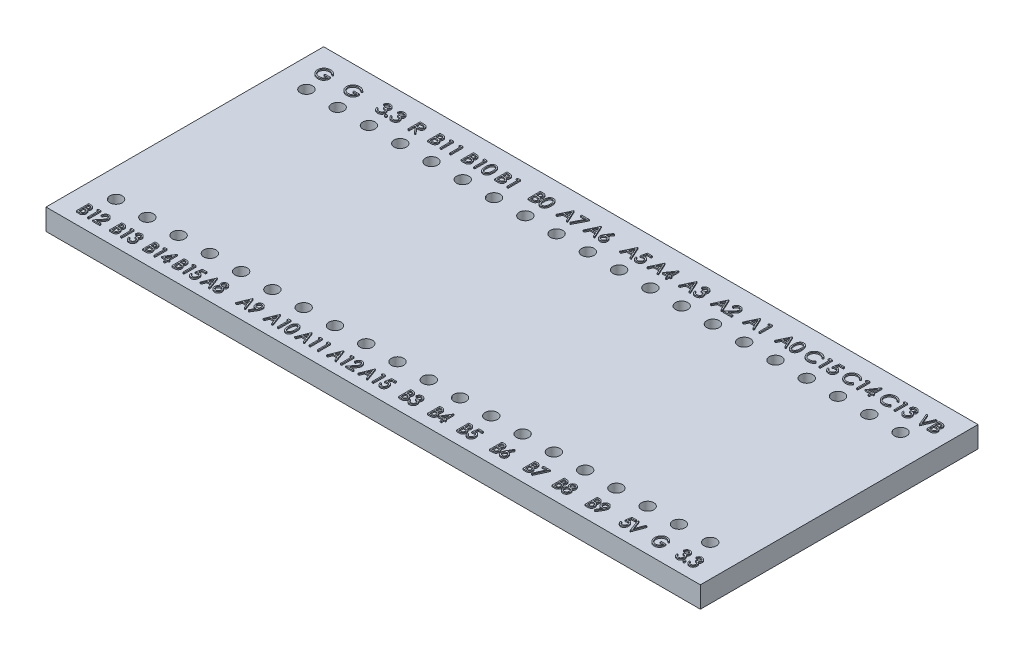
SolidWorks part; units mm, degrees
ref_plane "Front Plane" through (0, 0, 0) normal (0, 0, 1) x (1, 0, 0)
ref_plane "Top Plane" through (0, 0, 0) normal (0, 1, 0) x (1, 0, 0)
ref_plane "Right Plane" through (0, 0, 0) normal (1, 0, 0) x (0, 0, -1)
sketch "Sketch1" plane through (0, 0, 0) normal (0, 1, 0) x (1, 0, 0)
  line L0 (0, 11.275) -> (0, -11.275) construction
  line L1 (-26.575, 11.275) -> (26.575, 11.275)
  line L2 (-26.575, 11.275) -> (-26.575, -11.275)
  line L3 (-26.575, -11.275) -> (26.575, -11.275)
  line L4 (26.575, 11.275) -> (26.575, -11.275)
  point P6 (0, 0)
  dimension "D1" = 53.15
  dimension "D2" = 22.55
extrude "Boss-Extrude1" add sketch "Sketch1" along normal blind 1.72
sketch "Sketch2" plane through (0, 1.72, 0) normal (0, 1, 0) x (1, 0, 0)
  line L0 (26.575, 11.275) -> (-26.575, 11.275) construction
  line L1 (-26.575, 11.275) -> (-26.575, -11.275) construction
  circle A0 centre (-24.275, 7.575) radius 0.5
  circle A1 centre (-21.735, 7.575) radius 0.5
  circle A2 centre (-19.195, 7.575) radius 0.5
  circle A3 centre (-16.655, 7.575) radius 0.5
  circle A4 centre (-14.115, 7.575) radius 0.5
  circle A5 centre (-11.575, 7.575) radius 0.5
  circle A6 centre (-9.035, 7.575) radius 0.5
  circle A7 centre (-6.495, 7.575) radius 0.5
  circle A8 centre (-3.955, 7.575) radius 0.5
  circle A9 centre (-1.415, 7.575) radius 0.5
  circle A10 centre (1.125, 7.575) radius 0.5
  circle A11 centre (3.665, 7.575) radius 0.5
  circle A12 centre (6.205, 7.575) radius 0.5
  circle A13 centre (8.745, 7.575) radius 0.5
  circle A14 centre (11.285, 7.575) radius 0.5
  circle A15 centre (13.825, 7.575) radius 0.5
  circle A16 centre (16.365, 7.575) radius 0.5
  circle A17 centre (18.905, 7.575) radius 0.5
  circle A18 centre (21.445, 7.575) radius 0.5
  circle A19 centre (23.985, 7.575) radius 0.5
  circle A20 centre (-24.275, -7.885) radius 0.5
  circle A21 centre (-21.735, -7.885) radius 0.5
  circle A22 centre (-19.195, -7.885) radius 0.5
  circle A23 centre (-16.655, -7.885) radius 0.5
  circle A24 centre (-14.115, -7.885) radius 0.5
  circle A25 centre (-11.575, -7.885) radius 0.5
  circle A26 centre (-9.035, -7.885) radius 0.5
  circle A27 centre (-6.495, -7.885) radius 0.5
  circle A28 centre (-3.955, -7.885) radius 0.5
  circle A29 centre (-1.415, -7.885) radius 0.5
  circle A30 centre (1.125, -7.885) radius 0.5
  circle A31 centre (3.665, -7.885) radius 0.5
  circle A32 centre (6.205, -7.885) radius 0.5
  circle A33 centre (8.745, -7.885) radius 0.5
  circle A34 centre (11.285, -7.885) radius 0.5
  circle A35 centre (13.825, -7.885) radius 0.5
  circle A36 centre (16.365, -7.885) radius 0.5
  circle A37 centre (18.905, -7.885) radius 0.5
  circle A38 centre (21.445, -7.885) radius 0.5
  circle A39 centre (23.985, -7.885) radius 0.5
  dimension "D1" = 3.7
  dimension "D2" = 1
  dimension "D4" = 2.3
  dimension "D3" = 20
  dimension "D5" = 2
extrude "Cut-Extrude1" cut sketch "Sketch2" against normal through all
sketch "Sketch3" plane through (0, 1.72, 0) normal (0, 1, 0) x (1, 0, 0)
  line L0 (-24.1205, 9.6398) -> (-24.1974, 9.5669)
  line L1 (-24.1462, 9.1951) -> (-24.4795, 9.1951)
  line L2 (-24.4795, 9.1951) -> (-24.4795, 9.2976)
  line L3 (-24.4795, 9.2976) -> (-24.0564, 9.2976)
  line L4 (-21.7615, 9.6398) -> (-21.8385, 9.5669)
  line L5 (-21.7872, 9.1951) -> (-22.1205, 9.1951)
  line L6 (-22.1205, 9.1951) -> (-22.1205, 9.2976)
  line L7 (-22.1205, 9.2976) -> (-21.6974, 9.2976)
  line L8 (-19.9154, 9.5797) -> (-20.0051, 9.5797)
  line L9 (-20.0436, 9.0797) -> (-19.9538, 9.0797)
  line L10 (-19.7615, 9.3105) -> (-19.7615, 9.413)
  line L11 (-18.7744, 9.5797) -> (-18.8641, 9.5797)
  line L12 (-18.9026, 9.0797) -> (-18.8128, 9.0797)
  line L13 (-18.6205, 9.3105) -> (-18.6205, 9.413)
  line L14 (-17.2744, 9.8105) -> (-17.0742, 9.8105)
  line L15 (-17.0007, 9.272) -> (-16.6333, 8.8105)
  line L16 (-16.6333, 8.8105) -> (-16.7443, 8.8105)
  line L17 (-16.7443, 8.8105) -> (-17.1117, 9.272)
  line L18 (-17.1117, 9.272) -> (-17.1846, 9.272)
  line L19 (-17.1846, 9.272) -> (-17.1846, 8.8105)
  line L20 (-17.1846, 8.8105) -> (-17.2744, 8.8105)
  line L21 (-17.2744, 8.8105) -> (-17.2744, 9.8105)
  line L22 (-17.1846, 9.7079) -> (-17.1846, 9.3746)
  line L23 (-17.1846, 9.3746) -> (-17.0015, 9.3732)
  line L24 (-16.9971, 9.7079) -> (-17.1846, 9.7079)
  line L25 (-15.659, 9.8105) -> (-15.4639, 9.8105)
  line L26 (-15.3885, 8.8105) -> (-15.659, 8.8105)
  line L27 (-15.659, 8.8105) -> (-15.659, 9.8105)
  line L28 (-15.5692, 9.7079) -> (-15.5692, 9.3874)
  line L29 (-15.5692, 9.3874) -> (-15.5089, 9.3874)
  line L30 (-15.4474, 9.7079) -> (-15.5692, 9.7079)
  line L31 (-15.5692, 9.2848) -> (-15.5692, 8.913)
  line L32 (-15.5692, 8.913) -> (-15.4414, 8.913)
  line L33 (-15.5097, 9.2848) -> (-15.5692, 9.2848)
  line L34 (-14.7413, 9.8105) -> (-14.5564, 9.8105)
  line L35 (-14.5564, 9.8105) -> (-14.5564, 8.8105)
  line L36 (-14.5564, 8.8105) -> (-14.6462, 8.8105)
  line L37 (-14.6462, 8.8105) -> (-14.6462, 9.7079)
  line L38 (-14.6462, 9.7079) -> (-14.8, 9.7079)
  line L39 (-14.8, 9.7079) -> (-14.7413, 9.8105)
  line L40 (-13.9721, 9.8105) -> (-13.7872, 9.8105)
  line L41 (-13.7872, 9.8105) -> (-13.7872, 8.8105)
  line L42 (-13.7872, 8.8105) -> (-13.8769, 8.8105)
  line L43 (-13.8769, 8.8105) -> (-13.8769, 9.7079)
  line L44 (-13.8769, 9.7079) -> (-14.0308, 9.7079)
  line L45 (-14.0308, 9.7079) -> (-13.9721, 9.8105)
  line L46 (-12.941, 9.8105) -> (-12.7459, 9.8105)
  line L47 (-12.6706, 8.8105) -> (-12.941, 8.8105)
  line L48 (-12.941, 8.8105) -> (-12.941, 9.8105)
  line L49 (-12.8513, 9.7079) -> (-12.8513, 9.3874)
  line L50 (-12.8513, 9.3874) -> (-12.791, 9.3874)
  line L51 (-12.7295, 9.7079) -> (-12.8513, 9.7079)
  line L52 (-12.8513, 9.2848) -> (-12.8513, 8.913)
  line L53 (-12.8513, 8.913) -> (-12.7235, 8.913)
  line L54 (-12.7918, 9.2848) -> (-12.8513, 9.2848)
  line L55 (-12.0234, 9.8105) -> (-11.8385, 9.8105)
  line L56 (-11.8385, 9.8105) -> (-11.8385, 8.8105)
  line L57 (-11.8385, 8.8105) -> (-11.9282, 8.8105)
  line L58 (-11.9282, 8.8105) -> (-11.9282, 9.7079)
  line L59 (-11.9282, 9.7079) -> (-12.0821, 9.7079)
  line L60 (-12.0821, 9.7079) -> (-12.0234, 9.8105)
  line L61 (-10.2231, 9.8105) -> (-10.028, 9.8105)
  line L62 (-9.9526, 8.8105) -> (-10.2231, 8.8105)
  line L63 (-10.2231, 8.8105) -> (-10.2231, 9.8105)
  line L64 (-10.1333, 9.7079) -> (-10.1333, 9.3874)
  line L65 (-10.1333, 9.3874) -> (-10.073, 9.3874)
  line L66 (-10.0115, 9.7079) -> (-10.1333, 9.7079)
  line L67 (-10.1333, 9.2848) -> (-10.1333, 8.913)
  line L68 (-10.1333, 8.913) -> (-10.0055, 8.913)
  line L69 (-10.0738, 9.2848) -> (-10.1333, 9.2848)
  line L70 (-9.3054, 9.8105) -> (-9.1205, 9.8105)
  line L71 (-9.1205, 9.8105) -> (-9.1205, 8.8105)
  line L72 (-9.1205, 8.8105) -> (-9.2103, 8.8105)
  line L73 (-9.2103, 8.8105) -> (-9.2103, 9.7079)
  line L74 (-9.2103, 9.7079) -> (-9.3641, 9.7079)
  line L75 (-9.3641, 9.7079) -> (-9.3054, 9.8105)
  line L76 (-7.5051, 9.8105) -> (-7.31, 9.8105)
  line L77 (-7.2347, 8.8105) -> (-7.5051, 8.8105)
  line L78 (-7.5051, 8.8105) -> (-7.5051, 9.8105)
  line L79 (-7.4154, 9.7079) -> (-7.4154, 9.3874)
  line L80 (-7.4154, 9.3874) -> (-7.3551, 9.3874)
  line L81 (-7.2936, 9.7079) -> (-7.4154, 9.7079)
  line L82 (-7.4154, 9.2848) -> (-7.4154, 8.913)
  line L83 (-7.4154, 8.913) -> (-7.2876, 8.913)
  line L84 (-7.3559, 9.2848) -> (-7.4154, 9.2848)
  line L85 (-4.7615, 9.8105) -> (-4.3, 8.8105)
  line L86 (-4.3, 8.8105) -> (-4.3976, 8.8105)
  line L87 (-4.3976, 8.8105) -> (-4.5454, 9.131)
  line L88 (-4.5454, 9.131) -> (-4.9987, 9.131)
  line L89 (-4.9987, 9.131) -> (-5.1508, 8.8105)
  line L90 (-5.1508, 8.8105) -> (-5.2487, 8.8105)
  line L91 (-5.2487, 8.8105) -> (-4.7744, 9.8105)
  line L92 (-4.7744, 9.8105) -> (-4.7615, 9.8105)
  line L93 (-4.7689, 9.6155) -> (-4.95, 9.2335)
  line L94 (-4.95, 9.2335) -> (-4.5927, 9.2335)
  line L95 (-4.5927, 9.2335) -> (-4.7689, 9.6155)
  line L96 (-4.1462, 9.8105) -> (-3.5308, 9.8105)
  line L97 (-3.5308, 9.8105) -> (-4.0564, 8.7848)
  line L98 (-4.0564, 8.7848) -> (-4.1339, 8.8275)
  line L99 (-4.1339, 8.8275) -> (-3.6826, 9.7079)
  line L100 (-3.6826, 9.7079) -> (-4.1462, 9.7079)
  line L101 (-4.1462, 9.7079) -> (-4.1462, 9.8105)
  line L102 (-2.5564, 9.8105) -> (-2.0949, 8.8105)
  line L103 (-2.0949, 8.8105) -> (-2.1924, 8.8105)
  line L104 (-2.1924, 8.8105) -> (-2.3403, 9.131)
  line L105 (-2.3403, 9.131) -> (-2.7936, 9.131)
  line L106 (-2.7936, 9.131) -> (-2.9456, 8.8105)
  line L107 (-2.9456, 8.8105) -> (-3.0436, 8.8105)
  line L108 (-3.0436, 8.8105) -> (-2.5692, 9.8105)
  line L109 (-2.5692, 9.8105) -> (-2.5564, 9.8105)
  line L110 (-2.5638, 9.6155) -> (-2.7449, 9.2335)
  line L111 (-2.7449, 9.2335) -> (-2.3875, 9.2335)
  line L112 (-2.3875, 9.2335) -> (-2.5638, 9.6155)
  line L113 (-1.5436, 9.8361) -> (-1.4745, 9.7818)
  line L114 (-1.4745, 9.7818) -> (-1.7387, 9.3778)
  line L115 (-1.8421, 9.3798) -> (-1.5436, 9.8361)
  line L116 (0.4179, 9.8105) -> (0.8795, 8.8105)
  line L117 (0.8795, 8.8105) -> (0.7819, 8.8105)
  line L118 (0.7819, 8.8105) -> (0.6341, 9.131)
  line L119 (0.6341, 9.131) -> (0.1808, 9.131)
  line L120 (0.1808, 9.131) -> (0.0287, 8.8105)
  line L121 (0.0287, 8.8105) -> (-0.0692, 8.8105)
  line L122 (-0.0692, 8.8105) -> (0.4051, 9.8105)
  line L123 (0.4051, 9.8105) -> (0.4179, 9.8105)
  line L124 (0.4105, 9.6155) -> (0.2294, 9.2335)
  line L125 (0.2294, 9.2335) -> (0.5868, 9.2335)
  line L126 (0.5868, 9.2335) -> (0.4105, 9.6155)
  line L127 (1.5974, 9.8105) -> (1.5974, 9.7079)
  line L128 (1.5974, 9.7079) -> (1.2573, 9.7079)
  line L129 (1.2573, 9.7079) -> (1.2034, 9.4449)
  line L130 (0.9821, 9.0669) -> (1.0718, 9.0669)
  line L131 (1.0846, 9.3105) -> (1.1872, 9.8105)
  line L132 (1.1872, 9.8105) -> (1.5974, 9.8105)
  line L133 (2.6231, 9.8105) -> (3.0846, 8.8105)
  line L134 (3.0846, 8.8105) -> (2.9871, 8.8105)
  line L135 (2.9871, 8.8105) -> (2.8392, 9.131)
  line L136 (2.8392, 9.131) -> (2.3859, 9.131)
  line L137 (2.3859, 9.131) -> (2.2339, 8.8105)
  line L138 (2.2339, 8.8105) -> (2.1359, 8.8105)
  line L139 (2.1359, 8.8105) -> (2.6103, 9.8105)
  line L140 (2.6103, 9.8105) -> (2.6231, 9.8105)
  line L141 (2.6157, 9.6155) -> (2.4346, 9.2335)
  line L142 (2.4346, 9.2335) -> (2.7919, 9.2335)
  line L143 (2.7919, 9.2335) -> (2.6157, 9.6155)
  line L144 (3.7202, 9.8361) -> (3.7385, 9.8361)
  line L145 (3.7385, 9.8361) -> (3.7385, 9.1438)
  line L146 (3.7385, 9.1438) -> (3.8538, 9.1438)
  line L147 (3.8538, 9.1438) -> (3.8538, 9.0412)
  line L148 (3.8538, 9.0412) -> (3.7385, 9.0412)
  line L149 (3.7385, 9.0412) -> (3.7385, 8.8105)
  line L150 (3.7385, 8.8105) -> (3.6487, 8.8105)
  line L151 (3.6487, 8.8105) -> (3.6487, 9.0412)
  line L152 (3.6487, 9.0412) -> (3.1744, 9.0412)
  line L153 (3.1744, 9.0412) -> (3.7202, 9.8361)
  line L154 (3.6487, 9.1438) -> (3.6487, 9.5781)
  line L155 (3.6487, 9.5781) -> (3.3506, 9.1438)
  line L156 (3.3506, 9.1438) -> (3.6487, 9.1438)
  line L157 (5.2128, 9.8105) -> (5.6744, 8.8105)
  line L158 (5.6744, 8.8105) -> (5.5768, 8.8105)
  line L159 (5.5768, 8.8105) -> (5.429, 9.131)
  line L160 (5.429, 9.131) -> (4.9756, 9.131)
  line L161 (4.9756, 9.131) -> (4.8236, 8.8105)
  line L162 (4.8236, 8.8105) -> (4.7256, 8.8105)
  line L163 (4.7256, 8.8105) -> (5.2, 9.8105)
  line L164 (5.2, 9.8105) -> (5.2128, 9.8105)
  line L165 (5.2054, 9.6155) -> (5.0243, 9.2335)
  line L166 (5.0243, 9.2335) -> (5.3817, 9.2335)
  line L167 (5.3817, 9.2335) -> (5.2054, 9.6155)
  line L168 (5.8923, 9.5797) -> (5.8026, 9.5797)
  line L169 (5.7641, 9.0797) -> (5.8538, 9.0797)
  line L170 (6.0462, 9.3105) -> (6.0462, 9.413)
  line L171 (7.8026, 9.8105) -> (8.2641, 8.8105)
  line L172 (8.2641, 8.8105) -> (8.1665, 8.8105)
  line L173 (8.1665, 8.8105) -> (8.0187, 9.131)
  line L174 (8.0187, 9.131) -> (7.5654, 9.131)
  line L175 (7.5654, 9.131) -> (7.4133, 8.8105)
  line L176 (7.4133, 8.8105) -> (7.3154, 8.8105)
  line L177 (7.3154, 8.8105) -> (7.7897, 9.8105)
  line L178 (7.7897, 9.8105) -> (7.8026, 9.8105)
  line L179 (7.7952, 9.6155) -> (7.6141, 9.2335)
  line L180 (7.6141, 9.2335) -> (7.9714, 9.2335)
  line L181 (7.9714, 9.2335) -> (7.7952, 9.6155)
  line L182 (8.4821, 9.5028) -> (8.3923, 9.5028)
  line L183 (8.8182, 9.18) -> (8.568, 8.913)
  line L184 (8.568, 8.913) -> (9.0333, 8.913)
  line L185 (9.0333, 8.913) -> (9.0333, 8.8105)
  line L186 (9.0333, 8.8105) -> (8.3538, 8.8105)
  line L187 (8.3538, 8.8105) -> (8.7417, 9.2243)
  line L188 (10.3923, 9.8105) -> (10.8538, 8.8105)
  line L189 (10.8538, 8.8105) -> (10.7563, 8.8105)
  line L190 (10.7563, 8.8105) -> (10.6085, 9.131)
  line L191 (10.6085, 9.131) -> (10.1551, 9.131)
  line L192 (10.1551, 9.131) -> (10.0031, 8.8105)
  line L193 (10.0031, 8.8105) -> (9.9051, 8.8105)
  line L194 (9.9051, 8.8105) -> (10.3795, 9.8105)
  line L195 (10.3795, 9.8105) -> (10.3923, 9.8105)
  line L196 (10.3849, 9.6155) -> (10.2038, 9.2335)
  line L197 (10.2038, 9.2335) -> (10.5612, 9.2335)
  line L198 (10.5612, 9.2335) -> (10.3849, 9.6155)
  line L199 (11.1561, 9.8105) -> (11.341, 9.8105)
  line L200 (11.341, 9.8105) -> (11.341, 8.8105)
  line L201 (11.341, 8.8105) -> (11.2513, 8.8105)
  line L202 (11.2513, 8.8105) -> (11.2513, 9.7079)
  line L203 (11.2513, 9.7079) -> (11.0974, 9.7079)
  line L204 (11.0974, 9.7079) -> (11.1561, 9.8105)
  line L205 (12.9821, 9.8105) -> (13.4436, 8.8105)
  line L206 (13.4436, 8.8105) -> (13.346, 8.8105)
  line L207 (13.346, 8.8105) -> (13.1982, 9.131)
  line L208 (13.1982, 9.131) -> (12.7449, 9.131)
  line L209 (12.7449, 9.131) -> (12.5928, 8.8105)
  line L210 (12.5928, 8.8105) -> (12.4949, 8.8105)
  line L211 (12.4949, 8.8105) -> (12.9692, 9.8105)
  line L212 (12.9692, 9.8105) -> (12.9821, 9.8105)
  line L213 (12.9746, 9.6155) -> (12.7936, 9.2335)
  line L214 (12.7936, 9.2335) -> (13.1509, 9.2335)
  line L215 (13.1509, 9.2335) -> (12.9746, 9.6155)
  line L216 (15.7, 9.627) -> (15.6215, 9.5669)
  line L217 (15.6215, 9.054) -> (15.7, 8.9946)
  line L218 (16.0279, 9.8105) -> (16.2128, 9.8105)
  line L219 (16.2128, 9.8105) -> (16.2128, 8.8105)
  line L220 (16.2128, 8.8105) -> (16.1231, 8.8105)
  line L221 (16.1231, 8.8105) -> (16.1231, 9.7079)
  line L222 (16.1231, 9.7079) -> (15.9692, 9.7079)
  line L223 (15.9692, 9.7079) -> (16.0279, 9.8105)
  line L224 (17.2128, 9.8105) -> (17.2128, 9.7079)
  line L225 (17.2128, 9.7079) -> (16.8727, 9.7079)
  line L226 (16.8727, 9.7079) -> (16.8188, 9.4449)
  line L227 (16.5974, 9.0669) -> (16.6872, 9.0669)
  line L228 (16.7, 9.3105) -> (16.8026, 9.8105)
  line L229 (16.8026, 9.8105) -> (17.2128, 9.8105)
  line L230 (18.7513, 9.627) -> (18.6728, 9.5669)
  line L231 (18.6728, 9.054) -> (18.7513, 8.9946)
  line L232 (19.0792, 9.8105) -> (19.2641, 9.8105)
  line L233 (19.2641, 9.8105) -> (19.2641, 8.8105)
  line L234 (19.2641, 8.8105) -> (19.1744, 8.8105)
  line L235 (19.1744, 8.8105) -> (19.1744, 9.7079)
  line L236 (19.1744, 9.7079) -> (19.0205, 9.7079)
  line L237 (19.0205, 9.7079) -> (19.0792, 9.8105)
  line L238 (20.1818, 9.8361) -> (20.2, 9.8361)
  line L239 (20.2, 9.8361) -> (20.2, 9.1438)
  line L240 (20.2, 9.1438) -> (20.3154, 9.1438)
  line L241 (20.3154, 9.1438) -> (20.3154, 9.0412)
  line L242 (20.3154, 9.0412) -> (20.2, 9.0412)
  line L243 (20.2, 9.0412) -> (20.2, 8.8105)
  line L244 (20.2, 8.8105) -> (20.1103, 8.8105)
  line L245 (20.1103, 8.8105) -> (20.1103, 9.0412)
  line L246 (20.1103, 9.0412) -> (19.6359, 9.0412)
  line L247 (19.6359, 9.0412) -> (20.1818, 9.8361)
  line L248 (20.1103, 9.1438) -> (20.1103, 9.5781)
  line L249 (20.1103, 9.5781) -> (19.8122, 9.1438)
  line L250 (19.8122, 9.1438) -> (20.1103, 9.1438)
  line L251 (21.8026, 9.627) -> (21.724, 9.5669)
  line L252 (21.724, 9.054) -> (21.8026, 8.9946)
  line L253 (22.1305, 9.8105) -> (22.3154, 9.8105)
  line L254 (22.3154, 9.8105) -> (22.3154, 8.8105)
  line L255 (22.3154, 8.8105) -> (22.2256, 8.8105)
  line L256 (22.2256, 8.8105) -> (22.2256, 9.7079)
  line L257 (22.2256, 9.7079) -> (22.0718, 9.7079)
  line L258 (22.0718, 9.7079) -> (22.1305, 9.8105)
  line L259 (22.8154, 9.5797) -> (22.7256, 9.5797)
  line L260 (22.6872, 9.0797) -> (22.7769, 9.0797)
  line L261 (22.9692, 9.3105) -> (22.9692, 9.413)
  line L262 (23.8538, 9.8105) -> (23.95, 9.8105)
  line L263 (23.95, 9.8105) -> (24.2833, 9.0224)
  line L264 (24.2833, 9.0224) -> (24.6167, 9.8105)
  line L265 (24.6167, 9.8105) -> (24.7128, 9.8105)
  line L266 (24.7128, 9.8105) -> (24.2897, 8.8105)
  line L267 (24.2897, 8.8105) -> (24.2769, 8.8105)
  line L268 (24.2769, 8.8105) -> (23.8538, 9.8105)
  line L269 (24.8923, 9.8105) -> (25.0874, 9.8105)
  line L270 (25.1627, 8.8105) -> (24.8923, 8.8105)
  line L271 (24.8923, 8.8105) -> (24.8923, 9.8105)
  line L272 (24.9821, 9.7079) -> (24.9821, 9.3874)
  line L273 (24.9821, 9.3874) -> (25.0423, 9.3874)
  line L274 (25.1038, 9.7079) -> (24.9821, 9.7079)
  line L275 (24.9821, 9.2848) -> (24.9821, 8.913)
  line L276 (24.9821, 8.913) -> (25.1099, 8.913)
  line L277 (25.0415, 9.2848) -> (24.9821, 9.2848)
  line L278 (-24.9794, -9.4) -> (-24.8088, -9.4)
  line L279 (-24.7385, -10.4) -> (-24.9794, -10.4)
  line L280 (-24.9794, -10.4) -> (-24.9794, -9.4)
  line L281 (-24.8897, -9.5026) -> (-24.8897, -9.8231)
  line L282 (-24.8897, -9.8231) -> (-24.841, -9.8231)
  line L283 (-24.7913, -9.5026) -> (-24.8897, -9.5026)
  line L284 (-24.8897, -9.9256) -> (-24.8897, -10.2974)
  line L285 (-24.8897, -10.2974) -> (-24.7817, -10.2974)
  line L286 (-24.8416, -9.9256) -> (-24.8897, -9.9256)
  line L287 (-24.1693, -9.4) -> (-23.9923, -9.4)
  line L288 (-23.9923, -9.4) -> (-23.9923, -10.4)
  line L289 (-23.9923, -10.4) -> (-24.082, -10.4)
  line L290 (-24.082, -10.4) -> (-24.082, -9.5026)
  line L291 (-24.082, -9.5026) -> (-24.223, -9.5026)
  line L292 (-24.223, -9.5026) -> (-24.1693, -9.4)
  line L293 (-23.5692, -9.7077) -> (-23.6589, -9.7077)
  line L294 (-23.2671, -10.0366) -> (-23.479, -10.2974)
  line L295 (-23.479, -10.2974) -> (-23.082, -10.2974)
  line L296 (-23.082, -10.2974) -> (-23.082, -10.4)
  line L297 (-23.082, -10.4) -> (-23.6846, -10.4)
  line L298 (-23.6846, -10.4) -> (-23.3484, -9.9861)
  line L299 (-22.2871, -9.4) -> (-22.1165, -9.4)
  line L300 (-22.0462, -10.4) -> (-22.2871, -10.4)
  line L301 (-22.2871, -10.4) -> (-22.2871, -9.4)
  line L302 (-22.1974, -9.5026) -> (-22.1974, -9.8231)
  line L303 (-22.1974, -9.8231) -> (-22.1487, -9.8231)
  line L304 (-22.099, -9.5026) -> (-22.1974, -9.5026)
  line L305 (-22.1974, -9.9256) -> (-22.1974, -10.2974)
  line L306 (-22.1974, -10.2974) -> (-22.0894, -10.2974)
  line L307 (-22.1493, -9.9256) -> (-22.1974, -9.9256)
  line L308 (-21.477, -9.4) -> (-21.3, -9.4)
  line L309 (-21.3, -9.4) -> (-21.3, -10.4)
  line L310 (-21.3, -10.4) -> (-21.3897, -10.4)
  line L311 (-21.3897, -10.4) -> (-21.3897, -9.5026)
  line L312 (-21.3897, -9.5026) -> (-21.5307, -9.5026)
  line L313 (-21.5307, -9.5026) -> (-21.477, -9.4)
  line L314 (-20.8769, -9.6308) -> (-20.9666, -9.6308)
  line L315 (-20.9923, -10.1308) -> (-20.9025, -10.1308)
  line L316 (-20.7359, -9.9) -> (-20.7359, -9.7974)
  line L317 (-19.5948, -9.4) -> (-19.4242, -9.4)
  line L318 (-19.3538, -10.4) -> (-19.5948, -10.4)
  line L319 (-19.5948, -10.4) -> (-19.5948, -9.4)
  line L320 (-19.5051, -9.5026) -> (-19.5051, -9.8231)
  line L321 (-19.5051, -9.8231) -> (-19.4564, -9.8231)
  line L322 (-19.4067, -9.5026) -> (-19.5051, -9.5026)
  line L323 (-19.5051, -9.9256) -> (-19.5051, -10.2974)
  line L324 (-19.5051, -10.2974) -> (-19.3971, -10.2974)
  line L325 (-19.457, -9.9256) -> (-19.5051, -9.9256)
  line L326 (-18.7847, -9.4) -> (-18.6077, -9.4)
  line L327 (-18.6077, -9.4) -> (-18.6077, -10.4)
  line L328 (-18.6077, -10.4) -> (-18.6974, -10.4)
  line L329 (-18.6974, -10.4) -> (-18.6974, -9.5026)
  line L330 (-18.6974, -9.5026) -> (-18.8384, -9.5026)
  line L331 (-18.8384, -9.5026) -> (-18.7847, -9.4)
  line L332 (-17.8182, -9.3743) -> (-17.8, -9.3743)
  line L333 (-17.8, -9.3743) -> (-17.8, -10.0667)
  line L334 (-17.8, -10.0667) -> (-17.6974, -10.0667)
  line L335 (-17.6974, -10.0667) -> (-17.6974, -10.1692)
  line L336 (-17.6974, -10.1692) -> (-17.8, -10.1692)
  line L337 (-17.8, -10.1692) -> (-17.8, -10.4)
  line L338 (-17.8, -10.4) -> (-17.8897, -10.4)
  line L339 (-17.8897, -10.4) -> (-17.8897, -10.1692)
  line L340 (-17.8897, -10.1692) -> (-18.3, -10.1692)
  line L341 (-18.3, -10.1692) -> (-17.8182, -9.3743)
  line L342 (-17.8897, -10.0667) -> (-17.8897, -9.6718)
  line L343 (-17.8897, -9.6718) -> (-18.1289, -10.0667)
  line L344 (-18.1289, -10.0667) -> (-17.8897, -10.0667)
  line L345 (-17.2359, -9.4) -> (-17.0652, -9.4)
  line L346 (-16.9949, -10.4) -> (-17.2359, -10.4)
  line L347 (-17.2359, -10.4) -> (-17.2359, -9.4)
  line L348 (-17.1461, -9.5026) -> (-17.1461, -9.8231)
  line L349 (-17.1461, -9.8231) -> (-17.0974, -9.8231)
  line L350 (-17.0478, -9.5026) -> (-17.1461, -9.5026)
  line L351 (-17.1461, -9.9256) -> (-17.1461, -10.2974)
  line L352 (-17.1461, -10.2974) -> (-17.0381, -10.2974)
  line L353 (-17.098, -9.9256) -> (-17.1461, -9.9256)
  line L354 (-16.4258, -9.4) -> (-16.2487, -9.4)
  line L355 (-16.2487, -9.4) -> (-16.2487, -10.4)
  line L356 (-16.2487, -10.4) -> (-16.3384, -10.4)
  line L357 (-16.3384, -10.4) -> (-16.3384, -9.5026)
  line L358 (-16.3384, -9.5026) -> (-16.4794, -9.5026)
  line L359 (-16.4794, -9.5026) -> (-16.4258, -9.4)
  line L360 (-15.3769, -9.4) -> (-15.3769, -9.5026)
  line L361 (-15.3769, -9.5026) -> (-15.6756, -9.5026)
  line L362 (-15.6756, -9.5026) -> (-15.723, -9.7672)
  line L363 (-15.9282, -10.1436) -> (-15.8384, -10.1436)
  line L364 (-15.8384, -9.9) -> (-15.7487, -9.4)
  line L365 (-15.7487, -9.4) -> (-15.3769, -9.4)
  line L366 (-14.5179, -9.4) -> (-14.1461, -10.4)
  line L367 (-14.1461, -10.4) -> (-14.2435, -10.4)
  line L368 (-14.2435, -10.4) -> (-14.3625, -10.0795)
  line L369 (-14.3625, -10.0795) -> (-14.7106, -10.0795)
  line L370 (-14.7106, -10.0795) -> (-14.842, -10.4)
  line L371 (-14.842, -10.4) -> (-14.941, -10.4)
  line L372 (-14.941, -10.4) -> (-14.5307, -9.4)
  line L373 (-14.5307, -9.4) -> (-14.5179, -9.4)
  line L374 (-14.5279, -9.6346) -> (-14.6683, -9.9769)
  line L375 (-14.6683, -9.9769) -> (-14.4007, -9.9769)
  line L376 (-14.4007, -9.9769) -> (-14.5279, -9.6346)
  line L377 (-11.6205, -9.4) -> (-11.2487, -10.4)
  line L378 (-11.2487, -10.4) -> (-11.346, -10.4)
  line L379 (-11.346, -10.4) -> (-11.465, -10.0795)
  line L380 (-11.465, -10.0795) -> (-11.8132, -10.0795)
  line L381 (-11.8132, -10.0795) -> (-11.9446, -10.4)
  line L382 (-11.9446, -10.4) -> (-12.0435, -10.4)
  line L383 (-12.0435, -10.4) -> (-11.6333, -9.4)
  line L384 (-11.6333, -9.4) -> (-11.6205, -9.4)
  line L385 (-11.6305, -9.6346) -> (-11.7709, -9.9769)
  line L386 (-11.7709, -9.9769) -> (-11.5033, -9.9769)
  line L387 (-11.5033, -9.9769) -> (-11.6305, -9.6346)
  line L388 (-10.9538, -10.4256) -> (-11.0305, -10.3725)
  line L389 (-11.0305, -10.3725) -> (-10.7863, -9.9661)
  line L390 (-10.6834, -9.9753) -> (-10.9538, -10.4256)
  line L391 (-9.3897, -9.4) -> (-9.0179, -10.4)
  line L392 (-9.0179, -10.4) -> (-9.1153, -10.4)
  line L393 (-9.1153, -10.4) -> (-9.2343, -10.0795)
  line L394 (-9.2343, -10.0795) -> (-9.5824, -10.0795)
  line L395 (-9.5824, -10.0795) -> (-9.7138, -10.4)
  line L396 (-9.7138, -10.4) -> (-9.8128, -10.4)
  line L397 (-9.8128, -10.4) -> (-9.4025, -9.4)
  line L398 (-9.4025, -9.4) -> (-9.3897, -9.4)
  line L399 (-9.3997, -9.6346) -> (-9.5401, -9.9769)
  line L400 (-9.5401, -9.9769) -> (-9.2725, -9.9769)
  line L401 (-9.2725, -9.9769) -> (-9.3997, -9.6346)
  line L402 (-8.7335, -9.4) -> (-8.5564, -9.4)
  line L403 (-8.5564, -9.4) -> (-8.5564, -10.4)
  line L404 (-8.5564, -10.4) -> (-8.6461, -10.4)
  line L405 (-8.6461, -10.4) -> (-8.6461, -9.5026)
  line L406 (-8.6461, -9.5026) -> (-8.7871, -9.5026)
  line L407 (-8.7871, -9.5026) -> (-8.7335, -9.4)
  line L408 (-6.8256, -9.4) -> (-6.4538, -10.4)
  line L409 (-6.4538, -10.4) -> (-6.5512, -10.4)
  line L410 (-6.5512, -10.4) -> (-6.6702, -10.0795)
  line L411 (-6.6702, -10.0795) -> (-7.0183, -10.0795)
  line L412 (-7.0183, -10.0795) -> (-7.1497, -10.4)
  line L413 (-7.1497, -10.4) -> (-7.2487, -10.4)
  line L414 (-7.2487, -10.4) -> (-6.8384, -9.4)
  line L415 (-6.8384, -9.4) -> (-6.8256, -9.4)
  line L416 (-6.8356, -9.6346) -> (-6.976, -9.9769)
  line L417 (-6.976, -9.9769) -> (-6.7084, -9.9769)
  line L418 (-6.7084, -9.9769) -> (-6.8356, -9.6346)
  line L419 (-6.1693, -9.4) -> (-5.9923, -9.4)
  line L420 (-5.9923, -9.4) -> (-5.9923, -10.4)
  line L421 (-5.9923, -10.4) -> (-6.082, -10.4)
  line L422 (-6.082, -10.4) -> (-6.082, -9.5026)
  line L423 (-6.082, -9.5026) -> (-6.223, -9.5026)
  line L424 (-6.223, -9.5026) -> (-6.1693, -9.4)
  line L425 (-5.5027, -9.4) -> (-5.3256, -9.4)
  line L426 (-5.3256, -9.4) -> (-5.3256, -10.4)
  line L427 (-5.3256, -10.4) -> (-5.4153, -10.4)
  line L428 (-5.4153, -10.4) -> (-5.4153, -9.5026)
  line L429 (-5.4153, -9.5026) -> (-5.5564, -9.5026)
  line L430 (-5.5564, -9.5026) -> (-5.5027, -9.4)
  line L431 (-4.2615, -9.4) -> (-3.8897, -10.4)
  line L432 (-3.8897, -10.4) -> (-3.9871, -10.4)
  line L433 (-3.9871, -10.4) -> (-4.106, -10.0795)
  line L434 (-4.106, -10.0795) -> (-4.4542, -10.0795)
  line L435 (-4.4542, -10.0795) -> (-4.5856, -10.4)
  line L436 (-4.5856, -10.4) -> (-4.6846, -10.4)
  line L437 (-4.6846, -10.4) -> (-4.2743, -9.4)
  line L438 (-4.2743, -9.4) -> (-4.2615, -9.4)
  line L439 (-4.2715, -9.6346) -> (-4.4119, -9.9769)
  line L440 (-4.4119, -9.9769) -> (-4.1443, -9.9769)
  line L441 (-4.1443, -9.9769) -> (-4.2715, -9.6346)
  line L442 (-3.6052, -9.4) -> (-3.4282, -9.4)
  line L443 (-3.4282, -9.4) -> (-3.4282, -10.4)
  line L444 (-3.4282, -10.4) -> (-3.5179, -10.4)
  line L445 (-3.5179, -10.4) -> (-3.5179, -9.5026)
  line L446 (-3.5179, -9.5026) -> (-3.6589, -9.5026)
  line L447 (-3.6589, -9.5026) -> (-3.6052, -9.4)
  line L448 (-3.0051, -9.7077) -> (-3.0948, -9.7077)
  line L449 (-2.703, -10.0366) -> (-2.9149, -10.2974)
  line L450 (-2.9149, -10.2974) -> (-2.5179, -10.2974)
  line L451 (-2.5179, -10.2974) -> (-2.5179, -10.4)
  line L452 (-2.5179, -10.4) -> (-3.1205, -10.4)
  line L453 (-3.1205, -10.4) -> (-2.7843, -9.9861)
  line L454 (-1.6974, -9.4) -> (-1.3256, -10.4)
  line L455 (-1.3256, -10.4) -> (-1.423, -10.4)
  line L456 (-1.423, -10.4) -> (-1.5419, -10.0795)
  line L457 (-1.5419, -10.0795) -> (-1.8901, -10.0795)
  line L458 (-1.8901, -10.0795) -> (-2.0215, -10.4)
  line L459 (-2.0215, -10.4) -> (-2.1205, -10.4)
  line L460 (-2.1205, -10.4) -> (-1.7102, -9.4)
  line L461 (-1.7102, -9.4) -> (-1.6974, -9.4)
  line L462 (-1.7074, -9.6346) -> (-1.8478, -9.9769)
  line L463 (-1.8478, -9.9769) -> (-1.5802, -9.9769)
  line L464 (-1.5802, -9.9769) -> (-1.7074, -9.6346)
  line L465 (-1.0411, -9.4) -> (-0.8641, -9.4)
  line L466 (-0.8641, -9.4) -> (-0.8641, -10.4)
  line L467 (-0.8641, -10.4) -> (-0.9538, -10.4)
  line L468 (-0.9538, -10.4) -> (-0.9538, -9.5026)
  line L469 (-0.9538, -9.5026) -> (-1.0948, -9.5026)
  line L470 (-1.0948, -9.5026) -> (-1.0411, -9.4)
  line L471 (0.0077, -9.4) -> (0.0077, -9.5026)
  line L472 (0.0077, -9.5026) -> (-0.2909, -9.5026)
  line L473 (-0.2909, -9.5026) -> (-0.3384, -9.7672)
  line L474 (-0.5435, -10.1436) -> (-0.4538, -10.1436)
  line L475 (-0.4538, -9.9) -> (-0.3641, -9.4)
  line L476 (-0.3641, -9.4) -> (0.0077, -9.4)
  line L477 (1.1744, -9.4) -> (1.3451, -9.4)
  line L478 (1.4154, -10.4) -> (1.1744, -10.4)
  line L479 (1.1744, -10.4) -> (1.1744, -9.4)
  line L480 (1.2641, -9.5026) -> (1.2641, -9.8231)
  line L481 (1.2641, -9.8231) -> (1.3128, -9.8231)
  line L482 (1.3625, -9.5026) -> (1.2641, -9.5026)
  line L483 (1.2641, -9.9256) -> (1.2641, -10.2974)
  line L484 (1.2641, -10.2974) -> (1.3721, -10.2974)
  line L485 (1.3122, -9.9256) -> (1.2641, -9.9256)
  line L486 (1.918, -9.6308) -> (1.8282, -9.6308)
  line L487 (1.8026, -10.1308) -> (1.8923, -10.1308)
  line L488 (2.059, -9.9) -> (2.059, -9.7974)
  line L489 (3.5334, -9.4) -> (3.704, -9.4)
  line L490 (3.7744, -10.4) -> (3.5334, -10.4)
  line L491 (3.5334, -10.4) -> (3.5334, -9.4)
  line L492 (3.6231, -9.5026) -> (3.6231, -9.8231)
  line L493 (3.6231, -9.8231) -> (3.6718, -9.8231)
  line L494 (3.7215, -9.5026) -> (3.6231, -9.5026)
  line L495 (3.6231, -9.9256) -> (3.6231, -10.2974)
  line L496 (3.6231, -10.2974) -> (3.7311, -10.2974)
  line L497 (3.6712, -9.9256) -> (3.6231, -9.9256)
  line L498 (4.6434, -9.3743) -> (4.6616, -9.3743)
  line L499 (4.6616, -9.3743) -> (4.6616, -10.0667)
  line L500 (4.6616, -10.0667) -> (4.7641, -10.0667)
  line L501 (4.7641, -10.0667) -> (4.7641, -10.1692)
  line L502 (4.7641, -10.1692) -> (4.6616, -10.1692)
  line L503 (4.6616, -10.1692) -> (4.6616, -10.4)
  line L504 (4.6616, -10.4) -> (4.5718, -10.4)
  line L505 (4.5718, -10.4) -> (4.5718, -10.1692)
  line L506 (4.5718, -10.1692) -> (4.1616, -10.1692)
  line L507 (4.1616, -10.1692) -> (4.6434, -9.3743)
  line L508 (4.5718, -10.0667) -> (4.5718, -9.6718)
  line L509 (4.5718, -9.6718) -> (4.3327, -10.0667)
  line L510 (4.3327, -10.0667) -> (4.5718, -10.0667)
  line L511 (5.8923, -9.4) -> (6.063, -9.4)
  line L512 (6.1333, -10.4) -> (5.8923, -10.4)
  line L513 (5.8923, -10.4) -> (5.8923, -9.4)
  line L514 (5.9821, -9.5026) -> (5.9821, -9.8231)
  line L515 (5.9821, -9.8231) -> (6.0308, -9.8231)
  line L516 (6.0805, -9.5026) -> (5.9821, -9.5026)
  line L517 (5.9821, -9.9256) -> (5.9821, -10.2974)
  line L518 (5.9821, -10.2974) -> (6.0901, -10.2974)
  line L519 (6.0302, -9.9256) -> (5.9821, -9.9256)
  line L520 (7.0847, -9.4) -> (7.0847, -9.5026)
  line L521 (7.0847, -9.5026) -> (6.786, -9.5026)
  line L522 (6.786, -9.5026) -> (6.7385, -9.7672)
  line L523 (6.5334, -10.1436) -> (6.6231, -10.1436)
  line L524 (6.6231, -9.9) -> (6.7129, -9.4)
  line L525 (6.7129, -9.4) -> (7.0847, -9.4)
  line L526 (8.5847, -9.4) -> (8.7553, -9.4)
  line L527 (8.8256, -10.4) -> (8.5847, -10.4)
  line L528 (8.5847, -10.4) -> (8.5847, -9.4)
  line L529 (8.6744, -9.5026) -> (8.6744, -9.8231)
  line L530 (8.6744, -9.8231) -> (8.7231, -9.8231)
  line L531 (8.7728, -9.5026) -> (8.6744, -9.5026)
  line L532 (8.6744, -9.9256) -> (8.6744, -10.2974)
  line L533 (8.6744, -10.2974) -> (8.7824, -10.2974)
  line L534 (8.7225, -9.9256) -> (8.6744, -9.9256)
  line L535 (9.6103, -9.3743) -> (9.6842, -9.4322)
  line L536 (9.6842, -9.4322) -> (9.4536, -9.8353)
  line L537 (9.3491, -9.8307) -> (9.6103, -9.3743)
  line L538 (11.277, -9.4) -> (11.4476, -9.4)
  line L539 (11.518, -10.4) -> (11.277, -10.4)
  line L540 (11.277, -10.4) -> (11.277, -9.4)
  line L541 (11.3667, -9.5026) -> (11.3667, -9.8231)
  line L542 (11.3667, -9.8231) -> (11.4154, -9.8231)
  line L543 (11.4651, -9.5026) -> (11.3667, -9.5026)
  line L544 (11.3667, -9.9256) -> (11.3667, -10.2974)
  line L545 (11.3667, -10.2974) -> (11.4747, -10.2974)
  line L546 (11.4148, -9.9256) -> (11.3667, -9.9256)
  line L547 (11.9565, -9.4) -> (12.5077, -9.4)
  line L548 (12.5077, -9.4) -> (12.0462, -10.4256)
  line L549 (12.0462, -10.4256) -> (11.9653, -10.3814)
  line L550 (11.9653, -10.3814) -> (12.3607, -9.5026)
  line L551 (12.3607, -9.5026) -> (11.9565, -9.5026)
  line L552 (11.9565, -9.5026) -> (11.9565, -9.4)
  line L553 (13.6359, -9.4) -> (13.8066, -9.4)
  line L554 (13.8769, -10.4) -> (13.6359, -10.4)
  line L555 (13.6359, -10.4) -> (13.6359, -9.4)
  line L556 (13.7257, -9.5026) -> (13.7257, -9.8231)
  line L557 (13.7257, -9.8231) -> (13.7744, -9.8231)
  line L558 (13.824, -9.5026) -> (13.7257, -9.5026)
  line L559 (13.7257, -9.9256) -> (13.7257, -10.2974)
  line L560 (13.7257, -10.2974) -> (13.8337, -10.2974)
  line L561 (13.7738, -9.9256) -> (13.7257, -9.9256)
  line L562 (16.3282, -9.4) -> (16.4989, -9.4)
  line L563 (16.5692, -10.4) -> (16.3282, -10.4)
  line L564 (16.3282, -10.4) -> (16.3282, -9.4)
  line L565 (16.418, -9.5026) -> (16.418, -9.8231)
  line L566 (16.418, -9.8231) -> (16.4667, -9.8231)
  line L567 (16.5163, -9.5026) -> (16.418, -9.5026)
  line L568 (16.418, -9.9256) -> (16.418, -10.2974)
  line L569 (16.418, -10.2974) -> (16.526, -10.2974)
  line L570 (16.4661, -9.9256) -> (16.418, -9.9256)
  line L571 (17.1488, -10.4256) -> (17.072, -10.3725)
  line L572 (17.072, -10.3725) -> (17.3162, -9.9661)
  line L573 (17.4192, -9.9753) -> (17.1488, -10.4256)
  line L574 (19.5206, -9.4) -> (19.5206, -9.5026)
  line L575 (19.5206, -9.5026) -> (19.2219, -9.5026)
  line L576 (19.2219, -9.5026) -> (19.1744, -9.7672)
  line L577 (18.9693, -10.1436) -> (19.059, -10.1436)
  line L578 (19.059, -9.9) -> (19.1488, -9.4)
  line L579 (19.1488, -9.4) -> (19.5206, -9.4)
  line L580 (19.6231, -9.4) -> (19.7205, -9.4)
  line L581 (19.7205, -9.4) -> (20.0013, -10.1556)
  line L582 (20.0013, -10.1556) -> (20.2822, -9.4)
  line L583 (20.2822, -9.4) -> (20.3795, -9.4)
  line L584 (20.3795, -9.4) -> (20.0077, -10.4)
  line L585 (20.0077, -10.4) -> (19.9949, -10.4)
  line L586 (19.9949, -10.4) -> (19.6231, -9.4)
  line L587 (22.3667, -9.5707) -> (22.299, -9.6436)
  line L588 (22.3282, -10.0154) -> (22.0462, -10.0154)
  line L589 (22.0462, -10.0154) -> (22.0462, -9.9128)
  line L590 (22.0462, -9.9128) -> (22.418, -9.9128)
  line L591 (23.6488, -9.6308) -> (23.559, -9.6308)
  line L592 (23.5334, -10.1308) -> (23.6231, -10.1308)
  line L593 (23.7898, -9.9) -> (23.7898, -9.7974)
  line L594 (24.6488, -9.6308) -> (24.559, -9.6308)
  line L595 (24.5334, -10.1308) -> (24.6231, -10.1308)
  line L596 (24.7898, -9.9) -> (24.7898, -9.7974)
  spline S0 degree 3 poles (-24.1974, 9.5669) (-24.2243, 9.5934) (-24.2674, 9.6295) (-24.3305, 9.6682) (-24.379, 9.6916) (-24.428, 9.7102) (-24.4921, 9.7278) (-24.5408, 9.7336) (-24.5728, 9.7335) knots 0 0 0 0 0.269043 0.398517 0.5271 0.652283 0.77168 1 1 1 1
  spline S1 degree 3 poles (-24.5728, 9.7335) (-24.5922, 9.7338) (-24.6211, 9.7317) (-24.6591, 9.7258) (-24.6872, 9.7196) (-24.715, 9.7116) (-24.7424, 9.7017) (-24.7694, 9.6901) (-24.7959, 9.6767) (-24.8215, 9.662) (-24.8457, 9.6457) (-24.8687, 9.6283) (-24.8899, 9.6095) (-24.9096, 9.5893) (-24.9281, 9.5681) (-24.9449, 9.5454) (-24.9601, 9.5216) (-24.9736, 9.4971) (-24.9856, 9.4721) (-24.9956, 9.4467) (-25.0035, 9.421) (-25.0101, 9.395) (-25.0162, 9.3597) (-25.0177, 9.3328) (-25.0179, 9.3149) knots 0 0 0 0 0.085571 0.127719 0.170068 0.212787 0.255482 0.298877 0.342861 0.386528 0.429532 0.471886 0.513729 0.555082 0.596535 0.63812 0.679822 0.721331 0.761888 0.802199 0.841806 0.88106 0.920633 1 1 1 1
  spline S2 degree 3 poles (-25.0179, 9.3149) (-25.0177, 9.2965) (-25.0163, 9.2688) (-25.0094, 9.2327) (-25.0026, 9.2059) (-24.994, 9.1794) (-24.9833, 9.1533) (-24.9707, 9.1276) (-24.956, 9.1025) (-24.94, 9.0781) (-24.922, 9.0551) (-24.9029, 9.0332) (-24.882, 9.0129) (-24.8599, 8.9936) (-24.8361, 8.976) (-24.8109, 8.9595) (-24.7843, 8.9446) (-24.7566, 8.9312) (-24.7283, 8.9193) (-24.6991, 8.9095) (-24.6693, 8.9015) (-24.6389, 8.895) (-24.5971, 8.8893) (-24.5654, 8.8871) (-24.544, 8.8874) knots 0 0 0 0 0.077882 0.116652 0.155416 0.194618 0.234261 0.274547 0.315667 0.35702 0.398083 0.439098 0.479833 0.521274 0.562841 0.605292 0.648409 0.691727 0.735149 0.778369 0.821661 0.865524 0.909731 1 1 1 1
  spline S3 degree 3 poles (-24.544, 8.8874) (-24.5185, 8.8874) (-24.4809, 8.89) (-24.4322, 8.8988) (-24.3978, 8.9083) (-24.365, 8.9204) (-24.3336, 8.9349) (-24.3039, 8.9525) (-24.2757, 8.9724) (-24.2498, 8.9946) (-24.2264, 9.0185) (-24.206, 9.044) (-24.1881, 9.071) (-24.1733, 9.0997) (-24.1569, 9.1405) (-24.1495, 9.173) (-24.1462, 9.1951) knots 0 0 0 0 0.138694 0.204918 0.269441 0.332636 0.395302 0.457764 0.520657 0.582852 0.643315 0.70258 0.760908 0.81949 0.878269 1 1 1 1
  spline S4 degree 3 poles (-24.0564, 9.2976) (-24.0567, 9.2602) (-24.0606, 9.2053) (-24.0754, 9.135) (-24.0901, 9.0864) (-24.1092, 9.0409) (-24.1325, 8.9984) (-24.1602, 8.9592) (-24.1915, 8.9229) (-24.2266, 8.8905) (-24.2646, 8.862) (-24.3056, 8.838) (-24.3494, 8.8185) (-24.396, 8.8033) (-24.4633, 8.7886) (-24.516, 8.785) (-24.5518, 8.7848) knots 0 0 0 0 0.139493 0.204635 0.267406 0.328446 0.388397 0.447734 0.507392 0.566768 0.625478 0.684067 0.743248 0.804033 0.866499 1 1 1 1
  spline S5 degree 3 poles (-24.5518, 8.7848) (-24.5741, 8.7849) (-24.607, 8.7863) (-24.6502, 8.7911) (-24.6813, 8.7964) (-24.7115, 8.8029) (-24.7409, 8.8112) (-24.7694, 8.8208) (-24.797, 8.8317) (-24.8237, 8.8444) (-24.8494, 8.8585) (-24.8743, 8.8739) (-24.8983, 8.891) (-24.9215, 8.9095) (-24.9513, 8.9363) (-24.9719, 8.9585) (-24.9851, 8.9739) knots 0 0 0 0 0.136557 0.202094 0.266464 0.329769 0.391879 0.453271 0.514115 0.57439 0.634142 0.693923 0.754152 0.81447 0.875661 1 1 1 1
  spline S6 degree 3 poles (-24.9851, 8.9739) (-25.005, 8.9977) (-25.0319, 9.0352) (-25.0604, 9.0892) (-25.0777, 9.1307) (-25.0911, 9.1738) (-25.1042, 9.2336) (-25.1074, 9.2798) (-25.1077, 9.3109) knots 0 0 0 0 0.253668 0.376738 0.499344 0.621999 0.745699 1 1 1 1
  spline S7 degree 3 poles (-25.1077, 9.3109) (-25.108, 9.3342) (-25.1054, 9.3691) (-25.0983, 9.4148) (-25.0906, 9.4482) (-25.0808, 9.481) (-25.0687, 9.5133) (-25.0545, 9.5449) (-25.0381, 9.5757) (-25.0198, 9.6053) (-24.9999, 9.6336) (-24.9782, 9.66) (-24.955, 9.6849) (-24.93, 9.708) (-24.9035, 9.7295) (-24.8754, 9.7494) (-24.8458, 9.7674) (-24.8149, 9.7835) (-24.7828, 9.7977) (-24.7497, 9.8094) (-24.7157, 9.8193) (-24.6806, 9.8267) (-24.6321, 9.8339) (-24.5949, 9.8364) (-24.5698, 9.8361) knots 0 0 0 0 0.083544 0.124643 0.165303 0.206171 0.246971 0.288329 0.329987 0.371797 0.412738 0.453459 0.494001 0.534381 0.574952 0.615892 0.65725 0.699007 0.740486 0.782325 0.824567 0.867041 0.9105 1 1 1 1
  spline S8 degree 3 poles (-24.5698, 9.8361) (-24.5493, 9.836) (-24.5187, 9.8346) (-24.4783, 9.8297) (-24.4487, 9.8248) (-24.4195, 9.8181) (-24.3909, 9.8101) (-24.3626, 9.8007) (-24.3348, 9.7896) (-24.3073, 9.7769) (-24.28, 9.7627) (-24.253, 9.7467) (-24.2261, 9.7287) (-24.1992, 9.7092) (-24.1635, 9.6799) (-24.1373, 9.6565) (-24.1205, 9.6398) knots 0 0 0 0 0.122179 0.182216 0.241864 0.30096 0.359969 0.419033 0.478069 0.537993 0.59896 0.661321 0.725248 0.79122 0.858746 1 1 1 1
  spline S9 degree 3 poles (-21.8385, 9.5669) (-21.8653, 9.5934) (-21.9084, 9.6295) (-21.9715, 9.6682) (-22.02, 9.6916) (-22.069, 9.7102) (-22.1331, 9.7278) (-22.1818, 9.7336) (-22.2139, 9.7335) knots 0 0 0 0 0.269043 0.398517 0.5271 0.652283 0.77168 1 1 1 1
  spline S10 degree 3 poles (-22.2139, 9.7335) (-22.2332, 9.7338) (-22.2621, 9.7317) (-22.3001, 9.7258) (-22.3282, 9.7196) (-22.356, 9.7116) (-22.3834, 9.7017) (-22.4104, 9.6901) (-22.4369, 9.6767) (-22.4625, 9.662) (-22.4867, 9.6457) (-22.5097, 9.6283) (-22.5309, 9.6095) (-22.5506, 9.5893) (-22.5692, 9.5681) (-22.5859, 9.5454) (-22.6011, 9.5216) (-22.6146, 9.4971) (-22.6266, 9.4721) (-22.6366, 9.4467) (-22.6446, 9.421) (-22.6511, 9.395) (-22.6573, 9.3597) (-22.6587, 9.3328) (-22.659, 9.3149) knots 0 0 0 0 0.085571 0.127719 0.170068 0.212787 0.255482 0.298877 0.342861 0.386528 0.429532 0.471886 0.513729 0.555082 0.596535 0.63812 0.679822 0.721331 0.761888 0.802199 0.841806 0.88106 0.920633 1 1 1 1
  spline S11 degree 3 poles (-22.659, 9.3149) (-22.6588, 9.2965) (-22.6573, 9.2688) (-22.6504, 9.2327) (-22.6436, 9.2059) (-22.635, 9.1794) (-22.6244, 9.1533) (-22.6117, 9.1276) (-22.5971, 9.1025) (-22.581, 9.0781) (-22.563, 9.0551) (-22.5439, 9.0332) (-22.523, 9.0129) (-22.5009, 8.9936) (-22.4771, 8.976) (-22.4519, 8.9595) (-22.4253, 8.9446) (-22.3976, 8.9312) (-22.3693, 8.9193) (-22.3401, 8.9095) (-22.3103, 8.9015) (-22.28, 8.895) (-22.2381, 8.8893) (-22.2064, 8.8871) (-22.185, 8.8874) knots 0 0 0 0 0.077882 0.116652 0.155416 0.194618 0.234261 0.274547 0.315667 0.35702 0.398083 0.439098 0.479833 0.521274 0.562841 0.605292 0.648409 0.691727 0.735149 0.778369 0.821661 0.865524 0.909731 1 1 1 1
  spline S12 degree 3 poles (-22.185, 8.8874) (-22.1596, 8.8874) (-22.1219, 8.89) (-22.0732, 8.8988) (-22.0389, 8.9083) (-22.006, 8.9204) (-21.9746, 8.9349) (-21.9449, 8.9525) (-21.9168, 8.9724) (-21.8908, 8.9946) (-21.8674, 9.0185) (-21.847, 9.044) (-21.8291, 9.071) (-21.8144, 9.0997) (-21.798, 9.1405) (-21.7905, 9.173) (-21.7872, 9.1951) knots 0 0 0 0 0.138694 0.204918 0.269441 0.332636 0.395302 0.457764 0.520657 0.582852 0.643315 0.70258 0.760908 0.81949 0.878269 1 1 1 1
  spline S13 degree 3 poles (-21.6974, 9.2976) (-21.6977, 9.2602) (-21.7016, 9.2053) (-21.7164, 9.135) (-21.7311, 9.0864) (-21.7502, 9.0409) (-21.7735, 8.9984) (-21.8013, 8.9592) (-21.8325, 8.9229) (-21.8677, 8.8905) (-21.9056, 8.862) (-21.9466, 8.838) (-21.9904, 8.8185) (-22.037, 8.8033) (-22.1044, 8.7886) (-22.157, 8.785) (-22.1928, 8.7848) knots 0 0 0 0 0.139493 0.204635 0.267406 0.328446 0.388397 0.447734 0.507392 0.566768 0.625478 0.684067 0.743248 0.804033 0.866499 1 1 1 1
  spline S14 degree 3 poles (-22.1928, 8.7848) (-22.2151, 8.7849) (-22.248, 8.7863) (-22.2912, 8.7911) (-22.3223, 8.7964) (-22.3526, 8.8029) (-22.3819, 8.8112) (-22.4104, 8.8208) (-22.4381, 8.8317) (-22.4647, 8.8444) (-22.4904, 8.8585) (-22.5154, 8.8739) (-22.5394, 8.891) (-22.5625, 8.9095) (-22.5923, 8.9363) (-22.613, 8.9585) (-22.6261, 8.9739) knots 0 0 0 0 0.136557 0.202094 0.266464 0.329769 0.391879 0.453271 0.514115 0.57439 0.634142 0.693923 0.754152 0.81447 0.875661 1 1 1 1
  spline S15 degree 3 poles (-22.6261, 8.9739) (-22.646, 8.9977) (-22.6729, 9.0352) (-22.7014, 9.0892) (-22.7187, 9.1307) (-22.7322, 9.1738) (-22.7452, 9.2336) (-22.7485, 9.2798) (-22.7487, 9.3109) knots 0 0 0 0 0.253668 0.376738 0.499344 0.621999 0.745699 1 1 1 1
  spline S16 degree 3 poles (-22.7487, 9.3109) (-22.749, 9.3342) (-22.7464, 9.3691) (-22.7393, 9.4148) (-22.7316, 9.4482) (-22.7219, 9.481) (-22.7097, 9.5133) (-22.6956, 9.5449) (-22.6791, 9.5757) (-22.6608, 9.6053) (-22.6409, 9.6336) (-22.6192, 9.66) (-22.596, 9.6849) (-22.571, 9.708) (-22.5445, 9.7295) (-22.5165, 9.7494) (-22.4868, 9.7674) (-22.4559, 9.7835) (-22.4239, 9.7977) (-22.3907, 9.8094) (-22.3567, 9.8193) (-22.3216, 9.8267) (-22.2731, 9.8339) (-22.2359, 9.8364) (-22.2109, 9.8361) knots 0 0 0 0 0.083544 0.124643 0.165303 0.206171 0.246971 0.288329 0.329987 0.371797 0.412738 0.453459 0.494001 0.534381 0.574952 0.615892 0.65725 0.699007 0.740486 0.782325 0.824567 0.867041 0.9105 1 1 1 1
  spline S17 degree 3 poles (-22.2109, 9.8361) (-22.1903, 9.836) (-22.1597, 9.8346) (-22.1193, 9.8297) (-22.0897, 9.8248) (-22.0606, 9.8181) (-22.0319, 9.8101) (-22.0036, 9.8007) (-21.9758, 9.7896) (-21.9484, 9.7769) (-21.921, 9.7627) (-21.894, 9.7467) (-21.8671, 9.7287) (-21.8403, 9.7092) (-21.8045, 9.6799) (-21.7784, 9.6565) (-21.7615, 9.6398) knots 0 0 0 0 0.122179 0.182216 0.241864 0.30096 0.359969 0.419033 0.478069 0.537993 0.59896 0.661321 0.725248 0.79122 0.858746 1 1 1 1
  spline S18 degree 3 poles (-20.0051, 9.5797) (-20.0009, 9.5995) (-19.992, 9.628) (-19.9772, 9.6642) (-19.9643, 9.6888) (-19.9501, 9.7118) (-19.9339, 9.7329) (-19.9164, 9.7524) (-19.897, 9.7698) (-19.8767, 9.7855) (-19.8551, 9.7989) (-19.8328, 9.8104) (-19.8095, 9.8199) (-19.7852, 9.827) (-19.7513, 9.8341) (-19.7251, 9.8362) (-19.7075, 9.8361) knots 0 0 0 0 0.141977 0.208985 0.273957 0.336889 0.398745 0.460116 0.520825 0.580994 0.640152 0.698622 0.757271 0.816427 0.876254 1 1 1 1
  spline S19 degree 3 poles (-19.7075, 9.8361) (-19.6816, 9.8362) (-19.6431, 9.8317) (-19.5941, 9.8165) (-19.5592, 9.801) (-19.5269, 9.7818) (-19.4981, 9.7589) (-19.4733, 9.7329) (-19.4525, 9.7041) (-19.4362, 9.6733) (-19.4201, 9.6314) (-19.4155, 9.5982) (-19.4154, 9.5763) knots 0 0 0 0 0.17854 0.266093 0.354631 0.441886 0.525747 0.608114 0.690197 0.770821 0.848326 1 1 1 1
  spline S20 degree 3 poles (-19.4154, 9.5763) (-19.4154, 9.5556) (-19.4186, 9.5249) (-19.4312, 9.4863) (-19.4441, 9.4595) (-19.4607, 9.4344) (-19.4883, 9.4025) (-19.5138, 9.3825) (-19.5322, 9.3706) knots 0 0 0 0 0.250608 0.37063 0.490072 0.610375 0.734313 1 1 1 1
  spline S21 degree 3 poles (-19.5322, 9.3706) (-19.5108, 9.3611) (-19.4704, 9.3373) (-19.4376, 9.3037) (-19.4238, 9.2852) knots 0 0 0 0 0.503009 1 1 1 1
  spline S22 degree 3 poles (-19.4238, 9.2852) (-19.4138, 9.2725) (-19.4013, 9.2519) (-19.387, 9.2233) (-19.3786, 9.2013) (-19.3722, 9.1787) (-19.366, 9.1476) (-19.3642, 9.1236) (-19.3641, 9.1075) knots 0 0 0 0 0.254173 0.378112 0.501712 0.623986 0.747096 1 1 1 1
  spline S23 degree 3 poles (-19.3641, 9.1075) (-19.3639, 9.0796) (-19.37, 9.0375) (-19.389, 8.984) (-19.4091, 8.9454) (-19.4336, 8.9093) (-19.4628, 8.877) (-19.4963, 8.8492) (-19.5337, 8.826) (-19.5742, 8.8074) (-19.6327, 8.7899) (-19.6788, 8.7846) (-19.7101, 8.7848) knots 0 0 0 0 0.158922 0.239619 0.322609 0.406035 0.487602 0.569685 0.653036 0.737436 0.822478 1 1 1 1
  spline S24 degree 3 poles (-19.7101, 8.7848) (-19.7311, 8.785) (-19.7622, 8.7867) (-19.8022, 8.795) (-19.8304, 8.8032) (-19.8572, 8.8136) (-19.8826, 8.8265) (-19.9067, 8.8418) (-19.9293, 8.8595) (-19.9505, 8.8793) (-19.9695, 8.9015) (-19.9869, 8.9258) (-20.002, 8.9524) (-20.0156, 8.981) (-20.0309, 9.0232) (-20.0395, 9.0566) (-20.0436, 9.0797) knots 0 0 0 0 0.128963 0.190377 0.250092 0.308548 0.366398 0.424542 0.48317 0.542243 0.601739 0.662506 0.724856 0.789128 0.856346 1 1 1 1
  spline S25 degree 3 poles (-19.9538, 9.0797) (-19.9494, 9.0647) (-19.9425, 9.0428) (-19.9304, 9.0157) (-19.9209, 8.9976) (-19.911, 8.981) (-19.8965, 8.9617) (-19.8845, 8.9487) (-19.8755, 8.9415) knots 0 0 0 0 0.291316 0.425966 0.55216 0.671527 0.786122 1 1 1 1
  spline S26 degree 3 poles (-19.8755, 8.9415) (-19.8646, 8.9326) (-19.8469, 8.9207) (-19.8214, 8.908) (-19.8008, 8.9007) (-19.7794, 8.8946) (-19.7485, 8.889) (-19.7247, 8.8872) (-19.7085, 8.8874) knots 0 0 0 0 0.236178 0.355663 0.475904 0.600127 0.728608 1 1 1 1
  spline S27 degree 3 poles (-19.7085, 8.8874) (-19.6901, 8.8873) (-19.6633, 8.8894) (-19.6287, 8.8957) (-19.6049, 8.9028) (-19.5823, 8.9116) (-19.5614, 8.9226) (-19.5417, 8.9356) (-19.5236, 8.9503) (-19.5073, 8.9664) (-19.493, 8.9833) (-19.4808, 9.0008) (-19.471, 9.0191) (-19.4633, 9.0381) (-19.4561, 9.0646) (-19.4536, 9.0851) (-19.4538, 9.0989) knots 0 0 0 0 0.148752 0.218403 0.28576 0.350598 0.414964 0.478069 0.541761 0.60435 0.664075 0.721464 0.777587 0.832644 0.887844 1 1 1 1
  spline S28 degree 3 poles (-19.4538, 9.0989) (-19.4539, 9.1175) (-19.4582, 9.1455) (-19.4728, 9.1805) (-19.4881, 9.2054) (-19.5068, 9.2285) (-19.5286, 9.2491) (-19.5537, 9.2661) (-19.5769, 9.2778) (-19.5974, 9.2858) (-19.6149, 9.2912) (-19.6346, 9.2957) (-19.6561, 9.2999) (-19.6796, 9.3035) (-19.7149, 9.3076) (-19.7425, 9.3095) (-19.7615, 9.3105) knots 0 0 0 0 0.133485 0.201035 0.271234 0.34288 0.413836 0.485977 0.56023 0.599884 0.644055 0.691892 0.744688 0.801492 0.862858 1 1 1 1
  spline S29 degree 3 poles (-19.7615, 9.413) (-19.7373, 9.4126) (-19.7017, 9.4161) (-19.6557, 9.4255) (-19.6241, 9.436) (-19.5954, 9.4483) (-19.5704, 9.4625) (-19.5496, 9.4784) (-19.5331, 9.496) (-19.5207, 9.515) (-19.5085, 9.5412) (-19.5052, 9.5626) (-19.5051, 9.5767) knots 0 0 0 0 0.215787 0.318027 0.417574 0.51165 0.596162 0.672935 0.74367 0.810677 0.874059 1 1 1 1
  spline S30 degree 3 poles (-19.5051, 9.5767) (-19.5049, 9.5871) (-19.5069, 9.6025) (-19.5129, 9.6222) (-19.5191, 9.6364) (-19.5273, 9.6499) (-19.5371, 9.663) (-19.5488, 9.6755) (-19.5622, 9.6871) (-19.5766, 9.6982) (-19.5924, 9.7076) (-19.6091, 9.7156) (-19.6267, 9.7222) (-19.6453, 9.7272) (-19.6718, 9.7321) (-19.6923, 9.7335) (-19.7062, 9.7335) knots 0 0 0 0 0.109966 0.163247 0.218076 0.273301 0.330909 0.390995 0.454176 0.518862 0.583311 0.648517 0.715031 0.782502 0.852323 1 1 1 1
  spline S31 degree 3 poles (-19.7062, 9.7335) (-19.7285, 9.7336) (-19.7612, 9.7295) (-19.8017, 9.7147) (-19.8245, 9.7018) (-19.8413, 9.689) (-19.8534, 9.6778) (-19.8652, 9.6654) (-19.876, 9.651) (-19.8869, 9.6355) (-19.9006, 9.6118) (-19.9097, 9.5929) (-19.9154, 9.5797) knots 0 0 0 0 0.239685 0.351816 0.463766 0.520818 0.579448 0.640604 0.705298 0.773634 0.844669 1 1 1 1
  spline S32 degree 3 poles (-19.1141, 8.9643) (-19.1033, 8.9641) (-19.0867, 8.9616) (-19.0675, 8.951) (-19.0548, 8.9404) (-19.0443, 8.9277) (-19.0333, 8.9086) (-19.0311, 8.8918) (-19.0308, 8.881) knots 0 0 0 0 0.249986 0.371792 0.49887 0.625948 0.748492 1 1 1 1
  spline S33 degree 3 poles (-19.0308, 8.881) (-19.0311, 8.8702) (-19.0333, 8.8536) (-19.0444, 8.8347) (-19.0548, 8.8217) (-19.0676, 8.8112) (-19.0868, 8.8006) (-19.1032, 8.7977) (-19.1141, 8.7976) knots 0 0 0 0 0.248821 0.37154 0.499984 0.627244 0.749226 1 1 1 1
  spline S34 degree 3 poles (-19.1141, 8.7976) (-19.125, 8.7976) (-19.1413, 8.8007) (-19.1606, 8.8111) (-19.1734, 8.8217) (-19.1839, 8.8346) (-19.1945, 8.8538) (-19.1974, 8.8701) (-19.1974, 8.881) knots 0 0 0 0 0.249414 0.372796 0.500111 0.62861 0.750643 1 1 1 1
  spline S35 degree 3 poles (-19.1974, 8.881) (-19.1974, 8.8919) (-19.1945, 8.9084) (-19.1839, 8.9277) (-19.1734, 8.9404) (-19.1606, 8.951) (-19.1413, 8.9615) (-19.1249, 8.9642) (-19.1141, 8.9643) knots 0 0 0 0 0.252046 0.373905 0.501038 0.628171 0.751376 1 1 1 1
  spline S36 degree 3 poles (-18.8641, 9.5797) (-18.8599, 9.5995) (-18.8509, 9.628) (-18.8362, 9.6642) (-18.8232, 9.6888) (-18.8091, 9.7118) (-18.7929, 9.7329) (-18.7754, 9.7524) (-18.756, 9.7698) (-18.7357, 9.7855) (-18.7141, 9.7989) (-18.6918, 9.8104) (-18.6685, 9.8199) (-18.6441, 9.827) (-18.6102, 9.8341) (-18.5841, 9.8362) (-18.5664, 9.8361) knots 0 0 0 0 0.141977 0.208985 0.273957 0.336889 0.398745 0.460116 0.520825 0.580994 0.640152 0.698622 0.757271 0.816427 0.876254 1 1 1 1
  spline S37 degree 3 poles (-18.5664, 9.8361) (-18.5406, 9.8362) (-18.5021, 9.8317) (-18.453, 9.8165) (-18.4182, 9.801) (-18.3859, 9.7818) (-18.3571, 9.7589) (-18.3323, 9.7329) (-18.3114, 9.7041) (-18.2951, 9.6733) (-18.2791, 9.6314) (-18.2744, 9.5982) (-18.2744, 9.5763) knots 0 0 0 0 0.17854 0.266093 0.354631 0.441886 0.525747 0.608114 0.690197 0.770821 0.848326 1 1 1 1
  spline S38 degree 3 poles (-18.2744, 9.5763) (-18.2744, 9.5556) (-18.2775, 9.5249) (-18.2902, 9.4863) (-18.303, 9.4595) (-18.3197, 9.4344) (-18.3473, 9.4025) (-18.3728, 9.3825) (-18.3911, 9.3706) knots 0 0 0 0 0.250608 0.37063 0.490072 0.610375 0.734313 1 1 1 1
  spline S39 degree 3 poles (-18.3911, 9.3706) (-18.3698, 9.3611) (-18.3293, 9.3373) (-18.2966, 9.3037) (-18.2828, 9.2852) knots 0 0 0 0 0.503009 1 1 1 1
  spline S40 degree 3 poles (-18.2828, 9.2852) (-18.2728, 9.2725) (-18.2603, 9.2519) (-18.246, 9.2233) (-18.2376, 9.2013) (-18.2312, 9.1787) (-18.2249, 9.1476) (-18.2232, 9.1236) (-18.2231, 9.1075) knots 0 0 0 0 0.254173 0.378112 0.501712 0.623986 0.747096 1 1 1 1
  spline S41 degree 3 poles (-18.2231, 9.1075) (-18.2229, 9.0796) (-18.229, 9.0375) (-18.248, 8.984) (-18.2681, 8.9454) (-18.2926, 8.9093) (-18.3218, 8.877) (-18.3553, 8.8492) (-18.3927, 8.826) (-18.4332, 8.8074) (-18.4917, 8.7899) (-18.5378, 8.7846) (-18.569, 8.7848) knots 0 0 0 0 0.158922 0.239619 0.322609 0.406035 0.487602 0.569685 0.653036 0.737436 0.822478 1 1 1 1
  spline S42 degree 3 poles (-18.569, 8.7848) (-18.59, 8.785) (-18.6212, 8.7867) (-18.6612, 8.795) (-18.6894, 8.8032) (-18.7162, 8.8136) (-18.7416, 8.8265) (-18.7657, 8.8418) (-18.7883, 8.8595) (-18.8094, 8.8793) (-18.8285, 8.9015) (-18.8458, 8.9258) (-18.861, 8.9524) (-18.8746, 8.981) (-18.8899, 9.0232) (-18.8985, 9.0566) (-18.9026, 9.0797) knots 0 0 0 0 0.128963 0.190377 0.250092 0.308548 0.366398 0.424542 0.48317 0.542243 0.601739 0.662506 0.724856 0.789128 0.856346 1 1 1 1
  spline S43 degree 3 poles (-18.8128, 9.0797) (-18.8083, 9.0647) (-18.8015, 9.0428) (-18.7894, 9.0157) (-18.7799, 8.9976) (-18.77, 8.981) (-18.7555, 8.9617) (-18.7435, 8.9487) (-18.7345, 8.9415) knots 0 0 0 0 0.291316 0.425966 0.55216 0.671527 0.786122 1 1 1 1
  spline S44 degree 3 poles (-18.7345, 8.9415) (-18.7235, 8.9326) (-18.7059, 8.9207) (-18.6803, 8.908) (-18.6598, 8.9007) (-18.6384, 8.8946) (-18.6075, 8.889) (-18.5837, 8.8872) (-18.5674, 8.8874) knots 0 0 0 0 0.236178 0.355663 0.475904 0.600127 0.728608 1 1 1 1
  spline S45 degree 3 poles (-18.5674, 8.8874) (-18.5491, 8.8873) (-18.5223, 8.8894) (-18.4877, 8.8957) (-18.4638, 8.9028) (-18.4413, 8.9116) (-18.4203, 8.9226) (-18.4007, 8.9356) (-18.3826, 8.9503) (-18.3663, 8.9664) (-18.352, 8.9833) (-18.3398, 9.0008) (-18.33, 9.0191) (-18.3222, 9.0381) (-18.3151, 9.0646) (-18.3125, 9.0851) (-18.3128, 9.0989) knots 0 0 0 0 0.148752 0.218403 0.28576 0.350598 0.414964 0.478069 0.541761 0.60435 0.664075 0.721464 0.777587 0.832644 0.887844 1 1 1 1
  spline S46 degree 3 poles (-18.3128, 9.0989) (-18.3129, 9.1175) (-18.3171, 9.1455) (-18.3318, 9.1805) (-18.3471, 9.2054) (-18.3657, 9.2285) (-18.3876, 9.2491) (-18.4127, 9.2661) (-18.4359, 9.2778) (-18.4564, 9.2858) (-18.4739, 9.2912) (-18.4936, 9.2957) (-18.5151, 9.2999) (-18.5386, 9.3035) (-18.5739, 9.3076) (-18.6015, 9.3095) (-18.6205, 9.3105) knots 0 0 0 0 0.133485 0.201035 0.271234 0.34288 0.413836 0.485977 0.56023 0.599884 0.644055 0.691892 0.744688 0.801492 0.862858 1 1 1 1
  spline S47 degree 3 poles (-18.6205, 9.413) (-18.5963, 9.4126) (-18.5606, 9.4161) (-18.5147, 9.4255) (-18.4831, 9.436) (-18.4544, 9.4483) (-18.4294, 9.4625) (-18.4086, 9.4784) (-18.3921, 9.496) (-18.3797, 9.515) (-18.3675, 9.5412) (-18.3642, 9.5626) (-18.3641, 9.5767) knots 0 0 0 0 0.215787 0.318027 0.417574 0.51165 0.596162 0.672935 0.74367 0.810677 0.874059 1 1 1 1
  spline S48 degree 3 poles (-18.3641, 9.5767) (-18.3639, 9.5871) (-18.3659, 9.6025) (-18.3719, 9.6222) (-18.378, 9.6364) (-18.3862, 9.6499) (-18.3961, 9.663) (-18.4078, 9.6755) (-18.4212, 9.6871) (-18.4356, 9.6982) (-18.4514, 9.7076) (-18.4681, 9.7156) (-18.4857, 9.7222) (-18.5043, 9.7272) (-18.5308, 9.7321) (-18.5513, 9.7335) (-18.5652, 9.7335) knots 0 0 0 0 0.109966 0.163247 0.218076 0.273301 0.330909 0.390995 0.454176 0.518862 0.583311 0.648517 0.715031 0.782502 0.852323 1 1 1 1
  spline S49 degree 3 poles (-18.5652, 9.7335) (-18.5874, 9.7336) (-18.6202, 9.7295) (-18.6607, 9.7147) (-18.6835, 9.7018) (-18.7003, 9.689) (-18.7123, 9.6778) (-18.7242, 9.6654) (-18.735, 9.651) (-18.7459, 9.6355) (-18.7596, 9.6118) (-18.7687, 9.5929) (-18.7744, 9.5797) knots 0 0 0 0 0.239685 0.351816 0.463766 0.520818 0.579448 0.640604 0.705298 0.773634 0.844669 1 1 1 1
  spline S50 degree 3 poles (-17.0742, 9.8105) (-17.0486, 9.8103) (-17.0119, 9.8104) (-16.9651, 9.8085) (-16.9351, 9.8073) (-16.9085, 9.8052) (-16.8796, 9.8027) (-16.8597, 9.7995) (-16.8477, 9.7968) knots 0 0 0 0 0.338434 0.484822 0.617158 0.734698 0.837385 1 1 1 1
  spline S51 degree 3 poles (-16.8477, 9.7968) (-16.8331, 9.7936) (-16.8119, 9.787) (-16.7852, 9.7751) (-16.7664, 9.7649) (-16.7487, 9.753) (-16.7321, 9.7397) (-16.7163, 9.7251) (-16.7021, 9.7088) (-16.6887, 9.6917) (-16.6774, 9.6732) (-16.6676, 9.6539) (-16.6599, 9.6335) (-16.6536, 9.6123) (-16.6476, 9.5822) (-16.6461, 9.5588) (-16.6462, 9.543) knots 0 0 0 0 0.127064 0.188745 0.249132 0.309453 0.369827 0.43065 0.492352 0.554072 0.61569 0.676798 0.738439 0.801317 0.865185 1 1 1 1
  spline S52 degree 3 poles (-16.6462, 9.543) (-16.6461, 9.5171) (-16.6505, 9.4786) (-16.6675, 9.4308) (-16.6848, 9.3982) (-16.7067, 9.3688) (-16.7331, 9.3429) (-16.7639, 9.3213) (-16.7926, 9.3063) (-16.818, 9.2967) (-16.8388, 9.29) (-16.8616, 9.2848) (-16.886, 9.2801) (-16.9122, 9.2766) (-16.9506, 9.273) (-16.9803, 9.2721) (-17.0007, 9.272) knots 0 0 0 0 0.153721 0.226714 0.299191 0.37119 0.443006 0.516689 0.593217 0.633873 0.676989 0.7229 0.771959 0.824211 0.879379 1 1 1 1
  spline S53 degree 3 poles (-17.0015, 9.3732) (-16.9849, 9.3729) (-16.961, 9.3738) (-16.9301, 9.3756) (-16.9095, 9.3776) (-16.8907, 9.3801) (-16.8736, 9.3833) (-16.8581, 9.3871) (-16.8402, 9.3928) (-16.8201, 9.402) (-16.7983, 9.4153) (-16.7797, 9.432) (-16.764, 9.4511) (-16.7514, 9.4722) (-16.7395, 9.5026) (-16.7358, 9.5269) (-16.7359, 9.5432) knots 0 0 0 0 0.138913 0.201185 0.259124 0.312255 0.360682 0.405086 0.445102 0.518778 0.589462 0.658462 0.727283 0.796322 0.863175 1 1 1 1
  spline S54 degree 3 poles (-16.7359, 9.5432) (-16.7359, 9.5591) (-16.7393, 9.5831) (-16.7519, 9.6126) (-16.7645, 9.6332) (-16.78, 9.6519) (-16.7981, 9.6679) (-16.8183, 9.6811) (-16.8373, 9.6896) (-16.8542, 9.6947) (-16.8689, 9.6984) (-16.8855, 9.7013) (-16.9041, 9.7037) (-16.9246, 9.7057) (-16.9558, 9.7076) (-16.9802, 9.7079) (-16.9971, 9.7079) knots 0 0 0 0 0.136365 0.204019 0.273064 0.342913 0.410965 0.479169 0.549308 0.587652 0.630647 0.678879 0.731934 0.791111 0.855283 1 1 1 1
  spline S55 degree 3 poles (-15.4639, 9.8105) (-15.4453, 9.8106) (-15.4184, 9.8096) (-15.3837, 9.8067) (-15.3601, 9.8035) (-15.3383, 9.7995) (-15.3182, 9.7948) (-15.2997, 9.789) (-15.2777, 9.7799) (-15.2526, 9.7664) (-15.2254, 9.7464) (-15.2021, 9.722) (-15.1821, 9.6944) (-15.1661, 9.6641) (-15.1505, 9.6206) (-15.1459, 9.586) (-15.1462, 9.5627) knots 0 0 0 0 0.121323 0.17668 0.228365 0.276868 0.321879 0.364099 0.403356 0.477968 0.550535 0.623584 0.698175 0.773354 0.847281 1 1 1 1
  spline S56 degree 3 poles (-15.1462, 9.5627) (-15.146, 9.541) (-15.1497, 9.5087) (-15.1621, 9.468) (-15.1749, 9.4394) (-15.1915, 9.4131) (-15.218, 9.3804) (-15.2438, 9.3613) (-15.2617, 9.3499) knots 0 0 0 0 0.256581 0.380552 0.503623 0.625739 0.747549 1 1 1 1
  spline S57 degree 3 poles (-15.2617, 9.3499) (-15.2399, 9.3419) (-15.2091, 9.3289) (-15.173, 9.3064) (-15.1511, 9.2889) (-15.1325, 9.27) (-15.1162, 9.2495) (-15.1023, 9.227) (-15.0903, 9.2029) (-15.081, 9.1774) (-15.0716, 9.1414) (-15.0694, 9.1132) (-15.0692, 9.0943) knots 0 0 0 0 0.202914 0.2903 0.370223 0.446384 0.521397 0.598291 0.676142 0.755529 0.834887 1 1 1 1
  spline S58 degree 3 poles (-15.0692, 9.0943) (-15.0694, 9.0751) (-15.0717, 9.0466) (-15.081, 9.0102) (-15.0904, 8.9843) (-15.1028, 8.9595) (-15.1178, 8.9359) (-15.1357, 8.9135) (-15.1557, 8.8923) (-15.1783, 8.8732) (-15.2028, 8.8562) (-15.2293, 8.8422) (-15.2575, 8.8305) (-15.2876, 8.8215) (-15.3313, 8.8129) (-15.3653, 8.8102) (-15.3885, 8.8105) knots 0 0 0 0 0.120335 0.17818 0.235235 0.292683 0.351186 0.410457 0.47172 0.533761 0.595739 0.657888 0.721295 0.786823 0.854686 1 1 1 1
  spline S59 degree 3 poles (-15.5089, 9.3874) (-15.4919, 9.3877) (-15.4672, 9.3877) (-15.4355, 9.3901) (-15.4145, 9.3919) (-15.3952, 9.3948) (-15.3779, 9.3982) (-15.3621, 9.4018) (-15.344, 9.408) (-15.3234, 9.4171) (-15.3014, 9.4312) (-15.2821, 9.4481) (-15.2657, 9.4675) (-15.2524, 9.4889) (-15.2398, 9.5197) (-15.2355, 9.5443) (-15.2359, 9.5609) knots 0 0 0 0 0.1397 0.202289 0.2606 0.31319 0.361739 0.405706 0.44554 0.518832 0.589778 0.658867 0.72843 0.797283 0.864815 1 1 1 1
  spline S60 degree 3 poles (-15.2359, 9.5609) (-15.2359, 9.5717) (-15.2373, 9.5878) (-15.2429, 9.6081) (-15.2481, 9.6223) (-15.2555, 9.6353) (-15.2642, 9.6476) (-15.2747, 9.6587) (-15.2866, 9.6691) (-15.3003, 9.6783) (-15.3158, 9.6863) (-15.3333, 9.6928) (-15.3525, 9.6985) (-15.3736, 9.7025) (-15.4053, 9.7071) (-15.4303, 9.7078) (-15.4474, 9.7079) knots 0 0 0 0 0.111818 0.164402 0.21587 0.266841 0.317479 0.369902 0.4234 0.479718 0.539241 0.602431 0.67103 0.744485 0.823454 1 1 1 1
  spline S61 degree 3 poles (-15.4414, 8.913) (-15.4238, 8.9133) (-15.3983, 8.9134) (-15.3656, 8.9156) (-15.344, 8.9181) (-15.3241, 8.9208) (-15.3062, 8.9244) (-15.2901, 8.9285) (-15.2714, 8.9349) (-15.2504, 8.9448) (-15.2278, 8.9597) (-15.2077, 8.9775) (-15.1906, 8.9981) (-15.1766, 9.0205) (-15.163, 9.0521) (-15.159, 9.0775) (-15.159, 9.0943) knots 0 0 0 0 0.139739 0.201795 0.259822 0.312206 0.360773 0.40454 0.443698 0.516841 0.587874 0.657965 0.728969 0.799308 0.866636 1 1 1 1
  spline S62 degree 3 poles (-15.159, 9.0943) (-15.1588, 9.1048) (-15.1604, 9.1203) (-15.165, 9.1404) (-15.1694, 9.1549) (-15.1759, 9.1687) (-15.1834, 9.182) (-15.1923, 9.1949) (-15.2061, 9.2113) (-15.2261, 9.2301) (-15.2652, 9.2555) (-15.299, 9.2675) (-15.3226, 9.273) knots 0 0 0 0 0.119602 0.177503 0.235143 0.292133 0.350871 0.410098 0.470732 0.594829 0.722579 1 1 1 1
  spline S63 degree 3 poles (-15.3226, 9.273) (-15.3331, 9.2753) (-15.3503, 9.2779) (-15.3749, 9.2804) (-15.397, 9.2819) (-15.4216, 9.2834) (-15.4595, 9.2843) (-15.4892, 9.2849) (-15.5097, 9.2848) knots 0 0 0 0 0.171953 0.277057 0.394731 0.526177 0.671345 1 1 1 1
  spline S64 degree 3 poles (-12.7459, 9.8105) (-12.7274, 9.8106) (-12.7004, 9.8096) (-12.6657, 9.8067) (-12.6422, 9.8035) (-12.6204, 9.7995) (-12.6002, 9.7948) (-12.5818, 9.789) (-12.5597, 9.7799) (-12.5346, 9.7664) (-12.5074, 9.7464) (-12.4842, 9.722) (-12.4641, 9.6944) (-12.4482, 9.6641) (-12.4326, 9.6206) (-12.428, 9.586) (-12.4282, 9.5627) knots 0 0 0 0 0.121323 0.17668 0.228365 0.276868 0.321879 0.364099 0.403356 0.477968 0.550535 0.623584 0.698175 0.773354 0.847281 1 1 1 1
  spline S65 degree 3 poles (-12.4282, 9.5627) (-12.428, 9.541) (-12.4317, 9.5087) (-12.4442, 9.468) (-12.457, 9.4394) (-12.4736, 9.4131) (-12.5001, 9.3804) (-12.5258, 9.3613) (-12.5438, 9.3499) knots 0 0 0 0 0.256581 0.380552 0.503623 0.625739 0.747549 1 1 1 1
  spline S66 degree 3 poles (-12.5438, 9.3499) (-12.522, 9.3419) (-12.4911, 9.3289) (-12.455, 9.3064) (-12.4332, 9.2889) (-12.4145, 9.27) (-12.3982, 9.2495) (-12.3843, 9.227) (-12.3724, 9.2029) (-12.3631, 9.1774) (-12.3537, 9.1414) (-12.3515, 9.1132) (-12.3513, 9.0943) knots 0 0 0 0 0.202914 0.2903 0.370223 0.446384 0.521397 0.598291 0.676142 0.755529 0.834887 1 1 1 1
  spline S67 degree 3 poles (-12.3513, 9.0943) (-12.3514, 9.0751) (-12.3537, 9.0466) (-12.363, 9.0102) (-12.3725, 8.9843) (-12.3848, 8.9595) (-12.3998, 8.9359) (-12.4177, 8.9135) (-12.4377, 8.8923) (-12.4604, 8.8732) (-12.4848, 8.8562) (-12.5113, 8.8422) (-12.5395, 8.8305) (-12.5697, 8.8215) (-12.6134, 8.8129) (-12.6474, 8.8102) (-12.6706, 8.8105) knots 0 0 0 0 0.120335 0.17818 0.235235 0.292683 0.351186 0.410457 0.47172 0.533761 0.595739 0.657888 0.721295 0.786823 0.854686 1 1 1 1
  spline S68 degree 3 poles (-12.791, 9.3874) (-12.774, 9.3877) (-12.7493, 9.3877) (-12.7176, 9.3901) (-12.6965, 9.3919) (-12.6773, 9.3948) (-12.6599, 9.3982) (-12.6442, 9.4018) (-12.626, 9.408) (-12.6054, 9.4171) (-12.5835, 9.4312) (-12.5641, 9.4481) (-12.5478, 9.4675) (-12.5344, 9.4889) (-12.5219, 9.5197) (-12.5176, 9.5443) (-12.5179, 9.5609) knots 0 0 0 0 0.1397 0.202289 0.2606 0.31319 0.361739 0.405706 0.44554 0.518832 0.589778 0.658867 0.72843 0.797283 0.864815 1 1 1 1
  spline S69 degree 3 poles (-12.5179, 9.5609) (-12.518, 9.5717) (-12.5193, 9.5878) (-12.5249, 9.6081) (-12.5302, 9.6223) (-12.5376, 9.6353) (-12.5462, 9.6476) (-12.5567, 9.6587) (-12.5686, 9.6691) (-12.5824, 9.6783) (-12.5979, 9.6863) (-12.6153, 9.6928) (-12.6345, 9.6985) (-12.6557, 9.7025) (-12.6874, 9.7071) (-12.7123, 9.7078) (-12.7295, 9.7079) knots 0 0 0 0 0.111818 0.164402 0.21587 0.266841 0.317479 0.369902 0.4234 0.479718 0.539241 0.602431 0.67103 0.744485 0.823454 1 1 1 1
  spline S70 degree 3 poles (-12.7235, 8.913) (-12.7058, 8.9133) (-12.6804, 8.9134) (-12.6476, 8.9156) (-12.626, 8.9181) (-12.6061, 8.9208) (-12.5882, 8.9244) (-12.5721, 8.9285) (-12.5535, 8.9349) (-12.5325, 8.9448) (-12.5098, 8.9597) (-12.4897, 8.9775) (-12.4726, 8.9981) (-12.4587, 9.0205) (-12.445, 9.0521) (-12.441, 9.0775) (-12.441, 9.0943) knots 0 0 0 0 0.139739 0.201795 0.259822 0.312206 0.360773 0.40454 0.443698 0.516841 0.587874 0.657965 0.728969 0.799308 0.866636 1 1 1 1
  spline S71 degree 3 poles (-12.441, 9.0943) (-12.4408, 9.1048) (-12.4424, 9.1203) (-12.4471, 9.1404) (-12.4515, 9.1549) (-12.458, 9.1687) (-12.4655, 9.182) (-12.4743, 9.1949) (-12.4881, 9.2113) (-12.5082, 9.2301) (-12.5472, 9.2555) (-12.5811, 9.2675) (-12.6047, 9.273) knots 0 0 0 0 0.119602 0.177503 0.235143 0.292133 0.350871 0.410098 0.470732 0.594829 0.722579 1 1 1 1
  spline S72 degree 3 poles (-12.6047, 9.273) (-12.6152, 9.2753) (-12.6324, 9.2779) (-12.6569, 9.2804) (-12.6791, 9.2819) (-12.7037, 9.2834) (-12.7416, 9.2843) (-12.7712, 9.2849) (-12.7918, 9.2848) knots 0 0 0 0 0.171953 0.277057 0.394731 0.526177 0.671345 1 1 1 1
  spline S73 degree 3 poles (-11.4667, 9.3101) (-11.4667, 9.3412) (-11.4656, 9.3866) (-11.461, 9.4451) (-11.4564, 9.4849) (-11.4508, 9.5219) (-11.4433, 9.5559) (-11.4348, 9.5873) (-11.4249, 9.616) (-11.4138, 9.6424) (-11.4016, 9.6671) (-11.388, 9.69) (-11.3738, 9.7115) (-11.3582, 9.7312) (-11.3418, 9.7493) (-11.324, 9.7656) (-11.3053, 9.7804) (-11.2856, 9.7934) (-11.2654, 9.8048) (-11.2446, 9.8146) (-11.2232, 9.8223) (-11.2013, 9.8286) (-11.1711, 9.8345) (-11.1479, 9.8362) (-11.1323, 9.8361) knots 0 0 0 0 0.133246 0.194313 0.251279 0.304513 0.354235 0.400481 0.443411 0.484015 0.523252 0.561042 0.5979 0.633518 0.668314 0.702496 0.736685 0.770293 0.803437 0.835913 0.86846 0.900847 0.933467 1 1 1 1
  spline S74 degree 3 poles (-11.1323, 9.8361) (-11.1165, 9.8361) (-11.093, 9.8346) (-11.0623, 9.8286) (-11.0401, 9.8223) (-11.0184, 9.8146) (-10.9973, 9.8048) (-10.9766, 9.7935) (-10.9568, 9.7802) (-10.9376, 9.7653) (-10.9195, 9.7485) (-10.9024, 9.73) (-10.8862, 9.7098) (-10.8714, 9.6878) (-10.8572, 9.6641) (-10.8445, 9.6385) (-10.8323, 9.6113) (-10.8218, 9.5818) (-10.8123, 9.5501) (-10.8046, 9.516) (-10.7982, 9.4795) (-10.7932, 9.4405) (-10.7883, 9.3838) (-10.7874, 9.34) (-10.7872, 9.3101) knots 0 0 0 0 0.067194 0.099862 0.132567 0.165151 0.197913 0.231319 0.265083 0.299255 0.334399 0.369943 0.406284 0.444064 0.482998 0.523354 0.565537 0.609613 0.656391 0.705885 0.758325 0.813832 0.872795 1 1 1 1
  spline S75 degree 3 poles (-10.7872, 9.3101) (-10.7875, 9.2803) (-10.7882, 9.2366) (-10.7933, 9.1802) (-10.7979, 9.1414) (-10.8044, 9.1051) (-10.8122, 9.0712) (-10.821, 9.0395) (-10.8318, 9.0103) (-10.8436, 8.9832) (-10.8565, 8.9578) (-10.8703, 8.9341) (-10.8853, 8.9121) (-10.9013, 8.8917) (-10.9187, 8.8733) (-10.9369, 8.8564) (-10.9561, 8.8413) (-10.9763, 8.8281) (-10.9968, 8.8164) (-11.0182, 8.8069) (-11.0399, 8.7987) (-11.0622, 8.7925) (-11.0929, 8.7867) (-11.1165, 8.7846) (-11.1323, 8.7848) knots 0 0 0 0 0.126773 0.185516 0.240765 0.29298 0.34225 0.388919 0.432776 0.474628 0.514775 0.553606 0.591426 0.628028 0.663804 0.698984 0.733591 0.767628 0.801208 0.834264 0.866981 0.89972 0.932702 1 1 1 1
  spline S76 degree 3 poles (-11.1323, 8.7848) (-11.1479, 8.7847) (-11.1711, 8.7864) (-11.2012, 8.7923) (-11.223, 8.7984) (-11.2443, 8.8059) (-11.2649, 8.8157) (-11.285, 8.8269) (-11.3045, 8.8397) (-11.3231, 8.8544) (-11.3408, 8.8706) (-11.3573, 8.8888) (-11.3726, 8.9086) (-11.3872, 8.93) (-11.4006, 8.9531) (-11.413, 8.9779) (-11.4243, 9.0046) (-11.4343, 9.0335) (-11.4432, 9.0649) (-11.4502, 9.0992) (-11.4562, 9.1361) (-11.461, 9.1758) (-11.4656, 9.234) (-11.4667, 9.2791) (-11.4667, 9.3101) knots 0 0 0 0 0.066622 0.099285 0.131361 0.163585 0.196104 0.228902 0.262158 0.295991 0.330218 0.36506 0.400951 0.43762 0.475708 0.515381 0.556414 0.599765 0.646424 0.696431 0.749782 0.806573 0.867436 1 1 1 1
  spline S77 degree 3 poles (-11.3769, 9.3105) (-11.3772, 9.2845) (-11.376, 9.2468) (-11.3727, 9.1984) (-11.3697, 9.1657) (-11.3652, 9.1357) (-11.3601, 9.108) (-11.354, 9.0829) (-11.3467, 9.0602) (-11.3384, 9.0394) (-11.3293, 9.0201) (-11.3196, 9.002) (-11.3087, 8.9853) (-11.2968, 8.9699) (-11.2843, 8.9555) (-11.2705, 8.9427) (-11.2515, 8.9274) (-11.2265, 8.9115) (-11.1848, 8.8932) (-11.1514, 8.8874) (-11.1293, 8.8874) knots 0 0 0 0 0.141584 0.205926 0.265301 0.320597 0.371817 0.41879 0.461699 0.502134 0.540804 0.578181 0.614297 0.649678 0.684299 0.718359 0.752081 0.817652 0.879722 1 1 1 1
  spline S78 degree 3 poles (-11.1293, 8.8874) (-11.1072, 8.887) (-11.074, 8.8931) (-11.0324, 8.9108) (-11.0078, 8.9265) (-10.9891, 8.9415) (-10.9757, 8.9542) (-10.9634, 8.9685) (-10.9517, 8.9839) (-10.941, 9.0007) (-10.9278, 9.0254) (-10.9197, 9.0453) (-10.9148, 9.0591) knots 0 0 0 0 0.225394 0.339595 0.459675 0.521735 0.583926 0.648174 0.713881 0.781004 0.851451 1 1 1 1
  spline S79 degree 3 poles (-10.9148, 9.0591) (-10.9085, 9.0771) (-10.8997, 9.105) (-10.8915, 9.1437) (-10.886, 9.1744) (-10.8821, 9.2065) (-10.878, 9.2519) (-10.877, 9.2868) (-10.8769, 9.3105) knots 0 0 0 0 0.224542 0.342503 0.464324 0.590756 0.722227 1 1 1 1
  spline S80 degree 3 poles (-10.8769, 9.3105) (-10.8773, 9.334) (-10.8775, 9.3684) (-10.8816, 9.4131) (-10.885, 9.4442) (-10.8899, 9.4736) (-10.8953, 9.5014) (-10.9025, 9.5274) (-10.9102, 9.552) (-10.919, 9.5748) (-10.9287, 9.5959) (-10.939, 9.6156) (-10.9503, 9.6337) (-10.9623, 9.6502) (-10.9753, 9.665) (-10.989, 9.6784) (-11.0081, 9.6937) (-11.0331, 9.7092) (-11.0741, 9.7282) (-11.1075, 9.7332) (-11.1293, 9.7335) knots 0 0 0 0 0.128486 0.188175 0.245106 0.299448 0.350823 0.399942 0.446672 0.491255 0.533376 0.573853 0.612526 0.649597 0.685532 0.720106 0.753838 0.818925 0.880493 1 1 1 1
  spline S81 degree 3 poles (-11.1293, 9.7335) (-11.1514, 9.7332) (-11.1851, 9.7283) (-11.2266, 9.7093) (-11.2515, 9.6936) (-11.2706, 9.6786) (-11.2841, 9.6657) (-11.2967, 9.6515) (-11.3083, 9.636) (-11.3192, 9.6192) (-11.3292, 9.6013) (-11.3382, 9.5819) (-11.3465, 9.5611) (-11.3538, 9.5384) (-11.3598, 9.5133) (-11.3654, 9.4857) (-11.3693, 9.4555) (-11.3728, 9.4229) (-11.376, 9.3743) (-11.3772, 9.3365) (-11.3769, 9.3105) knots 0 0 0 0 0.120883 0.182755 0.247811 0.281299 0.315088 0.349702 0.384857 0.420966 0.458511 0.497175 0.537602 0.580503 0.627468 0.678388 0.733983 0.793747 0.857714 1 1 1 1
  spline S82 degree 3 poles (-10.028, 9.8105) (-10.0094, 9.8106) (-9.9825, 9.8096) (-9.9478, 9.8067) (-9.9243, 9.8035) (-9.9024, 9.7995) (-9.8823, 9.7948) (-9.8638, 9.789) (-9.8418, 9.7799) (-9.8167, 9.7664) (-9.7895, 9.7464) (-9.7662, 9.722) (-9.7462, 9.6944) (-9.7302, 9.6641) (-9.7146, 9.6206) (-9.71, 9.586) (-9.7103, 9.5627) knots 0 0 0 0 0.121323 0.17668 0.228365 0.276868 0.321879 0.364099 0.403356 0.477968 0.550535 0.623584 0.698175 0.773354 0.847281 1 1 1 1
  spline S83 degree 3 poles (-9.7103, 9.5627) (-9.7101, 9.541) (-9.7138, 9.5087) (-9.7263, 9.468) (-9.739, 9.4394) (-9.7556, 9.4131) (-9.7821, 9.3804) (-9.8079, 9.3613) (-9.8258, 9.3499) knots 0 0 0 0 0.256581 0.380552 0.503623 0.625739 0.747549 1 1 1 1
  spline S84 degree 3 poles (-9.8258, 9.3499) (-9.804, 9.3419) (-9.7732, 9.3289) (-9.7371, 9.3064) (-9.7152, 9.2889) (-9.6966, 9.27) (-9.6803, 9.2495) (-9.6664, 9.227) (-9.6544, 9.2029) (-9.6451, 9.1774) (-9.6357, 9.1414) (-9.6335, 9.1132) (-9.6333, 9.0943) knots 0 0 0 0 0.202914 0.2903 0.370223 0.446384 0.521397 0.598291 0.676142 0.755529 0.834887 1 1 1 1
  spline S85 degree 3 poles (-9.6333, 9.0943) (-9.6335, 9.0751) (-9.6358, 9.0466) (-9.6451, 9.0102) (-9.6545, 8.9843) (-9.6669, 8.9595) (-9.6819, 8.9359) (-9.6998, 8.9135) (-9.7198, 8.8923) (-9.7424, 8.8732) (-9.7669, 8.8562) (-9.7934, 8.8422) (-9.8216, 8.8305) (-9.8517, 8.8215) (-9.8954, 8.8129) (-9.9294, 8.8102) (-9.9526, 8.8105) knots 0 0 0 0 0.120335 0.17818 0.235235 0.292683 0.351186 0.410457 0.47172 0.533761 0.595739 0.657888 0.721295 0.786823 0.854686 1 1 1 1
  spline S86 degree 3 poles (-10.073, 9.3874) (-10.056, 9.3877) (-10.0313, 9.3877) (-9.9996, 9.3901) (-9.9786, 9.3919) (-9.9593, 9.3948) (-9.942, 9.3982) (-9.9262, 9.4018) (-9.9081, 9.408) (-9.8875, 9.4171) (-9.8655, 9.4312) (-9.8462, 9.4481) (-9.8298, 9.4675) (-9.8165, 9.4889) (-9.8039, 9.5197) (-9.7996, 9.5443) (-9.8, 9.5609) knots 0 0 0 0 0.1397 0.202289 0.2606 0.31319 0.361739 0.405706 0.44554 0.518832 0.589778 0.658867 0.72843 0.797283 0.864815 1 1 1 1
  spline S87 degree 3 poles (-9.8, 9.5609) (-9.8, 9.5717) (-9.8014, 9.5878) (-9.807, 9.6081) (-9.8122, 9.6223) (-9.8196, 9.6353) (-9.8283, 9.6476) (-9.8388, 9.6587) (-9.8507, 9.6691) (-9.8644, 9.6783) (-9.8799, 9.6863) (-9.8974, 9.6928) (-9.9166, 9.6985) (-9.9377, 9.7025) (-9.9694, 9.7071) (-9.9944, 9.7078) (-10.0115, 9.7079) knots 0 0 0 0 0.111818 0.164402 0.21587 0.266841 0.317479 0.369902 0.4234 0.479718 0.539241 0.602431 0.67103 0.744485 0.823454 1 1 1 1
  spline S88 degree 3 poles (-10.0055, 8.913) (-9.9879, 8.9133) (-9.9624, 8.9134) (-9.9297, 8.9156) (-9.9081, 8.9181) (-9.8882, 8.9208) (-9.8703, 8.9244) (-9.8542, 8.9285) (-9.8355, 8.9349) (-9.8145, 8.9448) (-9.7919, 8.9597) (-9.7718, 8.9775) (-9.7547, 8.9981) (-9.7407, 9.0205) (-9.7271, 9.0521) (-9.7231, 9.0775) (-9.7231, 9.0943) knots 0 0 0 0 0.139739 0.201795 0.259822 0.312206 0.360773 0.40454 0.443698 0.516841 0.587874 0.657965 0.728969 0.799308 0.866636 1 1 1 1
  spline S89 degree 3 poles (-9.7231, 9.0943) (-9.7229, 9.1048) (-9.7245, 9.1203) (-9.7291, 9.1404) (-9.7335, 9.1549) (-9.74, 9.1687) (-9.7475, 9.182) (-9.7564, 9.1949) (-9.7702, 9.2113) (-9.7902, 9.2301) (-9.8293, 9.2555) (-9.8631, 9.2675) (-9.8867, 9.273) knots 0 0 0 0 0.119602 0.177503 0.235143 0.292133 0.350871 0.410098 0.470732 0.594829 0.722579 1 1 1 1
  spline S90 degree 3 poles (-9.8867, 9.273) (-9.8972, 9.2753) (-9.9144, 9.2779) (-9.939, 9.2804) (-9.9611, 9.2819) (-9.9857, 9.2834) (-10.0236, 9.2843) (-10.0533, 9.2849) (-10.0738, 9.2848) knots 0 0 0 0 0.171953 0.277057 0.394731 0.526177 0.671345 1 1 1 1
  spline S91 degree 3 poles (-7.31, 9.8105) (-7.2915, 9.8106) (-7.2646, 9.8096) (-7.2298, 9.8067) (-7.2063, 9.8035) (-7.1845, 9.7995) (-7.1643, 9.7948) (-7.1459, 9.789) (-7.1238, 9.7799) (-7.0987, 9.7664) (-7.0715, 9.7464) (-7.0483, 9.722) (-7.0282, 9.6944) (-7.0123, 9.6641) (-6.9967, 9.6206) (-6.9921, 9.586) (-6.9923, 9.5627) knots 0 0 0 0 0.121323 0.17668 0.228365 0.276868 0.321879 0.364099 0.403356 0.477968 0.550535 0.623584 0.698175 0.773354 0.847281 1 1 1 1
  spline S92 degree 3 poles (-6.9923, 9.5627) (-6.9921, 9.541) (-6.9958, 9.5087) (-7.0083, 9.468) (-7.0211, 9.4394) (-7.0377, 9.4131) (-7.0642, 9.3804) (-7.0899, 9.3613) (-7.1079, 9.3499) knots 0 0 0 0 0.256581 0.380552 0.503623 0.625739 0.747549 1 1 1 1
  spline S93 degree 3 poles (-7.1079, 9.3499) (-7.0861, 9.3419) (-7.0552, 9.3289) (-7.0191, 9.3064) (-6.9973, 9.2889) (-6.9786, 9.27) (-6.9623, 9.2495) (-6.9484, 9.227) (-6.9365, 9.2029) (-6.9272, 9.1774) (-6.9178, 9.1414) (-6.9156, 9.1132) (-6.9154, 9.0943) knots 0 0 0 0 0.202914 0.2903 0.370223 0.446384 0.521397 0.598291 0.676142 0.755529 0.834887 1 1 1 1
  spline S94 degree 3 poles (-6.9154, 9.0943) (-6.9155, 9.0751) (-6.9178, 9.0466) (-6.9271, 9.0102) (-6.9366, 8.9843) (-6.9489, 8.9595) (-6.9639, 8.9359) (-6.9818, 8.9135) (-7.0018, 8.8923) (-7.0245, 8.8732) (-7.0489, 8.8562) (-7.0754, 8.8422) (-7.1036, 8.8305) (-7.1338, 8.8215) (-7.1775, 8.8129) (-7.2115, 8.8102) (-7.2347, 8.8105) knots 0 0 0 0 0.120335 0.17818 0.235235 0.292683 0.351186 0.410457 0.47172 0.533761 0.595739 0.657888 0.721295 0.786823 0.854686 1 1 1 1
  spline S95 degree 3 poles (-7.3551, 9.3874) (-7.3381, 9.3877) (-7.3134, 9.3877) (-7.2817, 9.3901) (-7.2606, 9.3919) (-7.2414, 9.3948) (-7.224, 9.3982) (-7.2083, 9.4018) (-7.1901, 9.408) (-7.1695, 9.4171) (-7.1476, 9.4312) (-7.1282, 9.4481) (-7.1119, 9.4675) (-7.0985, 9.4889) (-7.086, 9.5197) (-7.0817, 9.5443) (-7.0821, 9.5609) knots 0 0 0 0 0.1397 0.202289 0.2606 0.31319 0.361739 0.405706 0.44554 0.518832 0.589778 0.658867 0.72843 0.797283 0.864815 1 1 1 1
  spline S96 degree 3 poles (-7.0821, 9.5609) (-7.0821, 9.5717) (-7.0834, 9.5878) (-7.089, 9.6081) (-7.0943, 9.6223) (-7.1017, 9.6353) (-7.1103, 9.6476) (-7.1208, 9.6587) (-7.1327, 9.6691) (-7.1465, 9.6783) (-7.162, 9.6863) (-7.1794, 9.6928) (-7.1986, 9.6985) (-7.2198, 9.7025) (-7.2515, 9.7071) (-7.2764, 9.7078) (-7.2936, 9.7079) knots 0 0 0 0 0.111818 0.164402 0.21587 0.266841 0.317479 0.369902 0.4234 0.479718 0.539241 0.602431 0.67103 0.744485 0.823454 1 1 1 1
  spline S97 degree 3 poles (-7.2876, 8.913) (-7.27, 8.9133) (-7.2445, 8.9134) (-7.2117, 8.9156) (-7.1901, 8.9181) (-7.1702, 8.9208) (-7.1523, 8.9244) (-7.1362, 8.9285) (-7.1176, 8.9349) (-7.0966, 8.9448) (-7.074, 8.9597) (-7.0538, 8.9775) (-7.0367, 8.9981) (-7.0228, 9.0205) (-7.0091, 9.0521) (-7.0051, 9.0775) (-7.0051, 9.0943) knots 0 0 0 0 0.139739 0.201795 0.259822 0.312206 0.360773 0.40454 0.443698 0.516841 0.587874 0.657965 0.728969 0.799308 0.866636 1 1 1 1
  spline S98 degree 3 poles (-7.0051, 9.0943) (-7.0049, 9.1048) (-7.0065, 9.1203) (-7.0112, 9.1404) (-7.0156, 9.1549) (-7.0221, 9.1687) (-7.0296, 9.182) (-7.0384, 9.1949) (-7.0522, 9.2113) (-7.0723, 9.2301) (-7.1113, 9.2555) (-7.1452, 9.2675) (-7.1688, 9.273) knots 0 0 0 0 0.119602 0.177503 0.235143 0.292133 0.350871 0.410098 0.470732 0.594829 0.722579 1 1 1 1
  spline S99 degree 3 poles (-7.1688, 9.273) (-7.1793, 9.2753) (-7.1965, 9.2779) (-7.221, 9.2804) (-7.2432, 9.2819) (-7.2678, 9.2834) (-7.3057, 9.2843) (-7.3353, 9.2849) (-7.3559, 9.2848) knots 0 0 0 0 0.171953 0.277057 0.394731 0.526177 0.671345 1 1 1 1
  spline S100 degree 3 poles (-6.8, 9.3101) (-6.8, 9.3412) (-6.799, 9.3866) (-6.7943, 9.4451) (-6.7897, 9.4849) (-6.7841, 9.5219) (-6.7766, 9.5559) (-6.7681, 9.5873) (-6.7582, 9.616) (-6.7471, 9.6424) (-6.735, 9.6671) (-6.7214, 9.69) (-6.7071, 9.7115) (-6.6916, 9.7312) (-6.6752, 9.7493) (-6.6573, 9.7656) (-6.6387, 9.7804) (-6.6189, 9.7934) (-6.5988, 9.8048) (-6.578, 9.8146) (-6.5565, 9.8223) (-6.5346, 9.8286) (-6.5044, 9.8345) (-6.4812, 9.8362) (-6.4657, 9.8361) knots 0 0 0 0 0.133246 0.194313 0.251279 0.304513 0.354235 0.400481 0.443411 0.484015 0.523252 0.561042 0.5979 0.633518 0.668314 0.702496 0.736685 0.770293 0.803437 0.835913 0.86846 0.900847 0.933467 1 1 1 1
  spline S101 degree 3 poles (-6.4657, 9.8361) (-6.4499, 9.8361) (-6.4263, 9.8346) (-6.3957, 9.8286) (-6.3735, 9.8223) (-6.3517, 9.8146) (-6.3306, 9.8048) (-6.31, 9.7935) (-6.2902, 9.7802) (-6.2709, 9.7653) (-6.2528, 9.7485) (-6.2358, 9.73) (-6.2196, 9.7098) (-6.2047, 9.6878) (-6.1905, 9.6641) (-6.1779, 9.6385) (-6.1656, 9.6113) (-6.1551, 9.5818) (-6.1456, 9.5501) (-6.1379, 9.516) (-6.1315, 9.4795) (-6.1266, 9.4405) (-6.1216, 9.3838) (-6.1208, 9.34) (-6.1205, 9.3101) knots 0 0 0 0 0.067194 0.099862 0.132567 0.165151 0.197913 0.231319 0.265083 0.299255 0.334399 0.369943 0.406284 0.444064 0.482998 0.523354 0.565537 0.609613 0.656391 0.705885 0.758325 0.813832 0.872795 1 1 1 1
  spline S102 degree 3 poles (-6.1205, 9.3101) (-6.1208, 9.2803) (-6.1216, 9.2366) (-6.1266, 9.1802) (-6.1313, 9.1414) (-6.1377, 9.1051) (-6.1456, 9.0712) (-6.1543, 9.0395) (-6.1651, 9.0103) (-6.177, 8.9832) (-6.1898, 8.9578) (-6.2036, 8.9341) (-6.2187, 8.9121) (-6.2347, 8.8917) (-6.252, 8.8733) (-6.2702, 8.8564) (-6.2895, 8.8413) (-6.3096, 8.8281) (-6.3302, 8.8164) (-6.3515, 8.8069) (-6.3732, 8.7987) (-6.3955, 8.7925) (-6.4263, 8.7867) (-6.4498, 8.7846) (-6.4657, 8.7848) knots 0 0 0 0 0.126773 0.185516 0.240765 0.29298 0.34225 0.388919 0.432776 0.474628 0.514775 0.553606 0.591426 0.628028 0.663804 0.698984 0.733591 0.767628 0.801208 0.834264 0.866981 0.89972 0.932702 1 1 1 1
  spline S103 degree 3 poles (-6.4657, 8.7848) (-6.4812, 8.7847) (-6.5044, 8.7864) (-6.5345, 8.7923) (-6.5563, 8.7984) (-6.5777, 8.8059) (-6.5983, 8.8157) (-6.6183, 8.8269) (-6.6378, 8.8397) (-6.6564, 8.8544) (-6.6742, 8.8706) (-6.6906, 8.8888) (-6.706, 8.9086) (-6.7205, 8.93) (-6.7339, 8.9531) (-6.7463, 8.9779) (-6.7576, 9.0046) (-6.7677, 9.0335) (-6.7765, 9.0649) (-6.7836, 9.0992) (-6.7895, 9.1361) (-6.7944, 9.1758) (-6.7989, 9.234) (-6.8001, 9.2791) (-6.8, 9.3101) knots 0 0 0 0 0.066622 0.099285 0.131361 0.163585 0.196104 0.228902 0.262158 0.295991 0.330218 0.36506 0.400951 0.43762 0.475708 0.515381 0.556414 0.599765 0.646424 0.696431 0.749782 0.806573 0.867436 1 1 1 1
  spline S104 degree 3 poles (-6.7103, 9.3105) (-6.7105, 9.2845) (-6.7093, 9.2468) (-6.7061, 9.1984) (-6.703, 9.1657) (-6.6985, 9.1357) (-6.6935, 9.108) (-6.6873, 9.0829) (-6.68, 9.0602) (-6.6717, 9.0394) (-6.6627, 9.0201) (-6.6529, 9.002) (-6.642, 8.9853) (-6.6302, 8.9699) (-6.6176, 8.9555) (-6.6039, 8.9427) (-6.5849, 8.9274) (-6.5598, 8.9115) (-6.5181, 8.8932) (-6.4847, 8.8874) (-6.4627, 8.8874) knots 0 0 0 0 0.141584 0.205926 0.265301 0.320597 0.371817 0.41879 0.461699 0.502134 0.540804 0.578181 0.614297 0.649678 0.684299 0.718359 0.752081 0.817652 0.879722 1 1 1 1
  spline S105 degree 3 poles (-6.4627, 8.8874) (-6.4405, 8.887) (-6.4073, 8.8931) (-6.3658, 8.9108) (-6.3412, 8.9265) (-6.3225, 8.9415) (-6.3091, 8.9542) (-6.2967, 8.9685) (-6.2851, 8.9839) (-6.2744, 9.0007) (-6.2611, 9.0254) (-6.253, 9.0453) (-6.2481, 9.0591) knots 0 0 0 0 0.225394 0.339595 0.459675 0.521735 0.583926 0.648174 0.713881 0.781004 0.851451 1 1 1 1
  spline S106 degree 3 poles (-6.2481, 9.0591) (-6.2419, 9.0771) (-6.233, 9.105) (-6.2249, 9.1437) (-6.2193, 9.1744) (-6.2155, 9.2065) (-6.2113, 9.2519) (-6.2103, 9.2868) (-6.2103, 9.3105) knots 0 0 0 0 0.224542 0.342503 0.464324 0.590756 0.722227 1 1 1 1
  spline S107 degree 3 poles (-6.2103, 9.3105) (-6.2107, 9.334) (-6.2108, 9.3684) (-6.2149, 9.4131) (-6.2183, 9.4442) (-6.2233, 9.4736) (-6.2286, 9.5014) (-6.2358, 9.5274) (-6.2435, 9.552) (-6.2523, 9.5748) (-6.262, 9.5959) (-6.2724, 9.6156) (-6.2836, 9.6337) (-6.2956, 9.6502) (-6.3087, 9.665) (-6.3223, 9.6784) (-6.3414, 9.6937) (-6.3664, 9.7092) (-6.4075, 9.7282) (-6.4408, 9.7332) (-6.4627, 9.7335) knots 0 0 0 0 0.128486 0.188175 0.245106 0.299448 0.350823 0.399942 0.446672 0.491255 0.533376 0.573853 0.612526 0.649597 0.685532 0.720106 0.753838 0.818925 0.880493 1 1 1 1
  spline S108 degree 3 poles (-6.4627, 9.7335) (-6.4847, 9.7332) (-6.5185, 9.7283) (-6.5599, 9.7093) (-6.5848, 9.6936) (-6.6039, 9.6786) (-6.6174, 9.6657) (-6.63, 9.6515) (-6.6416, 9.636) (-6.6525, 9.6192) (-6.6625, 9.6013) (-6.6715, 9.5819) (-6.6798, 9.5611) (-6.6871, 9.5384) (-6.6931, 9.5133) (-6.6987, 9.4857) (-6.7027, 9.4555) (-6.7062, 9.4229) (-6.7093, 9.3743) (-6.7105, 9.3365) (-6.7103, 9.3105) knots 0 0 0 0 0.120883 0.182755 0.247811 0.281299 0.315088 0.349702 0.384857 0.420966 0.458511 0.497175 0.537602 0.580503 0.627468 0.678388 0.733983 0.793747 0.857714 1 1 1 1
  spline S109 degree 2 poles (-1.7387, 9.3778) (-1.6873, 9.3871) (-1.6351, 9.3874) knots 0 0 0 1 1 1
  spline S110 degree 3 poles (-1.6351, 9.3874) (-1.6151, 9.3873) (-1.5855, 9.3848) (-1.5474, 9.3759) (-1.5204, 9.3664) (-1.4946, 9.3543) (-1.4698, 9.3397) (-1.4466, 9.322) (-1.4245, 9.3022) (-1.4044, 9.2803) (-1.3866, 9.257) (-1.3717, 9.2325) (-1.3596, 9.2066) (-1.3502, 9.1794) (-1.3409, 9.1411) (-1.3386, 9.1112) (-1.3385, 9.0911) knots 0 0 0 0 0.128405 0.190067 0.250943 0.311546 0.372863 0.435024 0.499072 0.563091 0.62551 0.68668 0.747283 0.808563 0.870742 1 1 1 1
  spline S111 degree 3 poles (-1.3385, 9.0911) (-1.3382, 9.0636) (-1.3432, 9.0228) (-1.36, 8.9713) (-1.3777, 8.9356) (-1.3997, 8.9024) (-1.4266, 8.873) (-1.4573, 8.8469) (-1.492, 8.8249) (-1.5293, 8.8071) (-1.5819, 8.7898) (-1.6233, 8.7849) (-1.651, 8.7848) knots 0 0 0 0 0.169125 0.250399 0.33229 0.413364 0.494172 0.576022 0.660757 0.745783 0.830044 1 1 1 1
  spline S112 degree 3 poles (-1.651, 8.7848) (-1.6776, 8.7847) (-1.7175, 8.7895) (-1.768, 8.8063) (-1.8038, 8.8235) (-1.8371, 8.8452) (-1.8668, 8.8714) (-1.8929, 8.9014) (-1.9146, 8.9353) (-1.9318, 8.9718) (-1.9491, 9.0225) (-1.9536, 9.0626) (-1.9538, 9.0893) knots 0 0 0 0 0.167052 0.249566 0.33274 0.415915 0.497828 0.580373 0.6646 0.749467 0.83251 1 1 1 1
  spline S113 degree 3 poles (-1.9538, 9.0893) (-1.9537, 9.1103) (-1.9504, 9.1425) (-1.9403, 9.1851) (-1.9316, 9.2127) (-1.9225, 9.2354) (-1.9148, 9.2536) (-1.9054, 9.2724) (-1.8953, 9.2924) (-1.8836, 9.313) (-1.8663, 9.3426) (-1.8519, 9.3646) (-1.8421, 9.3798) knots 0 0 0 0 0.199726 0.305276 0.415811 0.474472 0.537274 0.603657 0.674299 0.749834 0.828598 1 1 1 1
  spline S114 degree 3 poles (-1.654, 9.2848) (-1.6688, 9.2845) (-1.6909, 9.2834) (-1.719, 9.2769) (-1.7387, 9.2708) (-1.7572, 9.2625) (-1.7746, 9.2524) (-1.7909, 9.2405) (-1.806, 9.227) (-1.8196, 9.2122) (-1.8314, 9.1964) (-1.8415, 9.1799) (-1.8498, 9.1625) (-1.8562, 9.1444) (-1.8625, 9.1189) (-1.8639, 9.099) (-1.8641, 9.0857) knots 0 0 0 0 0.137901 0.203196 0.26679 0.329106 0.390654 0.452653 0.515748 0.577926 0.63893 0.698351 0.757296 0.816394 0.876267 1 1 1 1
  spline S115 degree 3 poles (-1.8641, 9.0857) (-1.8642, 9.0724) (-1.8621, 9.0527) (-1.8555, 9.0274) (-1.8483, 9.0094) (-1.8396, 8.992) (-1.8282, 8.9758) (-1.8156, 8.9598) (-1.8005, 8.9452) (-1.7843, 8.9317) (-1.767, 8.9198) (-1.7489, 8.9097) (-1.7299, 8.9017) (-1.7102, 8.8952) (-1.6823, 8.889) (-1.6607, 8.8876) (-1.6462, 8.8874) knots 0 0 0 0 0.121262 0.180746 0.239231 0.298308 0.358183 0.420359 0.484792 0.549938 0.613718 0.676681 0.739154 0.8022 0.86674 1 1 1 1
  spline S116 degree 3 poles (-1.6462, 8.8874) (-1.6316, 8.8876) (-1.61, 8.889) (-1.5821, 8.8952) (-1.5624, 8.9017) (-1.5434, 8.9097) (-1.5253, 8.9198) (-1.5082, 8.9317) (-1.492, 8.9452) (-1.4769, 8.9599) (-1.464, 8.9757) (-1.4529, 8.9921) (-1.444, 9.0093) (-1.4368, 9.0274) (-1.4302, 9.0527) (-1.4281, 9.0724) (-1.4282, 9.0857) knots 0 0 0 0 0.133283 0.197835 0.260892 0.323377 0.38635 0.449638 0.514795 0.57924 0.641814 0.701359 0.760727 0.819222 0.878716 1 1 1 1
  spline S117 degree 3 poles (-1.4282, 9.0857) (-1.428, 9.0991) (-1.4304, 9.1189) (-1.437, 9.1445) (-1.4443, 9.1627) (-1.4538, 9.1799) (-1.4654, 9.1965) (-1.4788, 9.2123) (-1.4942, 9.227) (-1.511, 9.2405) (-1.5289, 9.2524) (-1.5476, 9.2624) (-1.5672, 9.2708) (-1.5877, 9.2769) (-1.6165, 9.2833) (-1.6389, 9.2845) (-1.654, 9.2848) knots 0 0 0 0 0.119994 0.178225 0.236256 0.294929 0.354716 0.41673 0.480664 0.545832 0.609758 0.672971 0.736017 0.799839 0.864775 1 1 1 1
  spline S118 degree 3 poles (1.2034, 9.4449) (1.2239, 9.4507) (1.2626, 9.4607) (1.3025, 9.4642) (1.3212, 9.4643) knots 0 0 0 0 0.532901 1 1 1 1
  spline S119 degree 3 poles (1.3212, 9.4643) (1.3431, 9.4644) (1.3756, 9.4616) (1.4171, 9.4518) (1.4463, 9.4418) (1.4739, 9.429) (1.4999, 9.4129) (1.5245, 9.3942) (1.5473, 9.3727) (1.5681, 9.349) (1.5863, 9.3235) (1.6018, 9.2965) (1.6142, 9.2677) (1.6241, 9.2374) (1.6332, 9.1939) (1.636, 9.1601) (1.6359, 9.1372) knots 0 0 0 0 0.129394 0.190894 0.251281 0.310815 0.370371 0.430768 0.492881 0.555104 0.616067 0.677256 0.73826 0.800762 0.864778 1 1 1 1
  spline S120 degree 3 poles (1.6359, 9.1372) (1.6356, 9.121) (1.6347, 9.0969) (1.6297, 9.0653) (1.6248, 9.0422) (1.6183, 9.0198) (1.6105, 8.9978) (1.601, 8.9764) (1.5905, 8.9555) (1.5787, 8.9354) (1.5656, 8.9166) (1.5518, 8.8989) (1.537, 8.8824) (1.5209, 8.8672) (1.5038, 8.8532) (1.4859, 8.8402) (1.4669, 8.8287) (1.4471, 8.8181) (1.4264, 8.8095) (1.4051, 8.8017) (1.383, 8.7956) (1.3601, 8.7907) (1.3282, 8.7863) (1.3037, 8.7846) (1.2871, 8.7848) knots 0 0 0 0 0.087434 0.130118 0.172554 0.214555 0.256298 0.298438 0.340849 0.382715 0.423924 0.464246 0.504074 0.543862 0.583567 0.623094 0.663229 0.703551 0.743938 0.784541 0.82575 0.867757 0.910745 1 1 1 1
  spline S121 degree 3 poles (1.2871, 8.7848) (1.2675, 8.7846) (1.2386, 8.7874) (1.2012, 8.7953) (1.1749, 8.804) (1.1496, 8.815) (1.1258, 8.8289) (1.1028, 8.8446) (1.0815, 8.8631) (1.0617, 8.8834) (1.044, 8.9054) (1.0283, 8.9287) (1.0147, 8.9535) (1.0032, 8.9798) (0.9908, 9.0173) (0.9847, 9.0468) (0.9821, 9.0669) knots 0 0 0 0 0.128708 0.190236 0.250724 0.310637 0.370766 0.431615 0.493523 0.555883 0.617342 0.678668 0.740711 0.802985 0.866803 1 1 1 1
  spline S122 degree 3 poles (1.0718, 9.0669) (1.0756, 9.0485) (1.0832, 9.022) (1.099, 8.9903) (1.1125, 8.9699) (1.1287, 8.952) (1.1471, 8.9361) (1.1678, 8.9218) (1.1907, 8.9098) (1.215, 8.8997) (1.2488, 8.8905) (1.2749, 8.8871) (1.2923, 8.8874) knots 0 0 0 0 0.181994 0.264377 0.34218 0.418618 0.496509 0.577369 0.661511 0.746733 0.831258 1 1 1 1
  spline S123 degree 3 poles (1.2923, 8.8874) (1.3092, 8.8874) (1.3342, 8.8897) (1.3665, 8.8971) (1.3894, 8.9053) (1.4115, 8.9153) (1.4324, 8.928) (1.4527, 8.9427) (1.4717, 8.9596) (1.4891, 8.9781) (1.5044, 8.998) (1.5172, 9.0192) (1.528, 9.0413) (1.5362, 9.0646) (1.5441, 9.0977) (1.546, 9.1236) (1.5462, 9.141) knots 0 0 0 0 0.126425 0.18768 0.248216 0.308305 0.369661 0.431699 0.495947 0.559758 0.622295 0.683911 0.745092 0.80674 0.869087 1 1 1 1
  spline S124 degree 3 poles (1.5462, 9.141) (1.5461, 9.1567) (1.5445, 9.1799) (1.5374, 9.2094) (1.5301, 9.23) (1.5209, 9.2495) (1.5096, 9.2679) (1.4961, 9.285) (1.4806, 9.3007) (1.4637, 9.3152) (1.445, 9.3276) (1.4249, 9.338) (1.4037, 9.347) (1.3809, 9.3535) (1.348, 9.3601) (1.3224, 9.3616) (1.305, 9.3617) knots 0 0 0 0 0.127916 0.18836 0.247216 0.30563 0.36377 0.422661 0.482687 0.5433 0.604118 0.664965 0.727413 0.791468 0.858055 1 1 1 1
  spline S125 degree 3 poles (1.305, 9.3617) (1.289, 9.3617) (1.2643, 9.3599) (1.2309, 9.3546) (1.2039, 9.349) (1.1757, 9.3417) (1.1355, 9.3297) (1.1052, 9.3185) (1.0846, 9.3105) knots 0 0 0 0 0.211023 0.3251 0.446502 0.573788 0.708901 1 1 1 1
  spline S126 degree 3 poles (5.8026, 9.5797) (5.8068, 9.5995) (5.8157, 9.628) (5.8305, 9.6642) (5.8434, 9.6888) (5.8576, 9.7118) (5.8738, 9.7329) (5.8913, 9.7524) (5.9107, 9.7698) (5.931, 9.7855) (5.9526, 9.7989) (5.9749, 9.8104) (5.9982, 9.8199) (6.0225, 9.827) (6.0564, 9.8341) (6.0826, 9.8362) (6.1002, 9.8361) knots 0 0 0 0 0.141977 0.208985 0.273957 0.336889 0.398745 0.460116 0.520825 0.580994 0.640152 0.698622 0.757271 0.816427 0.876254 1 1 1 1
  spline S127 degree 3 poles (6.1002, 9.8361) (6.1261, 9.8362) (6.1646, 9.8317) (6.2136, 9.8165) (6.2485, 9.801) (6.2808, 9.7818) (6.3096, 9.7589) (6.3344, 9.7329) (6.3552, 9.7041) (6.3715, 9.6733) (6.3876, 9.6314) (6.3922, 9.5982) (6.3923, 9.5763) knots 0 0 0 0 0.17854 0.266093 0.354631 0.441886 0.525747 0.608114 0.690197 0.770821 0.848326 1 1 1 1
  spline S128 degree 3 poles (6.3923, 9.5763) (6.3923, 9.5556) (6.3891, 9.5249) (6.3765, 9.4863) (6.3636, 9.4595) (6.347, 9.4344) (6.3194, 9.4025) (6.2939, 9.3825) (6.2755, 9.3706) knots 0 0 0 0 0.250608 0.37063 0.490072 0.610375 0.734313 1 1 1 1
  spline S129 degree 3 poles (6.2755, 9.3706) (6.2969, 9.3611) (6.3373, 9.3373) (6.37, 9.3037) (6.3839, 9.2852) knots 0 0 0 0 0.503009 1 1 1 1
  spline S130 degree 3 poles (6.3839, 9.2852) (6.3939, 9.2725) (6.4064, 9.2519) (6.4207, 9.2233) (6.4291, 9.2013) (6.4355, 9.1787) (6.4417, 9.1476) (6.4435, 9.1236) (6.4436, 9.1075) knots 0 0 0 0 0.254173 0.378112 0.501712 0.623986 0.747096 1 1 1 1
  spline S131 degree 3 poles (6.4436, 9.1075) (6.4438, 9.0796) (6.4377, 9.0375) (6.4187, 8.984) (6.3986, 8.9454) (6.3741, 8.9093) (6.3449, 8.877) (6.3114, 8.8492) (6.274, 8.826) (6.2335, 8.8074) (6.175, 8.7899) (6.1288, 8.7846) (6.0976, 8.7848) knots 0 0 0 0 0.158922 0.239619 0.322609 0.406035 0.487602 0.569685 0.653036 0.737436 0.822478 1 1 1 1
  spline S132 degree 3 poles (6.0976, 8.7848) (6.0766, 8.785) (6.0455, 8.7867) (6.0055, 8.795) (5.9773, 8.8032) (5.9505, 8.8136) (5.9251, 8.8265) (5.901, 8.8418) (5.8784, 8.8595) (5.8572, 8.8793) (5.8382, 8.9015) (5.8208, 8.9258) (5.8057, 8.9524) (5.7921, 8.981) (5.7767, 9.0232) (5.7682, 9.0566) (5.7641, 9.0797) knots 0 0 0 0 0.128963 0.190377 0.250092 0.308548 0.366398 0.424542 0.48317 0.542243 0.601739 0.662506 0.724856 0.789128 0.856346 1 1 1 1
  spline S133 degree 3 poles (5.8538, 9.0797) (5.8583, 9.0647) (5.8652, 9.0428) (5.8773, 9.0157) (5.8868, 8.9976) (5.8967, 8.981) (5.9112, 8.9617) (5.9232, 8.9487) (5.9322, 8.9415) knots 0 0 0 0 0.291316 0.425966 0.55216 0.671527 0.786122 1 1 1 1
  spline S134 degree 3 poles (5.9322, 8.9415) (5.9431, 8.9326) (5.9608, 8.9207) (5.9863, 8.908) (6.0069, 8.9007) (6.0283, 8.8946) (6.0591, 8.889) (6.083, 8.8872) (6.0992, 8.8874) knots 0 0 0 0 0.236178 0.355663 0.475904 0.600127 0.728608 1 1 1 1
  spline S135 degree 3 poles (6.0992, 8.8874) (6.1175, 8.8873) (6.1444, 8.8894) (6.179, 8.8957) (6.2028, 8.9028) (6.2254, 8.9116) (6.2463, 8.9226) (6.266, 8.9356) (6.2841, 8.9503) (6.3004, 8.9664) (6.3147, 8.9833) (6.3269, 9.0008) (6.3367, 9.0191) (6.3444, 9.0381) (6.3516, 9.0646) (6.3541, 9.0851) (6.3538, 9.0989) knots 0 0 0 0 0.148752 0.218403 0.28576 0.350598 0.414964 0.478069 0.541761 0.60435 0.664075 0.721464 0.777587 0.832644 0.887844 1 1 1 1
  spline S136 degree 3 poles (6.3538, 9.0989) (6.3538, 9.1175) (6.3495, 9.1455) (6.3349, 9.1805) (6.3196, 9.2054) (6.3009, 9.2285) (6.2791, 9.2491) (6.254, 9.2661) (6.2308, 9.2778) (6.2103, 9.2858) (6.1928, 9.2912) (6.1731, 9.2957) (6.1516, 9.2999) (6.1281, 9.3035) (6.0928, 9.3076) (6.0652, 9.3095) (6.0462, 9.3105) knots 0 0 0 0 0.133485 0.201035 0.271234 0.34288 0.413836 0.485977 0.56023 0.599884 0.644055 0.691892 0.744688 0.801492 0.862858 1 1 1 1
  spline S137 degree 3 poles (6.0462, 9.413) (6.0704, 9.4126) (6.106, 9.4161) (6.152, 9.4255) (6.1836, 9.436) (6.2123, 9.4483) (6.2373, 9.4625) (6.2581, 9.4784) (6.2746, 9.496) (6.287, 9.515) (6.2992, 9.5412) (6.3025, 9.5626) (6.3026, 9.5767) knots 0 0 0 0 0.215787 0.318027 0.417574 0.51165 0.596162 0.672935 0.74367 0.810677 0.874059 1 1 1 1
  spline S138 degree 3 poles (6.3026, 9.5767) (6.3028, 9.5871) (6.3008, 9.6025) (6.2948, 9.6222) (6.2886, 9.6364) (6.2804, 9.6499) (6.2706, 9.663) (6.2589, 9.6755) (6.2455, 9.6871) (6.2311, 9.6982) (6.2153, 9.7076) (6.1986, 9.7156) (6.181, 9.7222) (6.1624, 9.7272) (6.1359, 9.7321) (6.1154, 9.7335) (6.1014, 9.7335) knots 0 0 0 0 0.109966 0.163247 0.218076 0.273301 0.330909 0.390995 0.454176 0.518862 0.583311 0.648517 0.715031 0.782502 0.852323 1 1 1 1
  spline S139 degree 3 poles (6.1014, 9.7335) (6.0792, 9.7336) (6.0465, 9.7295) (6.0059, 9.7147) (5.9832, 9.7018) (5.9663, 9.689) (5.9543, 9.6778) (5.9425, 9.6654) (5.9317, 9.651) (5.9208, 9.6355) (5.9071, 9.6118) (5.898, 9.5929) (5.8923, 9.5797) knots 0 0 0 0 0.239685 0.351816 0.463766 0.520818 0.579448 0.640604 0.705298 0.773634 0.844669 1 1 1 1
  spline S140 degree 3 poles (8.3923, 9.5028) (8.3929, 9.5262) (8.3966, 9.5605) (8.4071, 9.6047) (8.418, 9.6356) (8.4315, 9.6649) (8.4477, 9.6926) (8.4669, 9.7186) (8.4887, 9.7426) (8.5123, 9.7647) (8.5379, 9.7837) (8.5647, 9.7998) (8.5927, 9.8133) (8.6223, 9.8234) (8.6639, 9.8335) (8.6965, 9.8361) (8.7184, 9.8361) knots 0 0 0 0 0.135103 0.198979 0.261904 0.323495 0.385195 0.446969 0.509765 0.572251 0.633405 0.693251 0.752583 0.812579 0.873275 1 1 1 1
  spline S141 degree 3 poles (8.7184, 9.8361) (8.74, 9.8361) (8.7717, 9.8335) (8.8123, 9.8242) (8.8407, 9.8147) (8.8673, 9.8019) (8.8922, 9.7865) (8.9159, 9.7688) (8.9372, 9.7478) (8.9568, 9.7255) (8.9737, 9.7016) (8.9882, 9.677) (9.0002, 9.6514) (9.0091, 9.6246) (9.0182, 9.5873) (9.0203, 9.5582) (9.0205, 9.5388) knots 0 0 0 0 0.136517 0.200789 0.26383 0.325735 0.387291 0.449509 0.512968 0.576275 0.63758 0.697903 0.757172 0.816599 0.876653 1 1 1 1
  spline S142 degree 3 poles (9.0205, 9.5388) (9.0206, 9.5112) (9.0153, 9.47) (8.998, 9.4174) (8.9826, 9.3858) (8.9671, 9.3603) (8.953, 9.3393) (8.9366, 9.3167) (8.9176, 9.2925) (8.8963, 9.2667) (8.8634, 9.2285) (8.8367, 9.1999) (8.8182, 9.18) knots 0 0 0 0 0.195672 0.292422 0.391343 0.444462 0.504229 0.570352 0.642546 0.722288 0.807921 1 1 1 1
  spline S143 degree 3 poles (8.7417, 9.2243) (8.7599, 9.2432) (8.7858, 9.2706) (8.8179, 9.3064) (8.8385, 9.33) (8.8562, 9.3519) (8.8719, 9.3714) (8.8844, 9.3893) (8.8981, 9.4101) (8.9112, 9.4355) (8.9264, 9.4767) (8.9308, 9.5093) (8.9308, 9.5308) knots 0 0 0 0 0.212829 0.306101 0.390647 0.466924 0.534481 0.593587 0.644557 0.7362 0.825024 1 1 1 1
  spline S144 degree 3 poles (8.9308, 9.5308) (8.9308, 9.5443) (8.9288, 9.5642) (8.9223, 9.5898) (8.9155, 9.6082) (8.9064, 9.6257) (8.8954, 9.6425) (8.8827, 9.6587) (8.8681, 9.6739) (8.852, 9.6878) (8.8349, 9.7001) (8.8169, 9.7104) (8.798, 9.7189) (8.7782, 9.7255) (8.7502, 9.7317) (8.7285, 9.7335) (8.7138, 9.7335) knots 0 0 0 0 0.122122 0.180988 0.239933 0.299906 0.359989 0.421776 0.486576 0.551535 0.615018 0.677259 0.73973 0.80305 0.866495 1 1 1 1
  spline S145 degree 3 poles (8.7138, 9.7335) (8.6985, 9.7334) (8.6757, 9.7319) (8.6466, 9.7253) (8.6261, 9.7187) (8.6065, 9.7102) (8.588, 9.6998) (8.5705, 9.6872) (8.5541, 9.6731) (8.539, 9.6573) (8.5257, 9.6397) (8.5141, 9.6206) (8.504, 9.6) (8.4958, 9.5779) (8.4872, 9.5455) (8.4833, 9.5202) (8.4821, 9.5028) knots 0 0 0 0 0.126547 0.186887 0.245878 0.304041 0.362191 0.420976 0.48066 0.5406 0.600689 0.661936 0.724443 0.789038 0.856314 1 1 1 1
  spline S146 degree 3 poles (13.5333, 9.3101) (13.5333, 9.3412) (13.5344, 9.3866) (13.539, 9.4451) (13.5436, 9.4849) (13.5492, 9.5219) (13.5567, 9.5559) (13.5652, 9.5873) (13.5751, 9.616) (13.5862, 9.6424) (13.5984, 9.6671) (13.612, 9.69) (13.6262, 9.7115) (13.6418, 9.7312) (13.6582, 9.7493) (13.676, 9.7656) (13.6947, 9.7804) (13.7144, 9.7934) (13.7346, 9.8048) (13.7554, 9.8146) (13.7768, 9.8223) (13.7987, 9.8286) (13.8289, 9.8345) (13.8521, 9.8362) (13.8677, 9.8361) knots 0 0 0 0 0.133246 0.194313 0.251279 0.304513 0.354235 0.400481 0.443411 0.484015 0.523252 0.561042 0.5979 0.633518 0.668314 0.702496 0.736685 0.770293 0.803437 0.835913 0.86846 0.900847 0.933467 1 1 1 1
  spline S147 degree 3 poles (13.8677, 9.8361) (13.8835, 9.8361) (13.907, 9.8346) (13.9377, 9.8286) (13.9599, 9.8223) (13.9816, 9.8146) (14.0027, 9.8048) (14.0234, 9.7935) (14.0432, 9.7802) (14.0624, 9.7653) (14.0805, 9.7485) (14.0976, 9.73) (14.1138, 9.7098) (14.1286, 9.6878) (14.1428, 9.6641) (14.1555, 9.6385) (14.1677, 9.6113) (14.1782, 9.5818) (14.1877, 9.5501) (14.1954, 9.516) (14.2018, 9.4795) (14.2068, 9.4405) (14.2117, 9.3838) (14.2126, 9.34) (14.2128, 9.3101) knots 0 0 0 0 0.067194 0.099862 0.132567 0.165151 0.197913 0.231319 0.265083 0.299255 0.334399 0.369943 0.406284 0.444064 0.482998 0.523354 0.565537 0.609613 0.656391 0.705885 0.758325 0.813832 0.872795 1 1 1 1
  spline S148 degree 3 poles (14.2128, 9.3101) (14.2125, 9.2803) (14.2118, 9.2366) (14.2067, 9.1802) (14.2021, 9.1414) (14.1956, 9.1051) (14.1878, 9.0712) (14.179, 9.0395) (14.1682, 9.0103) (14.1564, 8.9832) (14.1435, 8.9578) (14.1297, 8.9341) (14.1147, 8.9121) (14.0987, 8.8917) (14.0813, 8.8733) (14.0631, 8.8564) (14.0439, 8.8413) (14.0237, 8.8281) (14.0032, 8.8164) (13.9818, 8.8069) (13.9601, 8.7987) (13.9378, 8.7925) (13.9071, 8.7867) (13.8835, 8.7846) (13.8677, 8.7848) knots 0 0 0 0 0.126773 0.185516 0.240765 0.29298 0.34225 0.388919 0.432776 0.474628 0.514775 0.553606 0.591426 0.628028 0.663804 0.698984 0.733591 0.767628 0.801208 0.834264 0.866981 0.89972 0.932702 1 1 1 1
  spline S149 degree 3 poles (13.8677, 8.7848) (13.8521, 8.7847) (13.8289, 8.7864) (13.7988, 8.7923) (13.777, 8.7984) (13.7557, 8.8059) (13.7351, 8.8157) (13.715, 8.8269) (13.6955, 8.8397) (13.6769, 8.8544) (13.6592, 8.8706) (13.6427, 8.8888) (13.6274, 8.9086) (13.6128, 8.93) (13.5994, 8.9531) (13.587, 8.9779) (13.5757, 9.0046) (13.5657, 9.0335) (13.5568, 9.0649) (13.5498, 9.0992) (13.5438, 9.1361) (13.539, 9.1758) (13.5344, 9.234) (13.5333, 9.2791) (13.5333, 9.3101) knots 0 0 0 0 0.066622 0.099285 0.131361 0.163585 0.196104 0.228902 0.262158 0.295991 0.330218 0.36506 0.400951 0.43762 0.475708 0.515381 0.556414 0.599765 0.646424 0.696431 0.749782 0.806573 0.867436 1 1 1 1
  spline S150 degree 3 poles (13.6231, 9.3105) (13.6228, 9.2845) (13.624, 9.2468) (13.6273, 9.1984) (13.6303, 9.1657) (13.6348, 9.1357) (13.6399, 9.108) (13.646, 9.0829) (13.6533, 9.0602) (13.6616, 9.0394) (13.6707, 9.0201) (13.6804, 9.002) (13.6913, 8.9853) (13.7032, 8.9699) (13.7157, 8.9555) (13.7295, 8.9427) (13.7485, 8.9274) (13.7735, 8.9115) (13.8152, 8.8932) (13.8486, 8.8874) (13.8707, 8.8874) knots 0 0 0 0 0.141584 0.205926 0.265301 0.320597 0.371817 0.41879 0.461699 0.502134 0.540804 0.578181 0.614297 0.649678 0.684299 0.718359 0.752081 0.817652 0.879722 1 1 1 1
  spline S151 degree 3 poles (13.8707, 8.8874) (13.8928, 8.887) (13.926, 8.8931) (13.9676, 8.9108) (13.9922, 8.9265) (14.0109, 8.9415) (14.0243, 8.9542) (14.0366, 8.9685) (14.0483, 8.9839) (14.059, 9.0007) (14.0722, 9.0254) (14.0803, 9.0453) (14.0852, 9.0591) knots 0 0 0 0 0.225394 0.339595 0.459675 0.521735 0.583926 0.648174 0.713881 0.781004 0.851451 1 1 1 1
  spline S152 degree 3 poles (14.0852, 9.0591) (14.0915, 9.0771) (14.1003, 9.105) (14.1085, 9.1437) (14.114, 9.1744) (14.1179, 9.2065) (14.122, 9.2519) (14.123, 9.2868) (14.1231, 9.3105) knots 0 0 0 0 0.224542 0.342503 0.464324 0.590756 0.722227 1 1 1 1
  spline S153 degree 3 poles (14.1231, 9.3105) (14.1227, 9.334) (14.1225, 9.3684) (14.1184, 9.4131) (14.115, 9.4442) (14.1101, 9.4736) (14.1047, 9.5014) (14.0975, 9.5274) (14.0898, 9.552) (14.081, 9.5748) (14.0713, 9.5959) (14.061, 9.6156) (14.0497, 9.6337) (14.0377, 9.6502) (14.0247, 9.665) (14.011, 9.6784) (13.9919, 9.6937) (13.9669, 9.7092) (13.9259, 9.7282) (13.8925, 9.7332) (13.8707, 9.7335) knots 0 0 0 0 0.128486 0.188175 0.245106 0.299448 0.350823 0.399942 0.446672 0.491255 0.533376 0.573853 0.612526 0.649597 0.685532 0.720106 0.753838 0.818925 0.880493 1 1 1 1
  spline S154 degree 3 poles (13.8707, 9.7335) (13.8486, 9.7332) (13.8149, 9.7283) (13.7734, 9.7093) (13.7485, 9.6936) (13.7294, 9.6786) (13.7159, 9.6657) (13.7033, 9.6515) (13.6917, 9.636) (13.6808, 9.6192) (13.6708, 9.6013) (13.6618, 9.5819) (13.6535, 9.5611) (13.6462, 9.5384) (13.6402, 9.5133) (13.6346, 9.4857) (13.6307, 9.4555) (13.6272, 9.4229) (13.624, 9.3743) (13.6228, 9.3365) (13.6231, 9.3105) knots 0 0 0 0 0.120883 0.182755 0.247811 0.281299 0.315088 0.349702 0.384857 0.420966 0.458511 0.497175 0.537602 0.580503 0.627468 0.678388 0.733983 0.793747 0.857714 1 1 1 1
  spline S155 degree 3 poles (15.6215, 9.5669) (15.6105, 9.5803) (15.5932, 9.5995) (15.5682, 9.6229) (15.5488, 9.6392) (15.5283, 9.6539) (15.5072, 9.6677) (15.4851, 9.6801) (15.4546, 9.6951) (15.4147, 9.7107) (15.3469, 9.7285) (15.2939, 9.7337) (15.2581, 9.7335) knots 0 0 0 0 0.125475 0.187121 0.248294 0.309295 0.36985 0.430973 0.492456 0.616148 0.740844 1 1 1 1
  spline S156 degree 3 poles (15.2581, 9.7335) (15.2381, 9.7338) (15.2084, 9.7317) (15.1694, 9.7259) (15.141, 9.7196) (15.1131, 9.7116) (15.0856, 9.702) (15.059, 9.6902) (15.0328, 9.6772) (15.0077, 9.6624) (14.984, 9.6463) (14.9617, 9.6291) (14.9408, 9.6106) (14.9214, 9.591) (14.9034, 9.57) (14.8871, 9.5478) (14.872, 9.5245) (14.8585, 9.5004) (14.8472, 9.4752) (14.8372, 9.4495) (14.8293, 9.4229) (14.8231, 9.3956) (14.8172, 9.3578) (14.8151, 9.329) (14.8154, 9.3095) knots 0 0 0 0 0.087502 0.130463 0.172752 0.215403 0.25765 0.300153 0.343121 0.385925 0.427686 0.468818 0.509492 0.549883 0.58998 0.630405 0.670869 0.711384 0.751627 0.791776 0.832459 0.873319 0.914543 1 1 1 1
  spline S157 degree 3 poles (14.8154, 9.3095) (14.8153, 9.2804) (14.8193, 9.2376) (14.8323, 9.1824) (14.8467, 9.1437) (14.8644, 9.1066) (14.8867, 9.0717) (14.9126, 9.0384) (14.9424, 9.0076) (14.9751, 8.9795) (15.0102, 8.9547) (15.0475, 8.934) (15.0868, 8.9168) (15.1282, 8.9036) (15.1873, 8.8909) (15.2332, 8.8871) (15.2643, 8.8874) knots 0 0 0 0 0.12629 0.186726 0.246146 0.305576 0.365429 0.426326 0.48884 0.551725 0.613919 0.675484 0.737334 0.800229 0.864502 1 1 1 1
  spline S158 degree 3 poles (15.2643, 8.8874) (15.2986, 8.8874) (15.3496, 8.8922) (15.4148, 8.9099) (15.4608, 8.9282) (15.5046, 8.9519) (15.5611, 8.9908) (15.5984, 9.0275) (15.6215, 9.054) knots 0 0 0 0 0.252949 0.374755 0.49594 0.617181 0.740909 1 1 1 1
  spline S159 degree 3 poles (15.7, 8.9946) (15.6876, 8.9781) (15.668, 8.9545) (15.6391, 8.9256) (15.6164, 8.9056) (15.5926, 8.8867) (15.5675, 8.8695) (15.5412, 8.8537) (15.514, 8.8392) (15.4858, 8.8264) (15.4566, 8.8154) (15.4267, 8.8059) (15.3959, 8.7981) (15.3643, 8.7921) (15.3206, 8.7865) (15.2873, 8.7847) (15.2649, 8.7848) knots 0 0 0 0 0.123053 0.183475 0.243727 0.304279 0.364863 0.425946 0.487391 0.54922 0.611144 0.673529 0.736961 0.800785 0.866013 1 1 1 1
  spline S160 degree 3 poles (15.2649, 8.7848) (15.2436, 8.7846) (15.2122, 8.7863) (15.1709, 8.7907) (15.1413, 8.7956) (15.1124, 8.8014) (15.0845, 8.8092) (15.0574, 8.818) (15.0311, 8.8282) (15.0056, 8.8398) (14.9811, 8.8529) (14.9575, 8.8674) (14.9346, 8.8829) (14.9127, 8.9001) (14.8845, 8.9248) (14.8648, 8.9452) (14.8524, 8.9597) knots 0 0 0 0 0.13775 0.203917 0.26878 0.332414 0.394754 0.45618 0.516996 0.577396 0.637198 0.696999 0.756756 0.816554 0.876948 1 1 1 1
  spline S161 degree 3 poles (14.8524, 8.9597) (14.8317, 8.9839) (14.8039, 9.0227) (14.7744, 9.0788) (14.7566, 9.1226) (14.7427, 9.1684) (14.7295, 9.2328) (14.7255, 9.2826) (14.7256, 9.3163) knots 0 0 0 0 0.247156 0.36878 0.490734 0.613614 0.738958 1 1 1 1
  spline S162 degree 3 poles (14.7256, 9.3163) (14.7256, 9.3516) (14.7301, 9.4041) (14.7463, 9.4713) (14.7633, 9.5188) (14.7848, 9.5643) (14.8114, 9.6074) (14.8427, 9.6484) (14.8786, 9.6867) (14.9179, 9.7217) (14.96, 9.7525) (15.0048, 9.7781) (15.0518, 9.7996) (15.1013, 9.816) (15.1718, 9.8317) (15.2266, 9.836) (15.2637, 9.8361) knots 0 0 0 0 0.127014 0.187955 0.248014 0.307748 0.368235 0.42947 0.492743 0.556258 0.618217 0.679655 0.741246 0.803415 0.866815 1 1 1 1
  spline S163 degree 3 poles (15.2637, 9.8361) (15.2864, 9.8361) (15.3202, 9.8346) (15.3643, 9.8286) (15.3962, 9.8226) (15.4274, 9.8151) (15.4576, 9.8053) (15.4871, 9.7942) (15.5156, 9.7813) (15.543, 9.7669) (15.5693, 9.7511) (15.5943, 9.7338) (15.6181, 9.7154) (15.6405, 9.6953) (15.6691, 9.6669) (15.6879, 9.6432) (15.7, 9.627) knots 0 0 0 0 0.135683 0.201215 0.265682 0.329267 0.392395 0.45507 0.517127 0.57879 0.63974 0.700192 0.759806 0.819628 0.879355 1 1 1 1
  spline S164 degree 3 poles (16.8188, 9.4449) (16.8392, 9.4507) (16.878, 9.4607) (16.9179, 9.4642) (16.9366, 9.4643) knots 0 0 0 0 0.532901 1 1 1 1
  spline S165 degree 3 poles (16.9366, 9.4643) (16.9585, 9.4644) (16.9909, 9.4616) (17.0325, 9.4518) (17.0616, 9.4418) (17.0893, 9.429) (17.1153, 9.4129) (17.1399, 9.3942) (17.1627, 9.3727) (17.1834, 9.349) (17.2017, 9.3235) (17.2171, 9.2965) (17.2296, 9.2677) (17.2395, 9.2374) (17.2486, 9.1939) (17.2514, 9.1601) (17.2513, 9.1372) knots 0 0 0 0 0.129394 0.190894 0.251281 0.310815 0.370371 0.430768 0.492881 0.555104 0.616067 0.677256 0.73826 0.800762 0.864778 1 1 1 1
  spline S166 degree 3 poles (17.2513, 9.1372) (17.251, 9.121) (17.2501, 9.0969) (17.2451, 9.0653) (17.2401, 9.0422) (17.2337, 9.0198) (17.2259, 8.9978) (17.2164, 8.9764) (17.2059, 8.9555) (17.1941, 8.9354) (17.181, 8.9166) (17.1672, 8.8989) (17.1523, 8.8824) (17.1363, 8.8672) (17.1192, 8.8532) (17.1013, 8.8402) (17.0823, 8.8287) (17.0625, 8.8181) (17.0418, 8.8095) (17.0205, 8.8017) (16.9984, 8.7956) (16.9755, 8.7907) (16.9435, 8.7863) (16.9191, 8.7846) (16.9025, 8.7848) knots 0 0 0 0 0.087434 0.130118 0.172554 0.214555 0.256298 0.298438 0.340849 0.382715 0.423924 0.464246 0.504074 0.543862 0.583567 0.623094 0.663229 0.703551 0.743938 0.784541 0.82575 0.867757 0.910745 1 1 1 1
  spline S167 degree 3 poles (16.9025, 8.7848) (16.8829, 8.7846) (16.854, 8.7874) (16.8166, 8.7953) (16.7903, 8.804) (16.765, 8.815) (16.7412, 8.8289) (16.7182, 8.8446) (16.6969, 8.8631) (16.6771, 8.8834) (16.6594, 8.9054) (16.6437, 8.9287) (16.6301, 8.9535) (16.6186, 8.9798) (16.6062, 9.0173) (16.6001, 9.0468) (16.5974, 9.0669) knots 0 0 0 0 0.128708 0.190236 0.250724 0.310637 0.370766 0.431615 0.493523 0.555883 0.617342 0.678668 0.740711 0.802985 0.866803 1 1 1 1
  spline S168 degree 3 poles (16.6872, 9.0669) (16.691, 9.0485) (16.6986, 9.022) (16.7143, 8.9903) (16.7279, 8.9699) (16.744, 8.952) (16.7625, 8.9361) (16.7831, 8.9218) (16.8061, 8.9098) (16.8304, 8.8997) (16.8642, 8.8905) (16.8902, 8.8871) (16.9077, 8.8874) knots 0 0 0 0 0.181994 0.264377 0.34218 0.418618 0.496509 0.577369 0.661511 0.746733 0.831258 1 1 1 1
  spline S169 degree 3 poles (16.9077, 8.8874) (16.9246, 8.8874) (16.9496, 8.8897) (16.9819, 8.8971) (17.0047, 8.9053) (17.0269, 8.9153) (17.0478, 8.928) (17.0681, 8.9427) (17.0871, 8.9596) (17.1044, 8.9781) (17.1198, 8.998) (17.1326, 9.0192) (17.1434, 9.0413) (17.1516, 9.0646) (17.1595, 9.0977) (17.1614, 9.1236) (17.1615, 9.141) knots 0 0 0 0 0.126425 0.18768 0.248216 0.308305 0.369661 0.431699 0.495947 0.559758 0.622295 0.683911 0.745092 0.80674 0.869087 1 1 1 1
  spline S170 degree 3 poles (17.1615, 9.141) (17.1615, 9.1567) (17.1599, 9.1799) (17.1527, 9.2094) (17.1455, 9.23) (17.1363, 9.2495) (17.125, 9.2679) (17.1115, 9.285) (17.096, 9.3007) (17.0791, 9.3152) (17.0604, 9.3276) (17.0403, 9.338) (17.0191, 9.347) (16.9962, 9.3535) (16.9634, 9.3601) (16.9378, 9.3616) (16.9204, 9.3617) knots 0 0 0 0 0.127916 0.18836 0.247216 0.30563 0.36377 0.422661 0.482687 0.5433 0.604118 0.664965 0.727413 0.791468 0.858055 1 1 1 1
  spline S171 degree 3 poles (16.9204, 9.3617) (16.9043, 9.3617) (16.8797, 9.3599) (16.8463, 9.3546) (16.8193, 9.349) (16.7911, 9.3417) (16.7509, 9.3297) (16.7206, 9.3185) (16.7, 9.3105) knots 0 0 0 0 0.211023 0.3251 0.446502 0.573788 0.708901 1 1 1 1
  spline S172 degree 3 poles (18.6728, 9.5669) (18.6618, 9.5803) (18.6445, 9.5995) (18.6195, 9.6229) (18.6001, 9.6392) (18.5796, 9.6539) (18.5585, 9.6677) (18.5364, 9.6801) (18.5059, 9.6951) (18.466, 9.7107) (18.3982, 9.7285) (18.3451, 9.7337) (18.3094, 9.7335) knots 0 0 0 0 0.125475 0.187121 0.248294 0.309295 0.36985 0.430973 0.492456 0.616148 0.740844 1 1 1 1
  spline S173 degree 3 poles (18.3094, 9.7335) (18.2894, 9.7338) (18.2597, 9.7317) (18.2207, 9.7259) (18.1922, 9.7196) (18.1644, 9.7116) (18.1369, 9.702) (18.1103, 9.6902) (18.0841, 9.6772) (18.059, 9.6624) (18.0353, 9.6463) (18.013, 9.6291) (17.9921, 9.6106) (17.9726, 9.591) (17.9547, 9.57) (17.9384, 9.5478) (17.9233, 9.5245) (17.9098, 9.5004) (17.8985, 9.4752) (17.8885, 9.4495) (17.8806, 9.4229) (17.8743, 9.3956) (17.8685, 9.3578) (17.8664, 9.329) (17.8667, 9.3095) knots 0 0 0 0 0.087502 0.130463 0.172752 0.215403 0.25765 0.300153 0.343121 0.385925 0.427686 0.468818 0.509492 0.549883 0.58998 0.630405 0.670869 0.711384 0.751627 0.791776 0.832459 0.873319 0.914543 1 1 1 1
  spline S174 degree 3 poles (17.8667, 9.3095) (17.8665, 9.2804) (17.8706, 9.2376) (17.8836, 9.1824) (17.898, 9.1437) (17.9156, 9.1066) (17.938, 9.0717) (17.9639, 9.0384) (17.9937, 9.0076) (18.0264, 8.9795) (18.0614, 8.9547) (18.0988, 8.934) (18.1381, 8.9168) (18.1795, 8.9036) (18.2385, 8.8909) (18.2845, 8.8871) (18.3156, 8.8874) knots 0 0 0 0 0.12629 0.186726 0.246146 0.305576 0.365429 0.426326 0.48884 0.551725 0.613919 0.675484 0.737334 0.800229 0.864502 1 1 1 1
  spline S175 degree 3 poles (18.3156, 8.8874) (18.3499, 8.8874) (18.4009, 8.8922) (18.466, 8.9099) (18.5121, 8.9282) (18.5559, 8.9519) (18.6124, 8.9908) (18.6497, 9.0275) (18.6728, 9.054) knots 0 0 0 0 0.252949 0.374755 0.49594 0.617181 0.740909 1 1 1 1
  spline S176 degree 3 poles (18.7513, 8.9946) (18.7389, 8.9781) (18.7192, 8.9545) (18.6904, 8.9256) (18.6677, 8.9056) (18.6439, 8.8867) (18.6188, 8.8695) (18.5925, 8.8537) (18.5653, 8.8392) (18.5371, 8.8264) (18.5079, 8.8154) (18.478, 8.8059) (18.4472, 8.7981) (18.4156, 8.7921) (18.3719, 8.7865) (18.3386, 8.7847) (18.3162, 8.7848) knots 0 0 0 0 0.123053 0.183475 0.243727 0.304279 0.364863 0.425946 0.487391 0.54922 0.611144 0.673529 0.736961 0.800785 0.866013 1 1 1 1
  spline S177 degree 3 poles (18.3162, 8.7848) (18.2949, 8.7846) (18.2635, 8.7863) (18.2222, 8.7907) (18.1925, 8.7956) (18.1637, 8.8014) (18.1358, 8.8092) (18.1086, 8.818) (18.0824, 8.8282) (18.0569, 8.8398) (18.0324, 8.8529) (18.0088, 8.8674) (17.9859, 8.8829) (17.964, 8.9001) (17.9357, 8.9248) (17.916, 8.9452) (17.9037, 8.9597) knots 0 0 0 0 0.13775 0.203917 0.26878 0.332414 0.394754 0.45618 0.516996 0.577396 0.637198 0.696999 0.756756 0.816554 0.876948 1 1 1 1
  spline S178 degree 3 poles (17.9037, 8.9597) (17.883, 8.9839) (17.8552, 9.0227) (17.8257, 9.0788) (17.8079, 9.1226) (17.7939, 9.1684) (17.7808, 9.2328) (17.7768, 9.2826) (17.7769, 9.3163) knots 0 0 0 0 0.247156 0.36878 0.490734 0.613614 0.738958 1 1 1 1
  spline S179 degree 3 poles (17.7769, 9.3163) (17.7769, 9.3516) (17.7814, 9.4041) (17.7976, 9.4713) (17.8146, 9.5188) (17.8361, 9.5643) (17.8627, 9.6074) (17.894, 9.6484) (17.9299, 9.6867) (17.9692, 9.7217) (18.0113, 9.7525) (18.056, 9.7781) (18.1031, 9.7996) (18.1526, 9.816) (18.2231, 9.8317) (18.2779, 9.836) (18.315, 9.8361) knots 0 0 0 0 0.127014 0.187955 0.248014 0.307748 0.368235 0.42947 0.492743 0.556258 0.618217 0.679655 0.741246 0.803415 0.866815 1 1 1 1
  spline S180 degree 3 poles (18.315, 9.8361) (18.3377, 9.8361) (18.3715, 9.8346) (18.4156, 9.8286) (18.4475, 9.8226) (18.4787, 9.8151) (18.5089, 9.8053) (18.5384, 9.7942) (18.5669, 9.7813) (18.5943, 9.7669) (18.6206, 9.7511) (18.6456, 9.7338) (18.6694, 9.7154) (18.6917, 9.6953) (18.7204, 9.6669) (18.7392, 9.6432) (18.7513, 9.627) knots 0 0 0 0 0.135683 0.201215 0.265682 0.329267 0.392395 0.45507 0.517127 0.57879 0.63974 0.700192 0.759806 0.819628 0.879355 1 1 1 1
  spline S181 degree 3 poles (21.724, 9.5669) (21.7131, 9.5803) (21.6958, 9.5995) (21.6707, 9.6229) (21.6513, 9.6392) (21.6308, 9.6539) (21.6097, 9.6677) (21.5877, 9.6801) (21.5572, 9.6951) (21.5173, 9.7107) (21.4494, 9.7285) (21.3964, 9.7337) (21.3607, 9.7335) knots 0 0 0 0 0.125475 0.187121 0.248294 0.309295 0.36985 0.430973 0.492456 0.616148 0.740844 1 1 1 1
  spline S182 degree 3 poles (21.3607, 9.7335) (21.3407, 9.7338) (21.311, 9.7317) (21.272, 9.7259) (21.2435, 9.7196) (21.2156, 9.7116) (21.1882, 9.702) (21.1615, 9.6902) (21.1354, 9.6772) (21.1103, 9.6624) (21.0866, 9.6463) (21.0643, 9.6291) (21.0434, 9.6106) (21.0239, 9.591) (21.006, 9.57) (20.9896, 9.5478) (20.9746, 9.5245) (20.9611, 9.5004) (20.9498, 9.4752) (20.9398, 9.4495) (20.9319, 9.4229) (20.9256, 9.3956) (20.9198, 9.3578) (20.9177, 9.329) (20.9179, 9.3095) knots 0 0 0 0 0.087502 0.130463 0.172752 0.215403 0.25765 0.300153 0.343121 0.385925 0.427686 0.468818 0.509492 0.549883 0.58998 0.630405 0.670869 0.711384 0.751627 0.791776 0.832459 0.873319 0.914543 1 1 1 1
  spline S183 degree 3 poles (20.9179, 9.3095) (20.9178, 9.2804) (20.9219, 9.2376) (20.9349, 9.1824) (20.9492, 9.1437) (20.9669, 9.1066) (20.9893, 9.0717) (21.0152, 9.0384) (21.045, 9.0076) (21.0777, 8.9795) (21.1127, 8.9547) (21.1501, 8.934) (21.1893, 8.9168) (21.2308, 8.9036) (21.2898, 8.8909) (21.3357, 8.8871) (21.3669, 8.8874) knots 0 0 0 0 0.12629 0.186726 0.246146 0.305576 0.365429 0.426326 0.48884 0.551725 0.613919 0.675484 0.737334 0.800229 0.864502 1 1 1 1
  spline S184 degree 3 poles (21.3669, 8.8874) (21.4012, 8.8874) (21.4522, 8.8922) (21.5173, 8.9099) (21.5634, 8.9282) (21.6072, 8.9519) (21.6637, 8.9908) (21.701, 9.0275) (21.724, 9.054) knots 0 0 0 0 0.252949 0.374755 0.49594 0.617181 0.740909 1 1 1 1
  spline S185 degree 3 poles (21.8026, 8.9946) (21.7902, 8.9781) (21.7705, 8.9545) (21.7417, 8.9256) (21.719, 8.9056) (21.6952, 8.8867) (21.67, 8.8695) (21.6438, 8.8537) (21.6165, 8.8392) (21.5883, 8.8264) (21.5592, 8.8154) (21.5292, 8.8059) (21.4985, 8.7981) (21.4668, 8.7921) (21.4232, 8.7865) (21.3899, 8.7847) (21.3675, 8.7848) knots 0 0 0 0 0.123053 0.183475 0.243727 0.304279 0.364863 0.425946 0.487391 0.54922 0.611144 0.673529 0.736961 0.800785 0.866013 1 1 1 1
  spline S186 degree 3 poles (21.3675, 8.7848) (21.3462, 8.7846) (21.3147, 8.7863) (21.2735, 8.7907) (21.2438, 8.7956) (21.2149, 8.8014) (21.1871, 8.8092) (21.1599, 8.818) (21.1337, 8.8282) (21.1082, 8.8398) (21.0837, 8.8529) (21.0601, 8.8674) (21.0372, 8.8829) (21.0153, 8.9001) (20.987, 8.9248) (20.9673, 8.9452) (20.955, 8.9597) knots 0 0 0 0 0.13775 0.203917 0.26878 0.332414 0.394754 0.45618 0.516996 0.577396 0.637198 0.696999 0.756756 0.816554 0.876948 1 1 1 1
  spline S187 degree 3 poles (20.955, 8.9597) (20.9343, 8.9839) (20.9064, 9.0227) (20.877, 9.0788) (20.8591, 9.1226) (20.8452, 9.1684) (20.8321, 9.2328) (20.8281, 9.2826) (20.8282, 9.3163) knots 0 0 0 0 0.247156 0.36878 0.490734 0.613614 0.738958 1 1 1 1
  spline S188 degree 3 poles (20.8282, 9.3163) (20.8282, 9.3516) (20.8327, 9.4041) (20.8489, 9.4713) (20.8659, 9.5188) (20.8874, 9.5643) (20.914, 9.6074) (20.9453, 9.6484) (20.9811, 9.6867) (21.0204, 9.7217) (21.0625, 9.7525) (21.1073, 9.7781) (21.1543, 9.7996) (21.2039, 9.816) (21.2744, 9.8317) (21.3292, 9.836) (21.3663, 9.8361) knots 0 0 0 0 0.127014 0.187955 0.248014 0.307748 0.368235 0.42947 0.492743 0.556258 0.618217 0.679655 0.741246 0.803415 0.866815 1 1 1 1
  spline S189 degree 3 poles (21.3663, 9.8361) (21.389, 9.8361) (21.4228, 9.8346) (21.4669, 9.8286) (21.4988, 9.8226) (21.53, 9.8151) (21.5602, 9.8053) (21.5897, 9.7942) (21.6181, 9.7813) (21.6456, 9.7669) (21.6719, 9.7511) (21.6968, 9.7338) (21.7207, 9.7154) (21.743, 9.6953) (21.7717, 9.6669) (21.7905, 9.6432) (21.8026, 9.627) knots 0 0 0 0 0.135683 0.201215 0.265682 0.329267 0.392395 0.45507 0.517127 0.57879 0.63974 0.700192 0.759806 0.819628 0.879355 1 1 1 1
  spline S190 degree 3 poles (22.7256, 9.5797) (22.7298, 9.5995) (22.7388, 9.628) (22.7535, 9.6642) (22.7665, 9.6888) (22.7807, 9.7118) (22.7969, 9.7329) (22.8144, 9.7524) (22.8338, 9.7698) (22.8541, 9.7855) (22.8756, 9.7989) (22.898, 9.8104) (22.9213, 9.8199) (22.9456, 9.827) (22.9795, 9.8341) (23.0057, 9.8362) (23.0233, 9.8361) knots 0 0 0 0 0.141977 0.208985 0.273957 0.336889 0.398745 0.460116 0.520825 0.580994 0.640152 0.698622 0.757271 0.816427 0.876254 1 1 1 1
  spline S191 degree 3 poles (23.0233, 9.8361) (23.0491, 9.8362) (23.0876, 9.8317) (23.1367, 9.8165) (23.1715, 9.801) (23.2039, 9.7818) (23.2327, 9.7589) (23.2575, 9.7329) (23.2783, 9.7041) (23.2946, 9.6733) (23.3106, 9.6314) (23.3153, 9.5982) (23.3154, 9.5763) knots 0 0 0 0 0.17854 0.266093 0.354631 0.441886 0.525747 0.608114 0.690197 0.770821 0.848326 1 1 1 1
  spline S192 degree 3 poles (23.3154, 9.5763) (23.3153, 9.5556) (23.3122, 9.5249) (23.2996, 9.4863) (23.2867, 9.4595) (23.27, 9.4344) (23.2425, 9.4025) (23.217, 9.3825) (23.1986, 9.3706) knots 0 0 0 0 0.250608 0.37063 0.490072 0.610375 0.734313 1 1 1 1
  spline S193 degree 3 poles (23.1986, 9.3706) (23.22, 9.3611) (23.2604, 9.3373) (23.2931, 9.3037) (23.307, 9.2852) knots 0 0 0 0 0.503009 1 1 1 1
  spline S194 degree 3 poles (23.307, 9.2852) (23.317, 9.2725) (23.3295, 9.2519) (23.3438, 9.2233) (23.3521, 9.2013) (23.3586, 9.1787) (23.3648, 9.1476) (23.3666, 9.1236) (23.3667, 9.1075) knots 0 0 0 0 0.254173 0.378112 0.501712 0.623986 0.747096 1 1 1 1
  spline S195 degree 3 poles (23.3667, 9.1075) (23.3669, 9.0796) (23.3607, 9.0375) (23.3418, 8.984) (23.3217, 8.9454) (23.2971, 8.9093) (23.268, 8.877) (23.2345, 8.8492) (23.1971, 8.826) (23.1566, 8.8074) (23.0981, 8.7899) (23.0519, 8.7846) (23.0207, 8.7848) knots 0 0 0 0 0.158922 0.239619 0.322609 0.406035 0.487602 0.569685 0.653036 0.737436 0.822478 1 1 1 1
  spline S196 degree 3 poles (23.0207, 8.7848) (22.9997, 8.785) (22.9685, 8.7867) (22.9285, 8.795) (22.9004, 8.8032) (22.8736, 8.8136) (22.8482, 8.8265) (22.8241, 8.8418) (22.8014, 8.8595) (22.7803, 8.8793) (22.7612, 8.9015) (22.7439, 8.9258) (22.7288, 8.9524) (22.7152, 8.981) (22.6998, 9.0232) (22.6912, 9.0566) (22.6872, 9.0797) knots 0 0 0 0 0.128963 0.190377 0.250092 0.308548 0.366398 0.424542 0.48317 0.542243 0.601739 0.662506 0.724856 0.789128 0.856346 1 1 1 1
  spline S197 degree 3 poles (22.7769, 9.0797) (22.7814, 9.0647) (22.7883, 9.0428) (22.8004, 9.0157) (22.8098, 8.9976) (22.8198, 8.981) (22.8342, 8.9617) (22.8463, 8.9487) (22.8552, 8.9415) knots 0 0 0 0 0.291316 0.425966 0.55216 0.671527 0.786122 1 1 1 1
  spline S198 degree 3 poles (22.8552, 8.9415) (22.8662, 8.9326) (22.8839, 8.9207) (22.9094, 8.908) (22.9299, 8.9007) (22.9514, 8.8946) (22.9822, 8.889) (23.0061, 8.8872) (23.0223, 8.8874) knots 0 0 0 0 0.236178 0.355663 0.475904 0.600127 0.728608 1 1 1 1
  spline S199 degree 3 poles (23.0223, 8.8874) (23.0406, 8.8873) (23.0675, 8.8894) (23.1021, 8.8957) (23.1259, 8.9028) (23.1484, 8.9116) (23.1694, 8.9226) (23.1891, 8.9356) (23.2072, 8.9503) (23.2234, 8.9664) (23.2378, 8.9833) (23.2499, 9.0008) (23.2598, 9.0191) (23.2675, 9.0381) (23.2747, 9.0646) (23.2772, 9.0851) (23.2769, 9.0989) knots 0 0 0 0 0.148752 0.218403 0.28576 0.350598 0.414964 0.478069 0.541761 0.60435 0.664075 0.721464 0.777587 0.832644 0.887844 1 1 1 1
  spline S200 degree 3 poles (23.2769, 9.0989) (23.2768, 9.1175) (23.2726, 9.1455) (23.258, 9.1805) (23.2427, 9.2054) (23.224, 9.2285) (23.2022, 9.2491) (23.177, 9.2661) (23.1539, 9.2778) (23.1334, 9.2858) (23.1158, 9.2912) (23.0962, 9.2957) (23.0747, 9.2999) (23.0512, 9.3035) (23.0159, 9.3076) (22.9883, 9.3095) (22.9692, 9.3105) knots 0 0 0 0 0.133485 0.201035 0.271234 0.34288 0.413836 0.485977 0.56023 0.599884 0.644055 0.691892 0.744688 0.801492 0.862858 1 1 1 1
  spline S201 degree 3 poles (22.9692, 9.413) (22.9935, 9.4126) (23.0291, 9.4161) (23.0751, 9.4255) (23.1066, 9.436) (23.1354, 9.4483) (23.1603, 9.4625) (23.1811, 9.4784) (23.1977, 9.496) (23.2101, 9.515) (23.2222, 9.5412) (23.2255, 9.5626) (23.2256, 9.5767) knots 0 0 0 0 0.215787 0.318027 0.417574 0.51165 0.596162 0.672935 0.74367 0.810677 0.874059 1 1 1 1
  spline S202 degree 3 poles (23.2256, 9.5767) (23.2259, 9.5871) (23.2239, 9.6025) (23.2178, 9.6222) (23.2117, 9.6364) (23.2035, 9.6499) (23.1937, 9.663) (23.182, 9.6755) (23.1686, 9.6871) (23.1541, 9.6982) (23.1384, 9.7076) (23.1217, 9.7156) (23.1041, 9.7222) (23.0855, 9.7272) (23.059, 9.7321) (23.0384, 9.7335) (23.0245, 9.7335) knots 0 0 0 0 0.109966 0.163247 0.218076 0.273301 0.330909 0.390995 0.454176 0.518862 0.583311 0.648517 0.715031 0.782502 0.852323 1 1 1 1
  spline S203 degree 3 poles (23.0245, 9.7335) (23.0023, 9.7336) (22.9696, 9.7295) (22.929, 9.7147) (22.9062, 9.7018) (22.8894, 9.689) (22.8774, 9.6778) (22.8656, 9.6654) (22.8548, 9.651) (22.8438, 9.6355) (22.8302, 9.6118) (22.821, 9.5929) (22.8154, 9.5797) knots 0 0 0 0 0.239685 0.351816 0.463766 0.520818 0.579448 0.640604 0.705298 0.773634 0.844669 1 1 1 1
  spline S204 degree 3 poles (25.0874, 9.8105) (25.1059, 9.8106) (25.1329, 9.8096) (25.1676, 9.8067) (25.1911, 9.8035) (25.2129, 9.7995) (25.2331, 9.7948) (25.2516, 9.789) (25.2736, 9.7799) (25.2987, 9.7664) (25.3259, 9.7464) (25.3492, 9.722) (25.3692, 9.6944) (25.3851, 9.6641) (25.4007, 9.6206) (25.4053, 9.586) (25.4051, 9.5627) knots 0 0 0 0 0.121323 0.17668 0.228365 0.276868 0.321879 0.364099 0.403356 0.477968 0.550535 0.623584 0.698175 0.773354 0.847281 1 1 1 1
  spline S205 degree 3 poles (25.4051, 9.5627) (25.4053, 9.541) (25.4016, 9.5087) (25.3891, 9.468) (25.3764, 9.4394) (25.3598, 9.4131) (25.3333, 9.3804) (25.3075, 9.3613) (25.2895, 9.3499) knots 0 0 0 0 0.256581 0.380552 0.503623 0.625739 0.747549 1 1 1 1
  spline S206 degree 3 poles (25.2895, 9.3499) (25.3113, 9.3419) (25.3422, 9.3289) (25.3783, 9.3064) (25.4001, 9.2889) (25.4188, 9.27) (25.4351, 9.2495) (25.449, 9.227) (25.4609, 9.2029) (25.4702, 9.1774) (25.4797, 9.1414) (25.4819, 9.1132) (25.4821, 9.0943) knots 0 0 0 0 0.202914 0.2903 0.370223 0.446384 0.521397 0.598291 0.676142 0.755529 0.834887 1 1 1 1
  spline S207 degree 3 poles (25.4821, 9.0943) (25.4819, 9.0751) (25.4796, 9.0466) (25.4703, 9.0102) (25.4609, 8.9843) (25.4485, 8.9595) (25.4335, 8.9359) (25.4156, 8.9135) (25.3956, 8.8923) (25.373, 8.8732) (25.3485, 8.8562) (25.322, 8.8422) (25.2938, 8.8305) (25.2637, 8.8215) (25.22, 8.8129) (25.1859, 8.8102) (25.1627, 8.8105) knots 0 0 0 0 0.120335 0.17818 0.235235 0.292683 0.351186 0.410457 0.47172 0.533761 0.595739 0.657888 0.721295 0.786823 0.854686 1 1 1 1
  spline S208 degree 3 poles (25.0423, 9.3874) (25.0594, 9.3877) (25.0841, 9.3877) (25.1157, 9.3901) (25.1368, 9.3919) (25.1561, 9.3948) (25.1734, 9.3982) (25.1892, 9.4018) (25.2073, 9.408) (25.2279, 9.4171) (25.2499, 9.4312) (25.2692, 9.4481) (25.2856, 9.4675) (25.2989, 9.4889) (25.3115, 9.5197) (25.3158, 9.5443) (25.3154, 9.5609) knots 0 0 0 0 0.1397 0.202289 0.2606 0.31319 0.361739 0.405706 0.44554 0.518832 0.589778 0.658867 0.72843 0.797283 0.864815 1 1 1 1
  spline S209 degree 3 poles (25.3154, 9.5609) (25.3153, 9.5717) (25.314, 9.5878) (25.3084, 9.6081) (25.3031, 9.6223) (25.2958, 9.6353) (25.2871, 9.6476) (25.2766, 9.6587) (25.2647, 9.6691) (25.251, 9.6783) (25.2355, 9.6863) (25.218, 9.6928) (25.1988, 9.6985) (25.1777, 9.7025) (25.146, 9.7071) (25.121, 9.7078) (25.1038, 9.7079) knots 0 0 0 0 0.111818 0.164402 0.21587 0.266841 0.317479 0.369902 0.4234 0.479718 0.539241 0.602431 0.67103 0.744485 0.823454 1 1 1 1
  spline S210 degree 3 poles (25.1099, 8.913) (25.1275, 8.9133) (25.153, 8.9134) (25.1857, 8.9156) (25.2073, 8.9181) (25.2272, 8.9208) (25.2451, 8.9244) (25.2612, 8.9285) (25.2799, 8.9349) (25.3009, 8.9448) (25.3235, 8.9597) (25.3436, 8.9775) (25.3607, 8.9981) (25.3747, 9.0205) (25.3883, 9.0521) (25.3923, 9.0775) (25.3923, 9.0943) knots 0 0 0 0 0.139739 0.201795 0.259822 0.312206 0.360773 0.40454 0.443698 0.516841 0.587874 0.657965 0.728969 0.799308 0.866636 1 1 1 1
  spline S211 degree 3 poles (25.3923, 9.0943) (25.3925, 9.1048) (25.3909, 9.1203) (25.3863, 9.1404) (25.3818, 9.1549) (25.3754, 9.1687) (25.3678, 9.182) (25.359, 9.1949) (25.3452, 9.2113) (25.3252, 9.2301) (25.2861, 9.2555) (25.2523, 9.2675) (25.2286, 9.273) knots 0 0 0 0 0.119602 0.177503 0.235143 0.292133 0.350871 0.410098 0.470732 0.594829 0.722579 1 1 1 1
  spline S212 degree 3 poles (25.2286, 9.273) (25.2181, 9.2753) (25.201, 9.2779) (25.1764, 9.2804) (25.1543, 9.2819) (25.1296, 9.2834) (25.0918, 9.2843) (25.0621, 9.2849) (25.0415, 9.2848) knots 0 0 0 0 0.171953 0.277057 0.394731 0.526177 0.671345 1 1 1 1
  spline S213 degree 3 poles (-24.8088, -9.4) (-24.7925, -9.3998) (-24.7689, -9.4008) (-24.7385, -9.4037) (-24.718, -9.407) (-24.6989, -9.4109) (-24.6813, -9.4156) (-24.6651, -9.4215) (-24.6458, -9.4305) (-24.6237, -9.4442) (-24.5998, -9.4642) (-24.5794, -9.4886) (-24.562, -9.5163) (-24.5481, -9.5465) (-24.5344, -9.5901) (-24.5308, -9.6246) (-24.5307, -9.6478) knots 0 0 0 0 0.114685 0.166811 0.215494 0.261271 0.30428 0.344403 0.382375 0.454998 0.527266 0.601527 0.678448 0.757354 0.835946 1 1 1 1
  spline S214 degree 3 poles (-24.5307, -9.6478) (-24.5308, -9.6694) (-24.5339, -9.7016) (-24.5459, -9.7424) (-24.5581, -9.771) (-24.5738, -9.7974) (-24.5995, -9.8297) (-24.6238, -9.8494) (-24.6413, -9.8605) knots 0 0 0 0 0.2593 0.384257 0.507796 0.62967 0.751388 1 1 1 1
  spline S215 degree 3 poles (-24.6413, -9.8605) (-24.6201, -9.8686) (-24.59, -9.8816) (-24.5549, -9.904) (-24.5337, -9.9215) (-24.5156, -9.9406) (-24.4995, -9.9609) (-24.4861, -9.9835) (-24.4743, -10.0075) (-24.4652, -10.0331) (-24.4561, -10.0691) (-24.4541, -10.0972) (-24.4538, -10.1161) knots 0 0 0 0 0.200235 0.287057 0.366457 0.442193 0.517636 0.594727 0.673144 0.753169 0.833222 1 1 1 1
  spline S216 degree 3 poles (-24.4538, -10.1161) (-24.4538, -10.1353) (-24.456, -10.1637) (-24.4642, -10.2002) (-24.4726, -10.2261) (-24.4838, -10.2507) (-24.4968, -10.2746) (-24.513, -10.2968) (-24.5307, -10.318) (-24.5508, -10.3372) (-24.5726, -10.3541) (-24.5963, -10.3682) (-24.6215, -10.3799) (-24.6485, -10.3889) (-24.6874, -10.3975) (-24.7178, -10.4003) (-24.7385, -10.4) knots 0 0 0 0 0.127606 0.188601 0.24844 0.308289 0.368346 0.428863 0.49063 0.552205 0.613331 0.673893 0.735103 0.797891 0.862548 1 1 1 1
  spline S217 degree 3 poles (-24.841, -9.8231) (-24.8273, -9.8228) (-24.8072, -9.8227) (-24.7816, -9.8203) (-24.7646, -9.8185) (-24.749, -9.8157) (-24.735, -9.8122) (-24.7223, -9.8086) (-24.7075, -9.8024) (-24.6907, -9.7933) (-24.6731, -9.7789) (-24.6575, -9.7621) (-24.6444, -9.7427) (-24.6338, -9.7212) (-24.6231, -9.6905) (-24.6207, -9.6659) (-24.6205, -9.6496) knots 0 0 0 0 0.128627 0.186882 0.240297 0.28914 0.334097 0.375164 0.412947 0.483627 0.553317 0.623976 0.697198 0.77172 0.846915 1 1 1 1
  spline S218 degree 3 poles (-24.6205, -9.6496) (-24.6204, -9.6387) (-24.6216, -9.6228) (-24.626, -9.6024) (-24.6304, -9.5883) (-24.6362, -9.5753) (-24.6433, -9.5631) (-24.6515, -9.5518) (-24.6612, -9.5415) (-24.6723, -9.5323) (-24.6848, -9.5241) (-24.699, -9.5177) (-24.7145, -9.5119) (-24.7317, -9.5079) (-24.7573, -9.5034) (-24.7775, -9.5027) (-24.7913, -9.5026) knots 0 0 0 0 0.126502 0.185374 0.24243 0.297776 0.351789 0.405757 0.460216 0.51597 0.573344 0.63352 0.697231 0.765313 0.838692 1 1 1 1
  spline S219 degree 3 poles (-24.7817, -10.2974) (-24.7669, -10.2972) (-24.7454, -10.297) (-24.7178, -10.2948) (-24.6996, -10.2924) (-24.6828, -10.2897) (-24.6677, -10.286) (-24.6541, -10.282) (-24.6383, -10.2755) (-24.6204, -10.2656) (-24.6014, -10.2504) (-24.5843, -10.2327) (-24.5701, -10.212) (-24.5583, -10.1897) (-24.547, -10.158) (-24.5433, -10.1329) (-24.5435, -10.1161) knots 0 0 0 0 0.130534 0.188911 0.243442 0.292914 0.338247 0.380076 0.417512 0.488814 0.559128 0.63063 0.704493 0.779416 0.852479 1 1 1 1
  spline S220 degree 3 poles (-24.5435, -10.1161) (-24.5434, -10.0956) (-24.5482, -10.0651) (-24.5649, -10.0279) (-24.5823, -10.0029) (-24.6037, -9.9806) (-24.6384, -9.9551) (-24.6692, -9.943) (-24.6906, -9.9374) knots 0 0 0 0 0.245949 0.364602 0.486125 0.60961 0.733921 1 1 1 1
  spline S221 degree 3 poles (-24.6906, -9.9374) (-24.699, -9.9351) (-24.7129, -9.9325) (-24.7328, -9.9301) (-24.7507, -9.9286) (-24.7706, -9.927) (-24.8011, -9.9262) (-24.825, -9.9255) (-24.8416, -9.9256) knots 0 0 0 0 0.172389 0.278749 0.396634 0.527564 0.671457 1 1 1 1
  spline S222 degree 3 poles (-23.6589, -9.7077) (-23.6583, -9.6843) (-23.6551, -9.65) (-23.6457, -9.6058) (-23.6358, -9.575) (-23.6238, -9.5457) (-23.6091, -9.518) (-23.592, -9.492) (-23.5724, -9.4679) (-23.5512, -9.446) (-23.5285, -9.4267) (-23.5043, -9.4107) (-23.4791, -9.3972) (-23.4525, -9.3871) (-23.4151, -9.3769) (-23.3858, -9.3743) (-23.3661, -9.3743) knots 0 0 0 0 0.141919 0.208748 0.274298 0.337948 0.401272 0.463934 0.527091 0.589335 0.649215 0.707713 0.765048 0.822446 0.880006 1 1 1 1
  spline S223 degree 3 poles (-23.3661, -9.3743) (-23.3467, -9.3744) (-23.3181, -9.3768) (-23.2818, -9.3865) (-23.2563, -9.396) (-23.2323, -9.4088) (-23.2098, -9.4243) (-23.1887, -9.4425) (-23.1696, -9.4635) (-23.1521, -9.4861) (-23.1368, -9.5101) (-23.1236, -9.5349) (-23.1133, -9.561) (-23.105, -9.5879) (-23.0968, -9.6256) (-23.095, -9.6548) (-23.0948, -9.6744) knots 0 0 0 0 0.128547 0.189565 0.249387 0.309127 0.36943 0.430451 0.493874 0.557769 0.620416 0.682532 0.744241 0.806415 0.869506 1 1 1 1
  spline S224 degree 3 poles (-23.0948, -9.6744) (-23.0948, -9.7022) (-23.099, -9.7436) (-23.114, -9.7968) (-23.127, -9.8288) (-23.1402, -9.8548) (-23.1521, -9.8759) (-23.1663, -9.8986) (-23.1824, -9.9231) (-23.2005, -9.9492) (-23.2287, -9.9875) (-23.2511, -10.0168) (-23.2671, -10.0366) knots 0 0 0 0 0.203321 0.302827 0.403038 0.456158 0.515696 0.580671 0.651983 0.729951 0.813542 1 1 1 1
  spline S225 degree 3 poles (-23.3484, -9.9861) (-23.3327, -9.9672) (-23.3102, -9.9398) (-23.2823, -9.904) (-23.2643, -9.8804) (-23.249, -9.8586) (-23.2356, -9.8389) (-23.2246, -9.8211) (-23.2128, -9.8002) (-23.2016, -9.7748) (-23.1881, -9.7335) (-23.1849, -9.7011) (-23.1846, -9.6796) knots 0 0 0 0 0.208013 0.299602 0.382942 0.458192 0.524815 0.583808 0.634797 0.727431 0.818556 1 1 1 1
  spline S226 degree 3 poles (-23.1846, -9.6796) (-23.1845, -9.6662) (-23.1862, -9.6463) (-23.1919, -9.6207) (-23.1977, -9.6024) (-23.2053, -9.5848) (-23.2146, -9.568) (-23.2257, -9.552) (-23.2382, -9.5367) (-23.2519, -9.5227) (-23.2665, -9.5104) (-23.2821, -9.5002) (-23.2983, -9.4916) (-23.3153, -9.485) (-23.3393, -9.4788) (-23.3579, -9.4769) (-23.3705, -9.4769) knots 0 0 0 0 0.131628 0.194722 0.257287 0.320078 0.382241 0.445837 0.511009 0.575396 0.637713 0.698214 0.757403 0.817133 0.876715 1 1 1 1
  spline S227 degree 3 poles (-23.3705, -9.4769) (-23.3836, -9.477) (-23.4032, -9.4786) (-23.4281, -9.4852) (-23.4458, -9.4919) (-23.4626, -9.5002) (-23.4784, -9.5109) (-23.4934, -9.5232) (-23.5074, -9.5375) (-23.5203, -9.5533) (-23.5317, -9.5709) (-23.5418, -9.5899) (-23.5501, -9.6106) (-23.5575, -9.6326) (-23.5645, -9.6651) (-23.5683, -9.6903) (-23.5692, -9.7077) knots 0 0 0 0 0.116619 0.172864 0.227907 0.283463 0.338918 0.396481 0.455462 0.515606 0.577133 0.640639 0.705893 0.77436 0.845968 1 1 1 1
  spline S228 degree 3 poles (-22.1165, -9.4) (-22.1002, -9.3998) (-22.0766, -9.4008) (-22.0462, -9.4037) (-22.0257, -9.407) (-22.0066, -9.4109) (-21.989, -9.4156) (-21.9728, -9.4215) (-21.9535, -9.4305) (-21.9314, -9.4442) (-21.9075, -9.4642) (-21.8871, -9.4886) (-21.8697, -9.5163) (-21.8558, -9.5465) (-21.8421, -9.5901) (-21.8385, -9.6246) (-21.8384, -9.6478) knots 0 0 0 0 0.114685 0.166811 0.215494 0.261271 0.30428 0.344403 0.382375 0.454998 0.527266 0.601527 0.678448 0.757354 0.835946 1 1 1 1
  spline S229 degree 3 poles (-21.8384, -9.6478) (-21.8385, -9.6694) (-21.8416, -9.7016) (-21.8536, -9.7424) (-21.8658, -9.771) (-21.8815, -9.7974) (-21.9072, -9.8297) (-21.9315, -9.8494) (-21.949, -9.8605) knots 0 0 0 0 0.2593 0.384257 0.507796 0.62967 0.751388 1 1 1 1
  spline S230 degree 3 poles (-21.949, -9.8605) (-21.9278, -9.8686) (-21.8977, -9.8816) (-21.8626, -9.904) (-21.8414, -9.9215) (-21.8233, -9.9406) (-21.8072, -9.9609) (-21.7938, -9.9835) (-21.782, -10.0075) (-21.7729, -10.0331) (-21.7637, -10.0691) (-21.7618, -10.0972) (-21.7615, -10.1161) knots 0 0 0 0 0.200235 0.287057 0.366457 0.442193 0.517636 0.594727 0.673144 0.753169 0.833222 1 1 1 1
  spline S231 degree 3 poles (-21.7615, -10.1161) (-21.7615, -10.1353) (-21.7637, -10.1637) (-21.7719, -10.2002) (-21.7803, -10.2261) (-21.7915, -10.2507) (-21.8045, -10.2746) (-21.8207, -10.2968) (-21.8384, -10.318) (-21.8585, -10.3372) (-21.8803, -10.3541) (-21.904, -10.3682) (-21.9292, -10.3799) (-21.9562, -10.3889) (-21.9951, -10.3975) (-22.0255, -10.4003) (-22.0462, -10.4) knots 0 0 0 0 0.127606 0.188601 0.24844 0.308289 0.368346 0.428863 0.49063 0.552205 0.613331 0.673893 0.735103 0.797891 0.862548 1 1 1 1
  spline S232 degree 3 poles (-22.1487, -9.8231) (-22.135, -9.8228) (-22.1149, -9.8227) (-22.0893, -9.8203) (-22.0722, -9.8185) (-22.0567, -9.8157) (-22.0427, -9.8122) (-22.03, -9.8086) (-22.0152, -9.8024) (-21.9984, -9.7933) (-21.9808, -9.7789) (-21.9652, -9.7621) (-21.9521, -9.7427) (-21.9415, -9.7212) (-21.9308, -9.6905) (-21.9284, -9.6659) (-21.9282, -9.6496) knots 0 0 0 0 0.128627 0.186882 0.240297 0.28914 0.334097 0.375164 0.412947 0.483627 0.553317 0.623976 0.697198 0.77172 0.846915 1 1 1 1
  spline S233 degree 3 poles (-21.9282, -9.6496) (-21.9281, -9.6387) (-21.9293, -9.6228) (-21.9337, -9.6024) (-21.938, -9.5883) (-21.9439, -9.5753) (-21.951, -9.5631) (-21.9592, -9.5518) (-21.9689, -9.5415) (-21.98, -9.5323) (-21.9925, -9.5241) (-22.0067, -9.5177) (-22.0222, -9.5119) (-22.0394, -9.5079) (-22.065, -9.5034) (-22.0852, -9.5027) (-22.099, -9.5026) knots 0 0 0 0 0.126502 0.185374 0.24243 0.297776 0.351789 0.405757 0.460216 0.51597 0.573344 0.63352 0.697231 0.765313 0.838692 1 1 1 1
  spline S234 degree 3 poles (-22.0894, -10.2974) (-22.0746, -10.2972) (-22.0531, -10.297) (-22.0255, -10.2948) (-22.0073, -10.2924) (-21.9905, -10.2897) (-21.9754, -10.286) (-21.9618, -10.282) (-21.946, -10.2755) (-21.9281, -10.2656) (-21.9091, -10.2504) (-21.892, -10.2327) (-21.8778, -10.212) (-21.866, -10.1897) (-21.8547, -10.158) (-21.851, -10.1329) (-21.8512, -10.1161) knots 0 0 0 0 0.130534 0.188911 0.243442 0.292914 0.338247 0.380076 0.417512 0.488814 0.559128 0.63063 0.704493 0.779416 0.852479 1 1 1 1
  spline S235 degree 3 poles (-21.8512, -10.1161) (-21.8511, -10.0956) (-21.8558, -10.0651) (-21.8726, -10.0279) (-21.89, -10.0029) (-21.9114, -9.9806) (-21.9461, -9.9551) (-21.9768, -9.943) (-21.9983, -9.9374) knots 0 0 0 0 0.245949 0.364602 0.486125 0.60961 0.733921 1 1 1 1
  spline S236 degree 3 poles (-21.9983, -9.9374) (-22.0067, -9.9351) (-22.0206, -9.9325) (-22.0405, -9.9301) (-22.0584, -9.9286) (-22.0782, -9.927) (-22.1088, -9.9262) (-22.1327, -9.9255) (-22.1493, -9.9256) knots 0 0 0 0 0.172389 0.278749 0.396634 0.527564 0.671457 1 1 1 1
  spline S237 degree 3 poles (-20.9666, -9.6308) (-20.9625, -9.6111) (-20.955, -9.5825) (-20.941, -9.5464) (-20.9294, -9.5217) (-20.9164, -9.4987) (-20.9016, -9.4777) (-20.8857, -9.458) (-20.868, -9.4408) (-20.8495, -9.425) (-20.8297, -9.4116) (-20.8094, -9.4) (-20.7881, -9.3906) (-20.7659, -9.3834) (-20.735, -9.3763) (-20.711, -9.3742) (-20.6948, -9.3743) knots 0 0 0 0 0.147868 0.217452 0.284321 0.348849 0.411732 0.473558 0.534406 0.594092 0.652466 0.709493 0.76651 0.823422 0.880918 1 1 1 1
  spline S238 degree 3 poles (-20.6948, -9.3743) (-20.6712, -9.3742) (-20.6358, -9.3787) (-20.5911, -9.394) (-20.5593, -9.4095) (-20.5297, -9.4288) (-20.5034, -9.4516) (-20.4808, -9.4777) (-20.462, -9.5066) (-20.4471, -9.5372) (-20.4325, -9.5793) (-20.4282, -9.6123) (-20.4282, -9.6342) knots 0 0 0 0 0.171453 0.255924 0.342215 0.428 0.511503 0.594322 0.677688 0.760728 0.841215 1 1 1 1
  spline S239 degree 3 poles (-20.4282, -9.6342) (-20.4283, -9.6548) (-20.4313, -9.6855) (-20.4433, -9.7241) (-20.4559, -9.7509) (-20.4719, -9.776) (-20.4986, -9.8078) (-20.5231, -9.8279) (-20.5409, -9.8399) knots 0 0 0 0 0.25296 0.37368 0.493611 0.613777 0.737362 1 1 1 1
  spline S240 degree 3 poles (-20.5409, -9.8399) (-20.5215, -9.8495) (-20.4846, -9.8736) (-20.4558, -9.9071) (-20.4434, -9.9252) knots 0 0 0 0 0.496301 1 1 1 1
  spline S241 degree 3 poles (-20.4434, -9.9252) (-20.4344, -9.9381) (-20.4229, -9.9587) (-20.4104, -9.9873) (-20.4028, -10.0092) (-20.397, -10.0318) (-20.3914, -10.0629) (-20.3896, -10.0868) (-20.3897, -10.1029) knots 0 0 0 0 0.250219 0.373057 0.496776 0.619766 0.744041 1 1 1 1
  spline S242 degree 3 poles (-20.3897, -10.1029) (-20.39, -10.1307) (-20.3945, -10.1727) (-20.4119, -10.2262) (-20.4294, -10.2649) (-20.4511, -10.3009) (-20.477, -10.3332) (-20.5067, -10.3611) (-20.5399, -10.3843) (-20.5758, -10.4029) (-20.6277, -10.4204) (-20.6688, -10.4259) (-20.6966, -10.4256) knots 0 0 0 0 0.16828 0.253076 0.339097 0.424625 0.507051 0.588469 0.669915 0.751185 0.832274 1 1 1 1
  spline S243 degree 3 poles (-20.6966, -10.4256) (-20.7152, -10.4254) (-20.7429, -10.4237) (-20.7782, -10.4154) (-20.8032, -10.4072) (-20.827, -10.3967) (-20.8497, -10.3839) (-20.8711, -10.3686) (-20.8911, -10.3509) (-20.9098, -10.3311) (-20.9267, -10.3088) (-20.9419, -10.2845) (-20.9555, -10.258) (-20.9674, -10.2293) (-20.9813, -10.1871) (-20.9884, -10.1537) (-20.9923, -10.1308) knots 0 0 0 0 0.121607 0.17972 0.236607 0.292775 0.349341 0.406153 0.464175 0.52334 0.583626 0.645864 0.710541 0.77752 0.848181 1 1 1 1
  spline S244 degree 3 poles (-20.9025, -10.1308) (-20.8991, -10.1458) (-20.8926, -10.1673) (-20.8829, -10.1947) (-20.8748, -10.2128) (-20.8662, -10.2293) (-20.8543, -10.2487) (-20.8438, -10.2614) (-20.8362, -10.269) knots 0 0 0 0 0.298362 0.434353 0.561495 0.681024 0.793506 1 1 1 1
  spline S245 degree 3 poles (-20.8362, -10.269) (-20.8271, -10.2777) (-20.8123, -10.2896) (-20.7905, -10.3024) (-20.7731, -10.3097) (-20.755, -10.3159) (-20.729, -10.3214) (-20.7088, -10.3232) (-20.695, -10.3231) knots 0 0 0 0 0.244549 0.365411 0.486239 0.608676 0.734243 1 1 1 1
  spline S246 degree 3 poles (-20.695, -10.3231) (-20.6795, -10.3232) (-20.6567, -10.321) (-20.6274, -10.3148) (-20.6072, -10.3075) (-20.588, -10.2988) (-20.5702, -10.2877) (-20.5536, -10.2747) (-20.5383, -10.26) (-20.5246, -10.2439) (-20.5125, -10.227) (-20.5021, -10.2095) (-20.4941, -10.1911) (-20.4873, -10.1723) (-20.4811, -10.1458) (-20.4797, -10.1253) (-20.4794, -10.1115) knots 0 0 0 0 0.137799 0.202903 0.265803 0.32796 0.390074 0.451829 0.515232 0.578404 0.63969 0.699562 0.758818 0.817964 0.877727 1 1 1 1
  spline S247 degree 3 poles (-20.4794, -10.1115) (-20.4794, -10.093) (-20.483, -10.0653) (-20.4952, -10.0302) (-20.5078, -10.0053) (-20.5232, -9.9822) (-20.5414, -9.9616) (-20.5623, -9.9445) (-20.5817, -9.9326) (-20.5989, -9.9247) (-20.6136, -9.9193) (-20.6299, -9.9148) (-20.6478, -9.9105) (-20.6675, -9.907) (-20.697, -9.9029) (-20.72, -9.9009) (-20.7359, -9.9) knots 0 0 0 0 0.148231 0.221858 0.296774 0.371587 0.443989 0.515462 0.587515 0.62583 0.667486 0.712551 0.761492 0.814818 0.872645 1 1 1 1
  spline S248 degree 3 poles (-20.7359, -9.7974) (-20.7152, -9.7978) (-20.6848, -9.7944) (-20.6458, -9.7848) (-20.6189, -9.7744) (-20.5944, -9.762) (-20.5731, -9.7479) (-20.5556, -9.7318) (-20.5416, -9.7142) (-20.531, -9.6953) (-20.5209, -9.6689) (-20.5176, -9.6479) (-20.5179, -9.6338) knots 0 0 0 0 0.203727 0.300339 0.396365 0.487505 0.571098 0.648114 0.721345 0.792514 0.860982 1 1 1 1
  spline S249 degree 3 poles (-20.5179, -9.6338) (-20.5179, -9.6234) (-20.5195, -9.6081) (-20.5247, -9.5883) (-20.53, -9.5742) (-20.5372, -9.5606) (-20.5458, -9.5475) (-20.5561, -9.5351) (-20.5677, -9.5234) (-20.5803, -9.5123) (-20.5943, -9.503) (-20.6088, -9.4948) (-20.6242, -9.4883) (-20.6404, -9.4832) (-20.6636, -9.4784) (-20.6816, -9.477) (-20.6938, -9.4769) knots 0 0 0 0 0.118401 0.175266 0.233274 0.291 0.350516 0.411823 0.475004 0.539446 0.603202 0.6661 0.730075 0.794081 0.860431 1 1 1 1
  spline S250 degree 3 poles (-20.6938, -9.4769) (-20.7133, -9.4768) (-20.7422, -9.481) (-20.7776, -9.4959) (-20.7975, -9.5088) (-20.8121, -9.5216) (-20.8227, -9.5326) (-20.8328, -9.5453) (-20.8426, -9.5594) (-20.8517, -9.5752) (-20.8643, -9.5985) (-20.8719, -9.6176) (-20.8769, -9.6308) knots 0 0 0 0 0.227482 0.335612 0.445279 0.502098 0.561547 0.623541 0.690685 0.761166 0.836024 1 1 1 1
  spline S251 degree 3 poles (-19.4242, -9.4) (-19.4079, -9.3998) (-19.3843, -9.4008) (-19.3539, -9.4037) (-19.3334, -9.407) (-19.3143, -9.4109) (-19.2967, -9.4156) (-19.2805, -9.4215) (-19.2612, -9.4305) (-19.2391, -9.4442) (-19.2152, -9.4642) (-19.1948, -9.4886) (-19.1774, -9.5163) (-19.1635, -9.5465) (-19.1498, -9.5901) (-19.1462, -9.6246) (-19.1461, -9.6478) knots 0 0 0 0 0.114685 0.166811 0.215494 0.261271 0.30428 0.344403 0.382375 0.454998 0.527266 0.601527 0.678448 0.757354 0.835946 1 1 1 1
  spline S252 degree 3 poles (-19.1461, -9.6478) (-19.1462, -9.6694) (-19.1493, -9.7016) (-19.1613, -9.7424) (-19.1735, -9.771) (-19.1892, -9.7974) (-19.2149, -9.8297) (-19.2392, -9.8494) (-19.2567, -9.8605) knots 0 0 0 0 0.2593 0.384257 0.507796 0.62967 0.751388 1 1 1 1
  spline S253 degree 3 poles (-19.2567, -9.8605) (-19.2355, -9.8686) (-19.2054, -9.8816) (-19.1703, -9.904) (-19.149, -9.9215) (-19.131, -9.9406) (-19.1149, -9.9609) (-19.1015, -9.9835) (-19.0897, -10.0075) (-19.0806, -10.0331) (-19.0714, -10.0691) (-19.0695, -10.0972) (-19.0692, -10.1161) knots 0 0 0 0 0.200235 0.287057 0.366457 0.442193 0.517636 0.594727 0.673144 0.753169 0.833222 1 1 1 1
  spline S254 degree 3 poles (-19.0692, -10.1161) (-19.0692, -10.1353) (-19.0714, -10.1637) (-19.0795, -10.2002) (-19.0879, -10.2261) (-19.0992, -10.2507) (-19.1122, -10.2746) (-19.1284, -10.2968) (-19.1461, -10.318) (-19.1662, -10.3372) (-19.188, -10.3541) (-19.2117, -10.3682) (-19.2369, -10.3799) (-19.2638, -10.3889) (-19.3028, -10.3975) (-19.3332, -10.4003) (-19.3538, -10.4) knots 0 0 0 0 0.127606 0.188601 0.24844 0.308289 0.368346 0.428863 0.49063 0.552205 0.613331 0.673893 0.735103 0.797891 0.862548 1 1 1 1
  spline S255 degree 3 poles (-19.4564, -9.8231) (-19.4427, -9.8228) (-19.4226, -9.8227) (-19.397, -9.8203) (-19.3799, -9.8185) (-19.3644, -9.8157) (-19.3504, -9.8122) (-19.3377, -9.8086) (-19.3229, -9.8024) (-19.3061, -9.7933) (-19.2885, -9.7789) (-19.2729, -9.7621) (-19.2598, -9.7427) (-19.2492, -9.7212) (-19.2385, -9.6905) (-19.2361, -9.6659) (-19.2359, -9.6496) knots 0 0 0 0 0.128627 0.186882 0.240297 0.28914 0.334097 0.375164 0.412947 0.483627 0.553317 0.623976 0.697198 0.77172 0.846915 1 1 1 1
  spline S256 degree 3 poles (-19.2359, -9.6496) (-19.2358, -9.6387) (-19.237, -9.6228) (-19.2414, -9.6024) (-19.2457, -9.5883) (-19.2516, -9.5753) (-19.2587, -9.5631) (-19.2669, -9.5518) (-19.2766, -9.5415) (-19.2877, -9.5323) (-19.3002, -9.5241) (-19.3144, -9.5177) (-19.3299, -9.5119) (-19.3471, -9.5079) (-19.3727, -9.5034) (-19.3929, -9.5027) (-19.4067, -9.5026) knots 0 0 0 0 0.126502 0.185374 0.24243 0.297776 0.351789 0.405757 0.460216 0.51597 0.573344 0.63352 0.697231 0.765313 0.838692 1 1 1 1
  spline S257 degree 3 poles (-19.3971, -10.2974) (-19.3823, -10.2972) (-19.3608, -10.297) (-19.3332, -10.2948) (-19.3149, -10.2924) (-19.2982, -10.2897) (-19.2831, -10.286) (-19.2695, -10.282) (-19.2537, -10.2755) (-19.2358, -10.2656) (-19.2168, -10.2504) (-19.1997, -10.2327) (-19.1855, -10.212) (-19.1737, -10.1897) (-19.1624, -10.158) (-19.1587, -10.1329) (-19.1589, -10.1161) knots 0 0 0 0 0.130534 0.188911 0.243442 0.292914 0.338247 0.380076 0.417512 0.488814 0.559128 0.63063 0.704493 0.779416 0.852479 1 1 1 1
  spline S258 degree 3 poles (-19.1589, -10.1161) (-19.1588, -10.0956) (-19.1635, -10.0651) (-19.1803, -10.0279) (-19.1977, -10.0029) (-19.2191, -9.9806) (-19.2538, -9.9551) (-19.2845, -9.943) (-19.306, -9.9374) knots 0 0 0 0 0.245949 0.364602 0.486125 0.60961 0.733921 1 1 1 1
  spline S259 degree 3 poles (-19.306, -9.9374) (-19.3144, -9.9351) (-19.3283, -9.9325) (-19.3482, -9.9301) (-19.3661, -9.9286) (-19.3859, -9.927) (-19.4165, -9.9262) (-19.4404, -9.9255) (-19.457, -9.9256) knots 0 0 0 0 0.172389 0.278749 0.396634 0.527564 0.671457 1 1 1 1
  spline S260 degree 3 poles (-17.0652, -9.4) (-17.0489, -9.3998) (-17.0253, -9.4008) (-16.9949, -9.4037) (-16.9744, -9.407) (-16.9553, -9.4109) (-16.9377, -9.4156) (-16.9215, -9.4215) (-16.9022, -9.4305) (-16.8801, -9.4442) (-16.8562, -9.4642) (-16.8358, -9.4886) (-16.8184, -9.5163) (-16.8045, -9.5465) (-16.7908, -9.5901) (-16.7872, -9.6246) (-16.7871, -9.6478) knots 0 0 0 0 0.114685 0.166811 0.215494 0.261271 0.30428 0.344403 0.382375 0.454998 0.527266 0.601527 0.678448 0.757354 0.835946 1 1 1 1
  spline S261 degree 3 poles (-16.7871, -9.6478) (-16.7872, -9.6694) (-16.7903, -9.7016) (-16.8024, -9.7424) (-16.8145, -9.771) (-16.8302, -9.7974) (-16.8559, -9.8297) (-16.8802, -9.8494) (-16.8977, -9.8605) knots 0 0 0 0 0.2593 0.384257 0.507796 0.62967 0.751388 1 1 1 1
  spline S262 degree 3 poles (-16.8977, -9.8605) (-16.8765, -9.8686) (-16.8465, -9.8816) (-16.8113, -9.904) (-16.7901, -9.9215) (-16.7721, -9.9406) (-16.7559, -9.9609) (-16.7425, -9.9835) (-16.7307, -10.0075) (-16.7216, -10.0331) (-16.7125, -10.0691) (-16.7105, -10.0972) (-16.7102, -10.1161) knots 0 0 0 0 0.200235 0.287057 0.366457 0.442193 0.517636 0.594727 0.673144 0.753169 0.833222 1 1 1 1
  spline S263 degree 3 poles (-16.7102, -10.1161) (-16.7102, -10.1353) (-16.7124, -10.1637) (-16.7206, -10.2002) (-16.729, -10.2261) (-16.7402, -10.2507) (-16.7532, -10.2746) (-16.7694, -10.2968) (-16.7871, -10.318) (-16.8072, -10.3372) (-16.829, -10.3541) (-16.8527, -10.3682) (-16.8779, -10.3799) (-16.9049, -10.3889) (-16.9438, -10.3975) (-16.9742, -10.4003) (-16.9949, -10.4) knots 0 0 0 0 0.127606 0.188601 0.24844 0.308289 0.368346 0.428863 0.49063 0.552205 0.613331 0.673893 0.735103 0.797891 0.862548 1 1 1 1
  spline S264 degree 3 poles (-17.0974, -9.8231) (-17.0837, -9.8228) (-17.0637, -9.8227) (-17.0381, -9.8203) (-17.021, -9.8185) (-17.0055, -9.8157) (-16.9914, -9.8122) (-16.9787, -9.8086) (-16.9639, -9.8024) (-16.9471, -9.7933) (-16.9295, -9.7789) (-16.9139, -9.7621) (-16.9008, -9.7427) (-16.8902, -9.7212) (-16.8795, -9.6905) (-16.8771, -9.6659) (-16.8769, -9.6496) knots 0 0 0 0 0.128627 0.186882 0.240297 0.28914 0.334097 0.375164 0.412947 0.483627 0.553317 0.623976 0.697198 0.77172 0.846915 1 1 1 1
  spline S265 degree 3 poles (-16.8769, -9.6496) (-16.8768, -9.6387) (-16.878, -9.6228) (-16.8824, -9.6024) (-16.8868, -9.5883) (-16.8926, -9.5753) (-16.8997, -9.5631) (-16.9079, -9.5518) (-16.9176, -9.5415) (-16.9287, -9.5323) (-16.9412, -9.5241) (-16.9554, -9.5177) (-16.9709, -9.5119) (-16.9881, -9.5079) (-17.0137, -9.5034) (-17.0339, -9.5027) (-17.0478, -9.5026) knots 0 0 0 0 0.126502 0.185374 0.24243 0.297776 0.351789 0.405757 0.460216 0.51597 0.573344 0.63352 0.697231 0.765313 0.838692 1 1 1 1
  spline S266 degree 3 poles (-17.0381, -10.2974) (-17.0233, -10.2972) (-17.0018, -10.297) (-16.9742, -10.2948) (-16.956, -10.2924) (-16.9392, -10.2897) (-16.9241, -10.286) (-16.9105, -10.282) (-16.8947, -10.2755) (-16.8768, -10.2656) (-16.8578, -10.2504) (-16.8407, -10.2327) (-16.8265, -10.212) (-16.8147, -10.1897) (-16.8034, -10.158) (-16.7997, -10.1329) (-16.8, -10.1161) knots 0 0 0 0 0.130534 0.188911 0.243442 0.292914 0.338247 0.380076 0.417512 0.488814 0.559128 0.63063 0.704493 0.779416 0.852479 1 1 1 1
  spline S267 degree 3 poles (-16.8, -10.1161) (-16.7998, -10.0956) (-16.8046, -10.0651) (-16.8213, -10.0279) (-16.8387, -10.0029) (-16.8601, -9.9806) (-16.8948, -9.9551) (-16.9256, -9.943) (-16.947, -9.9374) knots 0 0 0 0 0.245949 0.364602 0.486125 0.60961 0.733921 1 1 1 1
  spline S268 degree 3 poles (-16.947, -9.9374) (-16.9554, -9.9351) (-16.9693, -9.9325) (-16.9892, -9.9301) (-17.0071, -9.9286) (-17.027, -9.927) (-17.0575, -9.9262) (-17.0814, -9.9255) (-17.098, -9.9256) knots 0 0 0 0 0.172389 0.278749 0.396634 0.527564 0.671457 1 1 1 1
  spline S269 degree 3 poles (-15.723, -9.7672) (-15.7056, -9.7608) (-15.6724, -9.7502) (-15.6377, -9.7464) (-15.6217, -9.7461) knots 0 0 0 0 0.536558 1 1 1 1
  spline S270 degree 3 poles (-15.6217, -9.7461) (-15.6028, -9.746) (-15.5748, -9.7488) (-15.5392, -9.7587) (-15.5141, -9.7686) (-15.4904, -9.7817) (-15.4679, -9.7976) (-15.4467, -9.8163) (-15.4273, -9.838) (-15.4094, -9.8615) (-15.3938, -9.8871) (-15.3806, -9.9141) (-15.3696, -9.9428) (-15.3616, -9.9732) (-15.3533, -10.0166) (-15.3513, -10.0504) (-15.3512, -10.0733) knots 0 0 0 0 0.11941 0.176342 0.233162 0.289448 0.347294 0.406493 0.468043 0.531014 0.593337 0.656759 0.720878 0.786915 0.855206 1 1 1 1
  spline S271 degree 3 poles (-15.3512, -10.0733) (-15.3515, -10.1051) (-15.3558, -10.1525) (-15.373, -10.2128) (-15.3877, -10.2481) (-15.4016, -10.275) (-15.4131, -10.2938) (-15.4253, -10.3115) (-15.4385, -10.3279) (-15.4526, -10.3432) (-15.4674, -10.3573) (-15.4833, -10.3702) (-15.5001, -10.3817) (-15.5175, -10.3923) (-15.5359, -10.401) (-15.5547, -10.4087) (-15.5743, -10.4149) (-15.5945, -10.4197) (-15.6227, -10.4242) (-15.6443, -10.4259) (-15.6589, -10.4256) knots 0 0 0 0 0.182587 0.2705 0.358311 0.40143 0.443485 0.484447 0.524715 0.564243 0.603211 0.642106 0.681157 0.719931 0.758599 0.797387 0.836344 0.876058 0.916372 1 1 1 1
  spline S272 degree 3 poles (-15.6589, -10.4256) (-15.6762, -10.4259) (-15.7018, -10.4231) (-15.7347, -10.4151) (-15.758, -10.4064) (-15.7803, -10.3953) (-15.8013, -10.3816) (-15.8215, -10.3657) (-15.8404, -10.3473) (-15.8577, -10.3269) (-15.8734, -10.305) (-15.8873, -10.2816) (-15.8993, -10.2568) (-15.9094, -10.2305) (-15.9205, -10.193) (-15.9258, -10.1636) (-15.9282, -10.1436) knots 0 0 0 0 0.120767 0.178994 0.236778 0.29422 0.352649 0.412173 0.473942 0.536559 0.599163 0.662204 0.726545 0.791601 0.858841 1 1 1 1
  spline S273 degree 3 poles (-15.8384, -10.1436) (-15.8354, -10.1619) (-15.8287, -10.188) (-15.8159, -10.22) (-15.8043, -10.2403) (-15.7909, -10.2582) (-15.7755, -10.2742) (-15.7583, -10.2885) (-15.739, -10.3006) (-15.7187, -10.3106) (-15.6903, -10.32) (-15.6683, -10.3233) (-15.6535, -10.3231) knots 0 0 0 0 0.197589 0.285234 0.367049 0.445235 0.523152 0.60242 0.683265 0.764645 0.843315 1 1 1 1
  spline S274 degree 3 poles (-15.6535, -10.3231) (-15.6394, -10.3231) (-15.6183, -10.3207) (-15.5913, -10.3133) (-15.5722, -10.305) (-15.5535, -10.2952) (-15.5362, -10.2822) (-15.5192, -10.2676) (-15.5034, -10.2507) (-15.4888, -10.2321) (-15.4759, -10.2123) (-15.4651, -10.1912) (-15.4562, -10.169) (-15.4494, -10.1457) (-15.4429, -10.1126) (-15.4409, -10.0869) (-15.441, -10.0695) knots 0 0 0 0 0.115198 0.171744 0.227871 0.284887 0.343376 0.403974 0.467533 0.53191 0.596101 0.660393 0.724903 0.790724 0.857894 1 1 1 1
  spline S275 degree 3 poles (-15.441, -10.0695) (-15.4407, -10.0538) (-15.4427, -10.0307) (-15.4486, -10.0011) (-15.4548, -9.9805) (-15.4629, -9.9611) (-15.4725, -9.9426) (-15.4842, -9.9256) (-15.4974, -9.9098) (-15.5119, -9.8953) (-15.528, -9.8829) (-15.5453, -9.8725) (-15.5635, -9.8634) (-15.5833, -9.857) (-15.6115, -9.8503) (-15.6337, -9.8489) (-15.6487, -9.8487) knots 0 0 0 0 0.137863 0.202543 0.265104 0.326678 0.387054 0.447442 0.507852 0.568023 0.627418 0.685894 0.745211 0.805895 0.867958 1 1 1 1
  spline S276 degree 3 poles (-15.6487, -9.8487) (-15.6625, -9.8487) (-15.6838, -9.8505) (-15.7126, -9.8558) (-15.7358, -9.8614) (-15.76, -9.8687) (-15.7947, -9.8809) (-15.8208, -9.8918) (-15.8384, -9.9) knots 0 0 0 0 0.209244 0.322392 0.443159 0.570919 0.705985 1 1 1 1
  spline S277 degree 3 poles (-13.6044, -9.8429) (-13.5903, -9.851) (-13.5701, -9.8639) (-13.5453, -9.883) (-13.5285, -9.8971) (-13.5137, -9.9121) (-13.5003, -9.9274) (-13.4885, -9.9432) (-13.475, -9.9648) (-13.4612, -9.9933) (-13.4453, -10.0428) (-13.441, -10.0821) (-13.441, -10.1087) knots 0 0 0 0 0.148449 0.218324 0.2848 0.348493 0.410615 0.469773 0.528029 0.642355 0.757453 1 1 1 1
  spline S278 degree 3 poles (-13.441, -10.1087) (-13.4408, -10.1278) (-13.4431, -10.156) (-13.4499, -10.1928) (-13.4575, -10.2192) (-13.4668, -10.2448) (-13.4823, -10.2779) (-13.4969, -10.3012) (-13.5081, -10.3159) knots 0 0 0 0 0.257601 0.382753 0.505792 0.629039 0.750753 1 1 1 1
  spline S279 degree 3 poles (-13.5081, -10.3159) (-13.5214, -10.3336) (-13.544, -10.3577) (-13.5795, -10.3833) (-13.608, -10.3989) (-13.6388, -10.4109) (-13.6837, -10.4228) (-13.7193, -10.4253) (-13.7435, -10.4256) knots 0 0 0 0 0.24608 0.365123 0.484337 0.606289 0.731381 1 1 1 1
  spline S280 degree 3 poles (-13.7435, -10.4256) (-13.7666, -10.4254) (-13.8008, -10.4232) (-13.8439, -10.4127) (-13.8733, -10.4023) (-13.9003, -10.3886) (-13.9251, -10.3718) (-13.9478, -10.3522) (-13.9678, -10.3296) (-13.9854, -10.3053) (-14.0009, -10.2801) (-14.0143, -10.2545) (-14.0248, -10.2281) (-14.0334, -10.2012) (-14.041, -10.1642) (-14.0437, -10.1359) (-14.0435, -10.1169) knots 0 0 0 0 0.144273 0.211314 0.275246 0.337611 0.399195 0.460688 0.523589 0.586264 0.647196 0.706966 0.765616 0.823897 0.882016 1 1 1 1
  spline S281 degree 3 poles (-14.0435, -10.1169) (-14.0434, -10.0898) (-14.0393, -10.0495) (-14.0231, -9.9989) (-14.0094, -9.9694) (-13.9959, -9.9469) (-13.9837, -9.9307) (-13.97, -9.9149) (-13.9547, -9.8994) (-13.9377, -9.8844) (-13.9121, -9.8647) (-13.8913, -9.8513) (-13.8767, -9.8429) knots 0 0 0 0 0.240664 0.355641 0.470072 0.528259 0.587945 0.649664 0.713725 0.780846 0.850487 1 1 1 1
  spline S282 degree 3 poles (-13.8767, -9.8429) (-13.897, -9.8311) (-13.9249, -9.8106) (-13.9555, -9.7772) (-13.9735, -9.7505) (-13.9876, -9.7222) (-14.0011, -9.6828) (-14.0051, -9.6517) (-14.0051, -9.631) knots 0 0 0 0 0.270838 0.396864 0.520627 0.641947 0.760881 1 1 1 1
  spline S283 degree 3 poles (-14.0051, -9.631) (-14.0052, -9.6096) (-14.0004, -9.5772) (-13.9858, -9.5357) (-13.9703, -9.5053) (-13.9514, -9.4763) (-13.9283, -9.4506) (-13.9022, -9.4278) (-13.8728, -9.4088) (-13.8412, -9.3933) (-13.7966, -9.3787) (-13.7616, -9.3743) (-13.7381, -9.3743) knots 0 0 0 0 0.156078 0.236805 0.320397 0.405266 0.488917 0.572291 0.657976 0.744193 0.828458 1 1 1 1
  spline S284 degree 3 poles (-13.7381, -9.3743) (-13.7152, -9.3744) (-13.6809, -9.3785) (-13.6377, -9.3938) (-13.6071, -9.4092) (-13.5786, -9.4282) (-13.5535, -9.4512) (-13.5314, -9.477) (-13.5129, -9.5057) (-13.4982, -9.5364) (-13.4835, -9.5785) (-13.4797, -9.6118) (-13.4794, -9.6338) knots 0 0 0 0 0.168842 0.252385 0.336798 0.421272 0.504316 0.587171 0.671652 0.755411 0.8377 1 1 1 1
  spline S285 degree 3 poles (-13.4794, -9.6338) (-13.4796, -9.655) (-13.4829, -9.6865) (-13.4964, -9.7259) (-13.5101, -9.7533) (-13.5279, -9.7787) (-13.5579, -9.8107) (-13.5847, -9.8311) (-13.6044, -9.8429) knots 0 0 0 0 0.249132 0.368287 0.486697 0.607089 0.730713 1 1 1 1
  spline S286 degree 3 poles (-13.7427, -9.4769) (-13.7546, -9.4772) (-13.7723, -9.4781) (-13.7949, -9.4831) (-13.8108, -9.488) (-13.8259, -9.4948) (-13.8404, -9.5024) (-13.8539, -9.512) (-13.8664, -9.5227) (-13.8777, -9.5345) (-13.8879, -9.5467) (-13.8963, -9.5597) (-13.9034, -9.5731) (-13.9088, -9.5872) (-13.914, -9.6068) (-13.9152, -9.6221) (-13.9153, -9.6324) knots 0 0 0 0 0.138332 0.20409 0.268247 0.33169 0.39509 0.458457 0.522703 0.586222 0.647291 0.706562 0.765089 0.82318 0.880836 1 1 1 1
  spline S287 degree 3 poles (-13.9153, -9.6324) (-13.9153, -9.6426) (-13.9139, -9.6581) (-13.9082, -9.678) (-13.9023, -9.6925) (-13.8948, -9.7066) (-13.8858, -9.7204) (-13.875, -9.7337) (-13.8628, -9.7465) (-13.8495, -9.7584) (-13.8355, -9.769) (-13.8207, -9.7776) (-13.8056, -9.7848) (-13.7898, -9.7905) (-13.7679, -9.7959) (-13.7509, -9.7974) (-13.7395, -9.7974) knots 0 0 0 0 0.116021 0.173951 0.232407 0.292036 0.354075 0.417822 0.485472 0.553205 0.618876 0.682682 0.746014 0.808427 0.87126 1 1 1 1
  spline S288 degree 3 poles (-13.7395, -9.7974) (-13.7247, -9.7975) (-13.7025, -9.7946) (-13.6744, -9.7847) (-13.6541, -9.7748) (-13.6351, -9.7623) (-13.6184, -9.7472) (-13.6035, -9.7304) (-13.5915, -9.7113) (-13.5819, -9.6914) (-13.572, -9.6648) (-13.5693, -9.644) (-13.5692, -9.6304) knots 0 0 0 0 0.168087 0.251625 0.337852 0.424379 0.508786 0.59326 0.678958 0.764169 0.844845 1 1 1 1
  spline S289 degree 3 poles (-13.5692, -9.6304) (-13.5693, -9.6116) (-13.5747, -9.5829) (-13.594, -9.5488) (-13.6098, -9.5285) (-13.6253, -9.5138) (-13.6382, -9.5037) (-13.6526, -9.4955) (-13.6683, -9.4885) (-13.6851, -9.4835) (-13.7099, -9.4781) (-13.7294, -9.4771) (-13.7427, -9.4769) knots 0 0 0 0 0.217448 0.330412 0.451704 0.51469 0.577102 0.641644 0.706819 0.774905 0.845371 1 1 1 1
  spline S290 degree 3 poles (-13.7377, -9.9) (-13.7525, -9.8998) (-13.7743, -9.9022) (-13.8024, -9.9088) (-13.8222, -9.9161) (-13.841, -9.9255) (-13.859, -9.9371) (-13.8761, -9.9505) (-13.8919, -9.9659) (-13.9064, -9.9825) (-13.9192, -10) (-13.9298, -10.0183) (-13.9385, -10.0373) (-13.9453, -10.057) (-13.9522, -10.0843) (-13.9536, -10.1057) (-13.9538, -10.1199) knots 0 0 0 0 0.129339 0.191287 0.252308 0.313734 0.375506 0.438764 0.503662 0.568707 0.631488 0.693039 0.753455 0.814083 0.874896 1 1 1 1
  spline S291 degree 3 poles (-13.9538, -10.1199) (-13.954, -10.1377) (-13.9504, -10.1643) (-13.9395, -10.1984) (-13.9278, -10.2228) (-13.9135, -10.2455) (-13.8959, -10.2657) (-13.8758, -10.2832) (-13.8531, -10.2977) (-13.8283, -10.3091) (-13.7916, -10.3199) (-13.7625, -10.3233) (-13.7427, -10.3231) knots 0 0 0 0 0.16216 0.243627 0.32609 0.408726 0.488779 0.569693 0.650973 0.734283 0.819066 1 1 1 1
  spline S292 degree 3 poles (-13.7427, -10.3231) (-13.7272, -10.323) (-13.7044, -10.3213) (-13.6754, -10.3144) (-13.6554, -10.3074) (-13.6364, -10.2986) (-13.6189, -10.2876) (-13.6026, -10.2745) (-13.5878, -10.2596) (-13.5744, -10.2434) (-13.5628, -10.2264) (-13.553, -10.2087) (-13.5446, -10.1904) (-13.5384, -10.1714) (-13.5326, -10.1449) (-13.5304, -10.1244) (-13.5307, -10.1105) knots 0 0 0 0 0.138469 0.202863 0.266071 0.327451 0.389363 0.450484 0.513763 0.576477 0.637869 0.69796 0.757506 0.816557 0.876479 1 1 1 1
  spline S293 degree 3 poles (-13.5307, -10.1105) (-13.5308, -10.0971) (-13.5325, -10.077) (-13.539, -10.0512) (-13.5457, -10.0324) (-13.5541, -10.0143) (-13.5646, -9.9968) (-13.5771, -9.98) (-13.5912, -9.9638) (-13.6066, -9.949) (-13.6229, -9.9358) (-13.6402, -9.9248) (-13.6582, -9.9157) (-13.6769, -9.9086) (-13.7033, -9.9019) (-13.7238, -9.9) (-13.7377, -9.9) knots 0 0 0 0 0.12322 0.183847 0.244307 0.305156 0.367254 0.43122 0.497213 0.563509 0.627139 0.689683 0.750785 0.811665 0.873037 1 1 1 1
  spline S294 degree 3 poles (-10.7863, -9.9661) (-10.8016, -9.9699) (-10.8316, -9.9744) (-10.8619, -9.9772) (-10.8767, -9.9769) knots 0 0 0 0 0.51535 1 1 1 1
  spline S295 degree 3 poles (-10.8767, -9.9769) (-10.894, -9.9769) (-10.9196, -9.9743) (-10.9526, -9.9654) (-10.9759, -9.9559) (-10.9983, -9.9438) (-11.0197, -9.929) (-11.0399, -9.9115) (-11.059, -9.8916) (-11.0763, -9.8696) (-11.0916, -9.8464) (-11.1045, -9.8217) (-11.1151, -9.7959) (-11.1234, -9.7688) (-11.1312, -9.7305) (-11.1332, -9.7007) (-11.1333, -9.6806) knots 0 0 0 0 0.118836 0.176434 0.233913 0.29186 0.350967 0.412186 0.475847 0.540255 0.603942 0.667211 0.731259 0.795614 0.861723 1 1 1 1
  spline S296 degree 3 poles (-11.1333, -9.6806) (-11.1335, -9.6532) (-11.1291, -9.6127) (-11.1139, -9.5613) (-11.0982, -9.5257) (-11.0785, -9.4928) (-11.0546, -9.4634) (-11.0271, -9.4372) (-10.996, -9.415) (-10.9625, -9.397) (-10.9158, -9.3793) (-10.8786, -9.3745) (-10.854, -9.3743) knots 0 0 0 0 0.178084 0.263249 0.347225 0.430394 0.511895 0.593276 0.676652 0.759396 0.840038 1 1 1 1
  spline S297 degree 3 poles (-10.854, -9.3743) (-10.83, -9.3746) (-10.7937, -9.3791) (-10.7484, -9.3964) (-10.7162, -9.414) (-10.6865, -9.4362) (-10.6596, -9.4625) (-10.6365, -9.4931) (-10.6171, -9.5272) (-10.6015, -9.5637) (-10.5865, -9.6149) (-10.5818, -9.6549) (-10.582, -9.6816) knots 0 0 0 0 0.158582 0.236917 0.317444 0.398988 0.480299 0.563601 0.650101 0.737407 0.824341 1 1 1 1
  spline S298 degree 3 poles (-10.582, -9.6816) (-10.5819, -9.7029) (-10.5853, -9.7354) (-10.594, -9.7787) (-10.6042, -9.8129) (-10.6176, -9.8492) (-10.6429, -9.9043) (-10.6659, -9.9465) (-10.6834, -9.9753) knots 0 0 0 0 0.202854 0.310142 0.421591 0.542492 0.678737 1 1 1 1
  spline S299 degree 3 poles (-10.8566, -9.8743) (-10.8441, -9.8741) (-10.8254, -9.8728) (-10.8015, -9.8665) (-10.7847, -9.86) (-10.7684, -9.852) (-10.7532, -9.8418) (-10.7385, -9.8301) (-10.725, -9.8163) (-10.7125, -9.8016) (-10.7016, -9.7858) (-10.6923, -9.7694) (-10.6849, -9.752) (-10.6791, -9.7339) (-10.6734, -9.7086) (-10.6716, -9.6889) (-10.6718, -9.6756) knots 0 0 0 0 0.124651 0.184941 0.244523 0.30381 0.36411 0.426326 0.49007 0.554995 0.617878 0.680199 0.742256 0.804933 0.868129 1 1 1 1
  spline S300 degree 3 poles (-10.6718, -9.6756) (-10.6716, -9.6623) (-10.6734, -9.6427) (-10.679, -9.6173) (-10.6851, -9.5993) (-10.6927, -9.582) (-10.7023, -9.5656) (-10.7132, -9.5497) (-10.726, -9.535) (-10.7399, -9.5215) (-10.7546, -9.5096) (-10.7699, -9.4994) (-10.7862, -9.4913) (-10.8031, -9.4848) (-10.8268, -9.4785) (-10.8454, -9.4772) (-10.8579, -9.4769) knots 0 0 0 0 0.131664 0.194761 0.257546 0.319165 0.381715 0.44542 0.510169 0.574755 0.636873 0.697079 0.757162 0.816651 0.876206 1 1 1 1
  spline S301 degree 3 poles (-10.8579, -9.4769) (-10.8702, -9.4772) (-10.8888, -9.4785) (-10.9124, -9.4848) (-10.9293, -9.4912) (-10.9455, -9.4996) (-10.9609, -9.5096) (-10.9756, -9.5215) (-10.9895, -9.535) (-11.0023, -9.5497) (-11.0133, -9.5656) (-11.0225, -9.5821) (-11.0303, -9.5993) (-11.0363, -9.6173) (-11.0419, -9.6427) (-11.0437, -9.6623) (-11.0435, -9.6756) knots 0 0 0 0 0.123259 0.182876 0.242425 0.301979 0.362801 0.424983 0.489635 0.55445 0.618221 0.680508 0.742191 0.805039 0.868201 1 1 1 1
  spline S302 degree 3 poles (-11.0435, -9.6756) (-11.0437, -9.6889) (-11.0419, -9.7086) (-11.0363, -9.734) (-11.0303, -9.752) (-11.0224, -9.7693) (-11.0129, -9.7858) (-11.0018, -9.8016) (-10.9891, -9.8164) (-10.9752, -9.83) (-10.9603, -9.8418) (-10.9449, -9.852) (-10.9285, -9.8599) (-10.9116, -9.8665) (-10.8878, -9.8727) (-10.8691, -9.8741) (-10.8566, -9.8743) knots 0 0 0 0 0.131368 0.194324 0.256968 0.319322 0.381731 0.444753 0.509857 0.574299 0.636792 0.697416 0.757068 0.816424 0.876484 1 1 1 1
  spline S303 degree 3 poles (-8.2487, -9.9004) (-8.2488, -9.8693) (-8.2474, -9.8239) (-8.2439, -9.7653) (-8.2395, -9.7256) (-8.2345, -9.6886) (-8.2281, -9.6545) (-8.2206, -9.6232) (-8.2116, -9.5946) (-8.2018, -9.5681) (-8.1908, -9.5435) (-8.1789, -9.5205) (-8.1664, -9.499) (-8.1524, -9.4794) (-8.1379, -9.4612) (-8.1221, -9.4449) (-8.1056, -9.4301) (-8.0881, -9.4172) (-8.0703, -9.4056) (-8.0518, -9.396) (-8.0328, -9.3881) (-8.0134, -9.3819) (-7.9866, -9.3759) (-7.966, -9.3743) (-7.9522, -9.3743) knots 0 0 0 0 0.138613 0.202081 0.261282 0.316533 0.367966 0.415706 0.459907 0.501492 0.541553 0.579719 0.616638 0.652273 0.686729 0.720163 0.753225 0.785515 0.816939 0.847792 0.878051 0.908329 0.938482 1 1 1 1
  spline S304 degree 3 poles (-7.9522, -9.3743) (-7.9382, -9.3743) (-7.9172, -9.376) (-7.8901, -9.3818) (-7.8703, -9.3882) (-7.851, -9.3959) (-7.8323, -9.4056) (-7.814, -9.417) (-7.7965, -9.4304) (-7.7793, -9.4451) (-7.7633, -9.462) (-7.7484, -9.4806) (-7.7337, -9.5006) (-7.7207, -9.5228) (-7.7081, -9.5464) (-7.6968, -9.572) (-7.6861, -9.5993) (-7.6767, -9.6287) (-7.6685, -9.6604) (-7.6616, -9.6945) (-7.6557, -9.731) (-7.6514, -9.77) (-7.6475, -9.8267) (-7.6459, -9.8704) (-7.6461, -9.9004) knots 0 0 0 0 0.062014 0.092556 0.122925 0.15354 0.184461 0.216187 0.248687 0.281985 0.316258 0.351328 0.387736 0.425637 0.465021 0.50615 0.549276 0.594593 0.642822 0.694103 0.748555 0.806241 0.867561 1 1 1 1
  spline S305 degree 3 poles (-7.6461, -9.9004) (-7.6462, -9.9302) (-7.647, -9.9738) (-7.6514, -10.0302) (-7.6558, -10.069) (-7.6613, -10.1053) (-7.6682, -10.1392) (-7.676, -10.1709) (-7.6856, -10.2001) (-7.696, -10.2272) (-7.7074, -10.2526) (-7.7199, -10.2762) (-7.733, -10.2983) (-7.7473, -10.3186) (-7.7626, -10.3372) (-7.7788, -10.354) (-7.7958, -10.3691) (-7.8137, -10.3822) (-7.8319, -10.3941) (-7.8509, -10.4036) (-7.8701, -10.4117) (-7.89, -10.4179) (-7.9173, -10.4238) (-7.9382, -10.4259) (-7.9522, -10.4256) knots 0 0 0 0 0.131983 0.193098 0.250555 0.30473 0.35572 0.403928 0.449015 0.491806 0.532711 0.572139 0.610083 0.646601 0.681897 0.716413 0.749943 0.782717 0.814636 0.845856 0.876618 0.907303 0.937878 1 1 1 1
  spline S306 degree 3 poles (-7.9522, -10.4256) (-7.966, -10.4257) (-7.9866, -10.4241) (-8.0133, -10.4181) (-8.0327, -10.412) (-8.0516, -10.4045) (-8.0698, -10.3947) (-8.0877, -10.3835) (-8.105, -10.3707) (-8.1214, -10.356) (-8.1371, -10.3398) (-8.1517, -10.3216) (-8.1655, -10.3018) (-8.1784, -10.2804) (-8.1902, -10.2573) (-8.2009, -10.2324) (-8.2111, -10.2058) (-8.2202, -10.177) (-8.2276, -10.1454) (-8.2343, -10.1112) (-8.2393, -10.0743) (-8.2436, -10.0347) (-8.2476, -9.9764) (-8.2487, -9.9313) (-8.2487, -9.9004) knots 0 0 0 0 0.061595 0.091787 0.121729 0.151913 0.182542 0.213846 0.24576 0.278443 0.31192 0.346418 0.382343 0.419205 0.457684 0.497947 0.539969 0.584598 0.632687 0.684533 0.739855 0.798834 0.862105 1 1 1 1
  spline S307 degree 3 poles (-8.1589, -9.9) (-8.1589, -9.9259) (-8.1582, -9.9636) (-8.1556, -10.0121) (-8.1527, -10.0447) (-8.1493, -10.0748) (-8.1446, -10.1023) (-8.1395, -10.1275) (-8.1334, -10.1502) (-8.1267, -10.171) (-8.1187, -10.1902) (-8.1104, -10.2083) (-8.1011, -10.225) (-8.0913, -10.2406) (-8.0805, -10.2547) (-8.069, -10.2677) (-8.053, -10.2828) (-8.032, -10.2987) (-7.9969, -10.3171) (-7.9683, -10.3231) (-7.9494, -10.3231) knots 0 0 0 0 0.148786 0.216368 0.278704 0.336622 0.390256 0.439202 0.483653 0.525235 0.564959 0.603034 0.639414 0.674403 0.7086 0.741455 0.773724 0.835063 0.891987 1 1 1 1
  spline S308 degree 3 poles (-7.9494, -10.3231) (-7.9304, -10.3235) (-7.9021, -10.317) (-7.867, -10.2995) (-7.8465, -10.2837) (-7.8308, -10.2689) (-7.8194, -10.2561) (-7.8089, -10.242) (-7.7993, -10.2264) (-7.7902, -10.2096) (-7.7787, -10.1849) (-7.7721, -10.165) (-7.7679, -10.1514) knots 0 0 0 0 0.210368 0.319915 0.436715 0.49852 0.561469 0.627636 0.695398 0.765907 0.840756 1 1 1 1
  spline S309 degree 3 poles (-7.7679, -10.1514) (-7.7621, -10.1334) (-7.7555, -10.1053) (-7.7479, -10.0668) (-7.7437, -10.036) (-7.7399, -10.004) (-7.7369, -9.9585) (-7.7356, -9.9236) (-7.7359, -9.9) knots 0 0 0 0 0.222796 0.340649 0.462385 0.589189 0.721051 1 1 1 1
  spline S310 degree 3 poles (-7.7359, -9.9) (-7.7357, -9.8765) (-7.7367, -9.8421) (-7.7396, -9.7973) (-7.7429, -9.7662) (-7.7468, -9.7368) (-7.7516, -9.7091) (-7.7573, -9.683) (-7.7642, -9.6586) (-7.7715, -9.6357) (-7.7798, -9.6146) (-7.7886, -9.595) (-7.798, -9.5768) (-7.8082, -9.5604) (-7.819, -9.5454) (-7.8307, -9.5322) (-7.8467, -9.517) (-7.8677, -9.5013) (-7.9022, -9.4826) (-7.9308, -9.4771) (-7.9494, -9.4769) knots 0 0 0 0 0.135102 0.197779 0.25756 0.314475 0.368213 0.419313 0.467901 0.513883 0.557127 0.59834 0.637293 0.67434 0.709485 0.743194 0.775486 0.836332 0.893135 1 1 1 1
  spline S311 degree 3 poles (-7.9494, -9.4769) (-7.9682, -9.4771) (-7.9972, -9.4825) (-8.0321, -9.5012) (-8.053, -9.517) (-8.0691, -9.5319) (-8.0805, -9.5448) (-8.0911, -9.5591) (-8.1009, -9.5746) (-8.1102, -9.5912) (-8.1186, -9.6093) (-8.1261, -9.6286) (-8.1333, -9.6494) (-8.1392, -9.6722) (-8.1447, -9.6971) (-8.149, -9.7248) (-8.1525, -9.7549) (-8.1556, -9.7876) (-8.1582, -9.8362) (-8.159, -9.8739) (-8.1589, -9.9) knots 0 0 0 0 0.108261 0.16535 0.226139 0.258137 0.290986 0.324945 0.359927 0.396298 0.434365 0.473938 0.515633 0.560074 0.609089 0.662271 0.720557 0.783296 0.85048 1 1 1 1
  spline S312 degree 3 poles (-3.0948, -9.7077) (-3.0942, -9.6843) (-3.091, -9.65) (-3.0816, -9.6058) (-3.0717, -9.575) (-3.0597, -9.5457) (-3.045, -9.518) (-3.0279, -9.492) (-3.0083, -9.4679) (-2.9871, -9.446) (-2.9643, -9.4267) (-2.9402, -9.4107) (-2.915, -9.3972) (-2.8884, -9.3871) (-2.851, -9.3769) (-2.8217, -9.3743) (-2.802, -9.3743) knots 0 0 0 0 0.141919 0.208748 0.274298 0.337948 0.401272 0.463934 0.527091 0.589335 0.649215 0.707713 0.765048 0.822446 0.880006 1 1 1 1
  spline S313 degree 3 poles (-2.802, -9.3743) (-2.7826, -9.3744) (-2.754, -9.3768) (-2.7177, -9.3865) (-2.6922, -9.396) (-2.6682, -9.4088) (-2.6457, -9.4243) (-2.6246, -9.4425) (-2.6055, -9.4635) (-2.588, -9.4861) (-2.5727, -9.5101) (-2.5595, -9.5349) (-2.5492, -9.561) (-2.5409, -9.5879) (-2.5327, -9.6256) (-2.5309, -9.6548) (-2.5307, -9.6744) knots 0 0 0 0 0.128547 0.189565 0.249387 0.309127 0.36943 0.430451 0.493874 0.557769 0.620416 0.682532 0.744241 0.806415 0.869506 1 1 1 1
  spline S314 degree 3 poles (-2.5307, -9.6744) (-2.5307, -9.7022) (-2.5349, -9.7436) (-2.5499, -9.7968) (-2.5629, -9.8288) (-2.5761, -9.8548) (-2.588, -9.8759) (-2.6022, -9.8986) (-2.6183, -9.9231) (-2.6364, -9.9492) (-2.6646, -9.9875) (-2.687, -10.0168) (-2.703, -10.0366) knots 0 0 0 0 0.203321 0.302827 0.403038 0.456158 0.515696 0.580671 0.651983 0.729951 0.813542 1 1 1 1
  spline S315 degree 3 poles (-2.7843, -9.9861) (-2.7686, -9.9672) (-2.7461, -9.9398) (-2.7182, -9.904) (-2.7002, -9.8804) (-2.6849, -9.8586) (-2.6715, -9.8389) (-2.6605, -9.8211) (-2.6487, -9.8002) (-2.6375, -9.7748) (-2.624, -9.7335) (-2.6207, -9.7011) (-2.6205, -9.6796) knots 0 0 0 0 0.208013 0.299602 0.382942 0.458192 0.524815 0.583808 0.634797 0.727431 0.818556 1 1 1 1
  spline S316 degree 3 poles (-2.6205, -9.6796) (-2.6204, -9.6662) (-2.6221, -9.6463) (-2.6278, -9.6207) (-2.6336, -9.6024) (-2.6412, -9.5848) (-2.6505, -9.568) (-2.6616, -9.552) (-2.6741, -9.5367) (-2.6878, -9.5227) (-2.7024, -9.5104) (-2.718, -9.5002) (-2.7342, -9.4916) (-2.7512, -9.485) (-2.7751, -9.4788) (-2.7938, -9.4769) (-2.8064, -9.4769) knots 0 0 0 0 0.131628 0.194722 0.257287 0.320078 0.382241 0.445837 0.511009 0.575396 0.637713 0.698214 0.757403 0.817133 0.876715 1 1 1 1
  spline S317 degree 3 poles (-2.8064, -9.4769) (-2.8195, -9.477) (-2.8391, -9.4786) (-2.864, -9.4852) (-2.8816, -9.4919) (-2.8985, -9.5002) (-2.9143, -9.5109) (-2.9293, -9.5232) (-2.9433, -9.5375) (-2.9562, -9.5533) (-2.9676, -9.5709) (-2.9777, -9.5899) (-2.986, -9.6106) (-2.9934, -9.6326) (-3.0004, -9.6651) (-3.0042, -9.6903) (-3.0051, -9.7077) knots 0 0 0 0 0.116619 0.172864 0.227907 0.283463 0.338918 0.396481 0.455462 0.515606 0.577133 0.640639 0.705893 0.77436 0.845968 1 1 1 1
  spline S318 degree 3 poles (-0.3384, -9.7672) (-0.321, -9.7608) (-0.2878, -9.7502) (-0.2531, -9.7464) (-0.2371, -9.7461) knots 0 0 0 0 0.536558 1 1 1 1
  spline S319 degree 3 poles (-0.2371, -9.7461) (-0.2182, -9.746) (-0.1902, -9.7488) (-0.1546, -9.7587) (-0.1295, -9.7686) (-0.1058, -9.7817) (-0.0833, -9.7976) (-0.0621, -9.8163) (-0.0427, -9.838) (-0.0247, -9.8615) (-0.0092, -9.8871) (0.004, -9.9141) (0.015, -9.9428) (0.023, -9.9732) (0.0313, -10.0166) (0.0333, -10.0504) (0.0334, -10.0733) knots 0 0 0 0 0.11941 0.176342 0.233162 0.289448 0.347294 0.406493 0.468043 0.531014 0.593337 0.656759 0.720878 0.786915 0.855206 1 1 1 1
  spline S320 degree 3 poles (0.0334, -10.0733) (0.0331, -10.1051) (0.0288, -10.1525) (0.0116, -10.2128) (-0.0031, -10.2481) (-0.017, -10.275) (-0.0285, -10.2938) (-0.0406, -10.3115) (-0.0539, -10.3279) (-0.068, -10.3432) (-0.0828, -10.3573) (-0.0987, -10.3702) (-0.1155, -10.3817) (-0.1329, -10.3923) (-0.1513, -10.401) (-0.1701, -10.4087) (-0.1896, -10.4149) (-0.2099, -10.4197) (-0.2381, -10.4242) (-0.2597, -10.4259) (-0.2743, -10.4256) knots 0 0 0 0 0.182587 0.2705 0.358311 0.40143 0.443485 0.484447 0.524715 0.564243 0.603211 0.642106 0.681157 0.719931 0.758599 0.797387 0.836344 0.876058 0.916372 1 1 1 1
  spline S321 degree 3 poles (-0.2743, -10.4256) (-0.2916, -10.4259) (-0.3172, -10.4231) (-0.3501, -10.4151) (-0.3734, -10.4064) (-0.3957, -10.3953) (-0.4167, -10.3816) (-0.4369, -10.3657) (-0.4558, -10.3473) (-0.4731, -10.3269) (-0.4888, -10.305) (-0.5027, -10.2816) (-0.5147, -10.2568) (-0.5248, -10.2305) (-0.5358, -10.193) (-0.5412, -10.1636) (-0.5435, -10.1436) knots 0 0 0 0 0.120767 0.178994 0.236778 0.29422 0.352649 0.412173 0.473942 0.536559 0.599163 0.662204 0.726545 0.791601 0.858841 1 1 1 1
  spline S322 degree 3 poles (-0.4538, -10.1436) (-0.4508, -10.1619) (-0.4441, -10.188) (-0.4313, -10.22) (-0.4197, -10.2403) (-0.4063, -10.2582) (-0.3909, -10.2742) (-0.3737, -10.2885) (-0.3544, -10.3006) (-0.3341, -10.3106) (-0.3057, -10.32) (-0.2837, -10.3233) (-0.2689, -10.3231) knots 0 0 0 0 0.197589 0.285234 0.367049 0.445235 0.523152 0.60242 0.683265 0.764645 0.843315 1 1 1 1
  spline S323 degree 3 poles (-0.2689, -10.3231) (-0.2548, -10.3231) (-0.2337, -10.3207) (-0.2067, -10.3133) (-0.1876, -10.305) (-0.1689, -10.2952) (-0.1516, -10.2822) (-0.1345, -10.2676) (-0.1188, -10.2507) (-0.1042, -10.2321) (-0.0913, -10.2123) (-0.0805, -10.1912) (-0.0716, -10.169) (-0.0648, -10.1457) (-0.0583, -10.1126) (-0.0563, -10.0869) (-0.0564, -10.0695) knots 0 0 0 0 0.115198 0.171744 0.227871 0.284887 0.343376 0.403974 0.467533 0.53191 0.596101 0.660393 0.724903 0.790724 0.857894 1 1 1 1
  spline S324 degree 3 poles (-0.0564, -10.0695) (-0.0561, -10.0538) (-0.0581, -10.0307) (-0.064, -10.0011) (-0.0702, -9.9805) (-0.0783, -9.9611) (-0.0878, -9.9426) (-0.0996, -9.9256) (-0.1128, -9.9098) (-0.1273, -9.8953) (-0.1434, -9.8829) (-0.1607, -9.8725) (-0.1789, -9.8634) (-0.1987, -9.857) (-0.2269, -9.8503) (-0.2491, -9.8489) (-0.2641, -9.8487) knots 0 0 0 0 0.137863 0.202543 0.265104 0.326678 0.387054 0.447442 0.507852 0.568023 0.627418 0.685894 0.745211 0.805895 0.867958 1 1 1 1
  spline S325 degree 3 poles (-0.2641, -9.8487) (-0.2779, -9.8487) (-0.2992, -9.8505) (-0.3279, -9.8558) (-0.3511, -9.8614) (-0.3754, -9.8687) (-0.4101, -9.8809) (-0.4362, -9.8918) (-0.4538, -9.9) knots 0 0 0 0 0.209244 0.322392 0.443159 0.570919 0.705985 1 1 1 1
  spline S326 degree 3 poles (1.3451, -9.4) (1.3613, -9.3998) (1.3849, -9.4008) (1.4153, -9.4037) (1.4358, -9.407) (1.4549, -9.4109) (1.4726, -9.4156) (1.4887, -9.4215) (1.5081, -9.4305) (1.5301, -9.4442) (1.5541, -9.4642) (1.5745, -9.4886) (1.5918, -9.5163) (1.6057, -9.5465) (1.6195, -9.5901) (1.6231, -9.6246) (1.6231, -9.6478) knots 0 0 0 0 0.114685 0.166811 0.215494 0.261271 0.30428 0.344403 0.382375 0.454998 0.527266 0.601527 0.678448 0.757354 0.835946 1 1 1 1
  spline S327 degree 3 poles (1.6231, -9.6478) (1.623, -9.6694) (1.6199, -9.7016) (1.6079, -9.7424) (1.5958, -9.771) (1.58, -9.7974) (1.5543, -9.8297) (1.53, -9.8494) (1.5125, -9.8605) knots 0 0 0 0 0.2593 0.384257 0.507796 0.62967 0.751388 1 1 1 1
  spline S328 degree 3 poles (1.5125, -9.8605) (1.5338, -9.8686) (1.5638, -9.8816) (1.5989, -9.904) (1.6202, -9.9215) (1.6382, -9.9406) (1.6544, -9.9609) (1.6678, -9.9835) (1.6796, -10.0075) (1.6886, -10.0331) (1.6978, -10.0691) (1.6997, -10.0972) (1.7, -10.1161) knots 0 0 0 0 0.200235 0.287057 0.366457 0.442193 0.517636 0.594727 0.673144 0.753169 0.833222 1 1 1 1
  spline S329 degree 3 poles (1.7, -10.1161) (1.7, -10.1353) (1.6978, -10.1637) (1.6897, -10.2002) (1.6813, -10.2261) (1.6701, -10.2507) (1.657, -10.2746) (1.6409, -10.2968) (1.6231, -10.318) (1.6031, -10.3372) (1.5812, -10.3541) (1.5575, -10.3682) (1.5324, -10.3799) (1.5054, -10.3889) (1.4665, -10.3975) (1.4361, -10.4003) (1.4154, -10.4) knots 0 0 0 0 0.127606 0.188601 0.24844 0.308289 0.368346 0.428863 0.49063 0.552205 0.613331 0.673893 0.735103 0.797891 0.862548 1 1 1 1
  spline S330 degree 3 poles (1.3128, -9.8231) (1.3266, -9.8228) (1.3466, -9.8227) (1.3722, -9.8203) (1.3893, -9.8185) (1.4048, -9.8157) (1.4188, -9.8122) (1.4316, -9.8086) (1.4463, -9.8024) (1.4632, -9.7933) (1.4807, -9.7789) (1.4964, -9.7621) (1.5095, -9.7427) (1.52, -9.7212) (1.5307, -9.6905) (1.5331, -9.6659) (1.5334, -9.6496) knots 0 0 0 0 0.128627 0.186882 0.240297 0.28914 0.334097 0.375164 0.412947 0.483627 0.553317 0.623976 0.697198 0.77172 0.846915 1 1 1 1
  spline S331 degree 3 poles (1.5334, -9.6496) (1.5335, -9.6387) (1.5322, -9.6228) (1.5278, -9.6024) (1.5235, -9.5883) (1.5176, -9.5753) (1.5105, -9.5631) (1.5023, -9.5518) (1.4926, -9.5415) (1.4816, -9.5323) (1.469, -9.5241) (1.4548, -9.5177) (1.4394, -9.5119) (1.4222, -9.5079) (1.3966, -9.5034) (1.3763, -9.5027) (1.3625, -9.5026) knots 0 0 0 0 0.126502 0.185374 0.24243 0.297776 0.351789 0.405757 0.460216 0.51597 0.573344 0.63352 0.697231 0.765313 0.838692 1 1 1 1
  spline S332 degree 3 poles (1.3721, -10.2974) (1.3869, -10.2972) (1.4084, -10.297) (1.436, -10.2948) (1.4543, -10.2924) (1.4711, -10.2897) (1.4861, -10.286) (1.4997, -10.282) (1.5156, -10.2755) (1.5335, -10.2656) (1.5525, -10.2504) (1.5695, -10.2327) (1.5837, -10.212) (1.5955, -10.1897) (1.6069, -10.158) (1.6106, -10.1329) (1.6103, -10.1161) knots 0 0 0 0 0.130534 0.188911 0.243442 0.292914 0.338247 0.380076 0.417512 0.488814 0.559128 0.63063 0.704493 0.779416 0.852479 1 1 1 1
  spline S333 degree 3 poles (1.6103, -10.1161) (1.6105, -10.0956) (1.6057, -10.0651) (1.5889, -10.0279) (1.5716, -10.0029) (1.5501, -9.9806) (1.5154, -9.9551) (1.4847, -9.943) (1.4633, -9.9374) knots 0 0 0 0 0.245949 0.364602 0.486125 0.60961 0.733921 1 1 1 1
  spline S334 degree 3 poles (1.4633, -9.9374) (1.4548, -9.9351) (1.441, -9.9325) (1.421, -9.9301) (1.4031, -9.9286) (1.3833, -9.927) (1.3528, -9.9262) (1.3289, -9.9255) (1.3122, -9.9256) knots 0 0 0 0 0.172389 0.278749 0.396634 0.527564 0.671457 1 1 1 1
  spline S335 degree 3 poles (1.8282, -9.6308) (1.8324, -9.6111) (1.8399, -9.5825) (1.8538, -9.5464) (1.8655, -9.5217) (1.8784, -9.4987) (1.8932, -9.4777) (1.9091, -9.458) (1.9269, -9.4408) (1.9454, -9.425) (1.9652, -9.4116) (1.9855, -9.4) (2.0068, -9.3906) (2.029, -9.3834) (2.0599, -9.3763) (2.0839, -9.3742) (2.1001, -9.3743) knots 0 0 0 0 0.147868 0.217452 0.284321 0.348849 0.411732 0.473558 0.534406 0.594092 0.652466 0.709493 0.76651 0.823422 0.880918 1 1 1 1
  spline S336 degree 3 poles (2.1001, -9.3743) (2.1237, -9.3742) (2.159, -9.3787) (2.2038, -9.394) (2.2356, -9.4095) (2.2652, -9.4288) (2.2915, -9.4516) (2.3141, -9.4777) (2.3328, -9.5066) (2.3478, -9.5372) (2.3624, -9.5793) (2.3666, -9.6123) (2.3667, -9.6342) knots 0 0 0 0 0.171453 0.255924 0.342215 0.428 0.511503 0.594322 0.677688 0.760728 0.841215 1 1 1 1
  spline S337 degree 3 poles (2.3667, -9.6342) (2.3666, -9.6548) (2.3635, -9.6855) (2.3515, -9.7241) (2.339, -9.7509) (2.323, -9.776) (2.2963, -9.8078) (2.2717, -9.8279) (2.2539, -9.8399) knots 0 0 0 0 0.25296 0.37368 0.493611 0.613777 0.737362 1 1 1 1
  spline S338 degree 3 poles (2.2539, -9.8399) (2.2733, -9.8495) (2.3103, -9.8736) (2.3391, -9.9071) (2.3515, -9.9252) knots 0 0 0 0 0.496301 1 1 1 1
  spline S339 degree 3 poles (2.3515, -9.9252) (2.3605, -9.9381) (2.3719, -9.9587) (2.3844, -9.9873) (2.392, -10.0092) (2.3978, -10.0318) (2.4035, -10.0629) (2.4053, -10.0868) (2.4052, -10.1029) knots 0 0 0 0 0.250219 0.373057 0.496776 0.619766 0.744041 1 1 1 1
  spline S340 degree 3 poles (2.4052, -10.1029) (2.4049, -10.1307) (2.4004, -10.1727) (2.383, -10.2262) (2.3655, -10.2649) (2.3437, -10.3009) (2.3178, -10.3332) (2.2882, -10.3611) (2.255, -10.3843) (2.2191, -10.4029) (2.1672, -10.4204) (2.1261, -10.4259) (2.0983, -10.4256) knots 0 0 0 0 0.16828 0.253076 0.339097 0.424625 0.507051 0.588469 0.669915 0.751185 0.832274 1 1 1 1
  spline S341 degree 3 poles (2.0983, -10.4256) (2.0797, -10.4254) (2.052, -10.4237) (2.0166, -10.4154) (1.9917, -10.4072) (1.9678, -10.3967) (1.9451, -10.3839) (1.9238, -10.3686) (1.9038, -10.3509) (1.885, -10.3311) (1.8682, -10.3088) (1.8529, -10.2845) (1.8393, -10.258) (1.8275, -10.2293) (1.8136, -10.1871) (1.8064, -10.1537) (1.8026, -10.1308) knots 0 0 0 0 0.121607 0.17972 0.236607 0.292775 0.349341 0.406153 0.464175 0.52334 0.583626 0.645864 0.710541 0.77752 0.848181 1 1 1 1
  spline S342 degree 3 poles (1.8923, -10.1308) (1.8957, -10.1458) (1.9023, -10.1673) (1.912, -10.1947) (1.9201, -10.2128) (1.9286, -10.2293) (1.9405, -10.2487) (1.9511, -10.2614) (1.9587, -10.269) knots 0 0 0 0 0.298362 0.434353 0.561495 0.681024 0.793506 1 1 1 1
  spline S343 degree 3 poles (1.9587, -10.269) (1.9678, -10.2777) (1.9826, -10.2896) (2.0043, -10.3024) (2.0218, -10.3097) (2.0398, -10.3159) (2.0659, -10.3214) (2.0861, -10.3232) (2.0999, -10.3231) knots 0 0 0 0 0.244549 0.365411 0.486239 0.608676 0.734243 1 1 1 1
  spline S344 degree 3 poles (2.0999, -10.3231) (2.1154, -10.3232) (2.1382, -10.321) (2.1675, -10.3148) (2.1876, -10.3075) (2.2069, -10.2988) (2.2247, -10.2877) (2.2413, -10.2747) (2.2566, -10.26) (2.2702, -10.2439) (2.2823, -10.227) (2.2927, -10.2095) (2.3008, -10.1911) (2.3076, -10.1723) (2.3138, -10.1458) (2.3152, -10.1253) (2.3154, -10.1115) knots 0 0 0 0 0.137799 0.202903 0.265803 0.32796 0.390074 0.451829 0.515232 0.578404 0.63969 0.699562 0.758818 0.817964 0.877727 1 1 1 1
  spline S345 degree 3 poles (2.3154, -10.1115) (2.3154, -10.093) (2.3119, -10.0653) (2.2997, -10.0302) (2.2871, -10.0053) (2.2716, -9.9822) (2.2535, -9.9616) (2.2326, -9.9445) (2.2132, -9.9326) (2.1959, -9.9247) (2.1813, -9.9193) (2.1649, -9.9148) (2.1471, -9.9105) (2.1274, -9.907) (2.0979, -9.9029) (2.0749, -9.9009) (2.059, -9.9) knots 0 0 0 0 0.148231 0.221858 0.296774 0.371587 0.443989 0.515462 0.587515 0.62583 0.667486 0.712551 0.761492 0.814818 0.872645 1 1 1 1
  spline S346 degree 3 poles (2.059, -9.7974) (2.0797, -9.7978) (2.11, -9.7944) (2.1491, -9.7848) (2.1759, -9.7744) (2.2004, -9.762) (2.2217, -9.7479) (2.2393, -9.7318) (2.2533, -9.7142) (2.2639, -9.6953) (2.274, -9.6689) (2.2772, -9.6479) (2.277, -9.6338) knots 0 0 0 0 0.203727 0.300339 0.396365 0.487505 0.571098 0.648114 0.721345 0.792514 0.860982 1 1 1 1
  spline S347 degree 3 poles (2.277, -9.6338) (2.277, -9.6234) (2.2754, -9.6081) (2.2702, -9.5883) (2.2649, -9.5742) (2.2577, -9.5606) (2.2491, -9.5475) (2.2388, -9.5351) (2.2271, -9.5234) (2.2145, -9.5123) (2.2006, -9.503) (2.1861, -9.4948) (2.1707, -9.4883) (2.1544, -9.4832) (2.1313, -9.4784) (2.1133, -9.477) (2.1011, -9.4769) knots 0 0 0 0 0.118401 0.175266 0.233274 0.291 0.350516 0.411823 0.475004 0.539446 0.603202 0.6661 0.730075 0.794081 0.860431 1 1 1 1
  spline S348 degree 3 poles (2.1011, -9.4769) (2.0816, -9.4768) (2.0526, -9.481) (2.0172, -9.4959) (1.9974, -9.5088) (1.9828, -9.5216) (1.9721, -9.5326) (1.962, -9.5453) (1.9523, -9.5594) (1.9432, -9.5752) (1.9306, -9.5985) (1.923, -9.6176) (1.918, -9.6308) knots 0 0 0 0 0.227482 0.335612 0.445279 0.502098 0.561547 0.623541 0.690685 0.761166 0.836024 1 1 1 1
  spline S349 degree 3 poles (3.704, -9.4) (3.7203, -9.3998) (3.7439, -9.4008) (3.7743, -9.4037) (3.7948, -9.407) (3.8139, -9.4109) (3.8315, -9.4156) (3.8477, -9.4215) (3.8671, -9.4305) (3.8891, -9.4442) (3.913, -9.4642) (3.9334, -9.4886) (3.9508, -9.5163) (3.9647, -9.5465) (3.9784, -9.5901) (3.982, -9.6246) (3.9821, -9.6478) knots 0 0 0 0 0.114685 0.166811 0.215494 0.261271 0.30428 0.344403 0.382375 0.454998 0.527266 0.601527 0.678448 0.757354 0.835946 1 1 1 1
  spline S350 degree 3 poles (3.9821, -9.6478) (3.982, -9.6694) (3.9789, -9.7016) (3.9669, -9.7424) (3.9547, -9.771) (3.939, -9.7974) (3.9133, -9.8297) (3.889, -9.8494) (3.8715, -9.8605) knots 0 0 0 0 0.2593 0.384257 0.507796 0.62967 0.751388 1 1 1 1
  spline S351 degree 3 poles (3.8715, -9.8605) (3.8927, -9.8686) (3.9228, -9.8816) (3.9579, -9.904) (3.9792, -9.9215) (3.9972, -9.9406) (4.0133, -9.9609) (4.0268, -9.9835) (4.0385, -10.0075) (4.0476, -10.0331) (4.0568, -10.0691) (4.0587, -10.0972) (4.059, -10.1161) knots 0 0 0 0 0.200235 0.287057 0.366457 0.442193 0.517636 0.594727 0.673144 0.753169 0.833222 1 1 1 1
  spline S352 degree 3 poles (4.059, -10.1161) (4.059, -10.1353) (4.0568, -10.1637) (4.0487, -10.2002) (4.0403, -10.2261) (4.0291, -10.2507) (4.016, -10.2746) (3.9999, -10.2968) (3.9821, -10.318) (3.962, -10.3372) (3.9402, -10.3541) (3.9165, -10.3682) (3.8913, -10.3799) (3.8644, -10.3889) (3.8254, -10.3975) (3.795, -10.4003) (3.7744, -10.4) knots 0 0 0 0 0.127606 0.188601 0.24844 0.308289 0.368346 0.428863 0.49063 0.552205 0.613331 0.673893 0.735103 0.797891 0.862548 1 1 1 1
  spline S353 degree 3 poles (3.6718, -9.8231) (3.6855, -9.8228) (3.7056, -9.8227) (3.7312, -9.8203) (3.7483, -9.8185) (3.7638, -9.8157) (3.7778, -9.8122) (3.7905, -9.8086) (3.8053, -9.8024) (3.8221, -9.7933) (3.8397, -9.7789) (3.8553, -9.7621) (3.8684, -9.7427) (3.879, -9.7212) (3.8897, -9.6905) (3.8921, -9.6659) (3.8923, -9.6496) knots 0 0 0 0 0.128627 0.186882 0.240297 0.28914 0.334097 0.375164 0.412947 0.483627 0.553317 0.623976 0.697198 0.77172 0.846915 1 1 1 1
  spline S354 degree 3 poles (3.8923, -9.6496) (3.8925, -9.6387) (3.8912, -9.6228) (3.8868, -9.6024) (3.8825, -9.5883) (3.8766, -9.5753) (3.8695, -9.5631) (3.8613, -9.5518) (3.8516, -9.5415) (3.8405, -9.5323) (3.828, -9.5241) (3.8138, -9.5177) (3.7983, -9.5119) (3.7812, -9.5079) (3.7555, -9.5034) (3.7353, -9.5027) (3.7215, -9.5026) knots 0 0 0 0 0.126502 0.185374 0.24243 0.297776 0.351789 0.405757 0.460216 0.51597 0.573344 0.63352 0.697231 0.765313 0.838692 1 1 1 1
  spline S355 degree 3 poles (3.7311, -10.2974) (3.7459, -10.2972) (3.7674, -10.297) (3.795, -10.2948) (3.8133, -10.2924) (3.83, -10.2897) (3.8451, -10.286) (3.8587, -10.282) (3.8745, -10.2755) (3.8924, -10.2656) (3.9114, -10.2504) (3.9285, -10.2327) (3.9427, -10.212) (3.9545, -10.1897) (3.9658, -10.158) (3.9695, -10.1329) (3.9693, -10.1161) knots 0 0 0 0 0.130534 0.188911 0.243442 0.292914 0.338247 0.380076 0.417512 0.488814 0.559128 0.63063 0.704493 0.779416 0.852479 1 1 1 1
  spline S356 degree 3 poles (3.9693, -10.1161) (3.9694, -10.0956) (3.9647, -10.0651) (3.9479, -10.0279) (3.9305, -10.0029) (3.9091, -9.9806) (3.8744, -9.9551) (3.8437, -9.943) (3.8222, -9.9374) knots 0 0 0 0 0.245949 0.364602 0.486125 0.60961 0.733921 1 1 1 1
  spline S357 degree 3 poles (3.8222, -9.9374) (3.8138, -9.9351) (3.7999, -9.9325) (3.78, -9.9301) (3.7621, -9.9286) (3.7423, -9.927) (3.7117, -9.9262) (3.6878, -9.9255) (3.6712, -9.9256) knots 0 0 0 0 0.172389 0.278749 0.396634 0.527564 0.671457 1 1 1 1
  spline S358 degree 3 poles (6.063, -9.4) (6.0793, -9.3998) (6.1029, -9.4008) (6.1333, -9.4037) (6.1538, -9.407) (6.1729, -9.4109) (6.1905, -9.4156) (6.2067, -9.4215) (6.226, -9.4305) (6.2481, -9.4442) (6.272, -9.4642) (6.2924, -9.4886) (6.3098, -9.5163) (6.3237, -9.5465) (6.3374, -9.5901) (6.341, -9.6246) (6.3411, -9.6478) knots 0 0 0 0 0.114685 0.166811 0.215494 0.261271 0.30428 0.344403 0.382375 0.454998 0.527266 0.601527 0.678448 0.757354 0.835946 1 1 1 1
  spline S359 degree 3 poles (6.3411, -9.6478) (6.341, -9.6694) (6.3379, -9.7016) (6.3258, -9.7424) (6.3137, -9.771) (6.298, -9.7974) (6.2723, -9.8297) (6.248, -9.8494) (6.2305, -9.8605) knots 0 0 0 0 0.2593 0.384257 0.507796 0.62967 0.751388 1 1 1 1
  spline S360 degree 3 poles (6.2305, -9.8605) (6.2517, -9.8686) (6.2817, -9.8816) (6.3169, -9.904) (6.3381, -9.9215) (6.3561, -9.9406) (6.3723, -9.9609) (6.3857, -9.9835) (6.3975, -10.0075) (6.4066, -10.0331) (6.4157, -10.0691) (6.4177, -10.0972) (6.418, -10.1161) knots 0 0 0 0 0.200235 0.287057 0.366457 0.442193 0.517636 0.594727 0.673144 0.753169 0.833222 1 1 1 1
  spline S361 degree 3 poles (6.418, -10.1161) (6.418, -10.1353) (6.4158, -10.1637) (6.4076, -10.2002) (6.3992, -10.2261) (6.388, -10.2507) (6.375, -10.2746) (6.3588, -10.2968) (6.3411, -10.318) (6.321, -10.3372) (6.2992, -10.3541) (6.2755, -10.3682) (6.2503, -10.3799) (6.2233, -10.3889) (6.1844, -10.3975) (6.154, -10.4003) (6.1333, -10.4) knots 0 0 0 0 0.127606 0.188601 0.24844 0.308289 0.368346 0.428863 0.49063 0.552205 0.613331 0.673893 0.735103 0.797891 0.862548 1 1 1 1
  spline S362 degree 3 poles (6.0308, -9.8231) (6.0445, -9.8228) (6.0646, -9.8227) (6.0902, -9.8203) (6.1072, -9.8185) (6.1227, -9.8157) (6.1368, -9.8122) (6.1495, -9.8086) (6.1643, -9.8024) (6.1811, -9.7933) (6.1987, -9.7789) (6.2143, -9.7621) (6.2274, -9.7427) (6.238, -9.7212) (6.2487, -9.6905) (6.2511, -9.6659) (6.2513, -9.6496) knots 0 0 0 0 0.128627 0.186882 0.240297 0.28914 0.334097 0.375164 0.412947 0.483627 0.553317 0.623976 0.697198 0.77172 0.846915 1 1 1 1
  spline S363 degree 3 poles (6.2513, -9.6496) (6.2514, -9.6387) (6.2502, -9.6228) (6.2458, -9.6024) (6.2414, -9.5883) (6.2356, -9.5753) (6.2285, -9.5631) (6.2203, -9.5518) (6.2106, -9.5415) (6.1995, -9.5323) (6.187, -9.5241) (6.1728, -9.5177) (6.1573, -9.5119) (6.1401, -9.5079) (6.1145, -9.5034) (6.0943, -9.5027) (6.0805, -9.5026) knots 0 0 0 0 0.126502 0.185374 0.24243 0.297776 0.351789 0.405757 0.460216 0.51597 0.573344 0.63352 0.697231 0.765313 0.838692 1 1 1 1
  spline S364 degree 3 poles (6.0901, -10.2974) (6.1049, -10.2972) (6.1264, -10.297) (6.154, -10.2948) (6.1722, -10.2924) (6.189, -10.2897) (6.2041, -10.286) (6.2177, -10.282) (6.2335, -10.2755) (6.2514, -10.2656) (6.2704, -10.2504) (6.2875, -10.2327) (6.3017, -10.212) (6.3135, -10.1897) (6.3248, -10.158) (6.3285, -10.1329) (6.3282, -10.1161) knots 0 0 0 0 0.130534 0.188911 0.243442 0.292914 0.338247 0.380076 0.417512 0.488814 0.559128 0.63063 0.704493 0.779416 0.852479 1 1 1 1
  spline S365 degree 3 poles (6.3282, -10.1161) (6.3284, -10.0956) (6.3236, -10.0651) (6.3069, -10.0279) (6.2895, -10.0029) (6.2681, -9.9806) (6.2334, -9.9551) (6.2026, -9.943) (6.1812, -9.9374) knots 0 0 0 0 0.245949 0.364602 0.486125 0.60961 0.733921 1 1 1 1
  spline S366 degree 3 poles (6.1812, -9.9374) (6.1728, -9.9351) (6.1589, -9.9325) (6.139, -9.9301) (6.1211, -9.9286) (6.1012, -9.927) (6.0707, -9.9262) (6.0468, -9.9255) (6.0302, -9.9256) knots 0 0 0 0 0.172389 0.278749 0.396634 0.527564 0.671457 1 1 1 1
  spline S367 degree 3 poles (6.7385, -9.7672) (6.7559, -9.7608) (6.7891, -9.7502) (6.8238, -9.7464) (6.8399, -9.7461) knots 0 0 0 0 0.536558 1 1 1 1
  spline S368 degree 3 poles (6.8399, -9.7461) (6.8588, -9.746) (6.8867, -9.7488) (6.9223, -9.7587) (6.9474, -9.7686) (6.9712, -9.7817) (6.9936, -9.7976) (7.0148, -9.8163) (7.0342, -9.838) (7.0522, -9.8615) (7.0677, -9.8871) (7.0809, -9.9141) (7.0919, -9.9428) (7.0999, -9.9732) (7.1082, -10.0166) (7.1103, -10.0504) (7.1103, -10.0733) knots 0 0 0 0 0.11941 0.176342 0.233162 0.289448 0.347294 0.406493 0.468043 0.531014 0.593337 0.656759 0.720878 0.786915 0.855206 1 1 1 1
  spline S369 degree 3 poles (7.1103, -10.0733) (7.11, -10.1051) (7.1058, -10.1525) (7.0885, -10.2128) (7.0738, -10.2481) (7.0599, -10.275) (7.0485, -10.2938) (7.0363, -10.3115) (7.023, -10.3279) (7.009, -10.3432) (6.9941, -10.3573) (6.9782, -10.3702) (6.9614, -10.3817) (6.944, -10.3923) (6.9257, -10.401) (6.9068, -10.4087) (6.8873, -10.4149) (6.8671, -10.4197) (6.8388, -10.4242) (6.8172, -10.4259) (6.8026, -10.4256) knots 0 0 0 0 0.182587 0.2705 0.358311 0.40143 0.443485 0.484447 0.524715 0.564243 0.603211 0.642106 0.681157 0.719931 0.758599 0.797387 0.836344 0.876058 0.916372 1 1 1 1
  spline S370 degree 3 poles (6.8026, -10.4256) (6.7853, -10.4259) (6.7598, -10.4231) (6.7268, -10.4151) (6.7035, -10.4064) (6.6812, -10.3953) (6.6602, -10.3816) (6.64, -10.3657) (6.6211, -10.3473) (6.6038, -10.3269) (6.5881, -10.305) (6.5742, -10.2816) (6.5622, -10.2568) (6.5522, -10.2305) (6.5411, -10.193) (6.5358, -10.1636) (6.5334, -10.1436) knots 0 0 0 0 0.120767 0.178994 0.236778 0.29422 0.352649 0.412173 0.473942 0.536559 0.599163 0.662204 0.726545 0.791601 0.858841 1 1 1 1
  spline S371 degree 3 poles (6.6231, -10.1436) (6.6261, -10.1619) (6.6328, -10.188) (6.6456, -10.22) (6.6572, -10.2403) (6.6706, -10.2582) (6.686, -10.2742) (6.7033, -10.2885) (6.7225, -10.3006) (6.7429, -10.3106) (6.7712, -10.32) (6.7932, -10.3233) (6.808, -10.3231) knots 0 0 0 0 0.197589 0.285234 0.367049 0.445235 0.523152 0.60242 0.683265 0.764645 0.843315 1 1 1 1
  spline S372 degree 3 poles (6.808, -10.3231) (6.8222, -10.3231) (6.8432, -10.3207) (6.8702, -10.3133) (6.8894, -10.305) (6.908, -10.2952) (6.9254, -10.2822) (6.9424, -10.2676) (6.9582, -10.2507) (6.9728, -10.2321) (6.9857, -10.2123) (6.9965, -10.1912) (7.0054, -10.169) (7.0121, -10.1457) (7.0186, -10.1126) (7.0206, -10.0869) (7.0206, -10.0695) knots 0 0 0 0 0.115198 0.171744 0.227871 0.284887 0.343376 0.403974 0.467533 0.53191 0.596101 0.660393 0.724903 0.790724 0.857894 1 1 1 1
  spline S373 degree 3 poles (7.0206, -10.0695) (7.0208, -10.0538) (7.0188, -10.0307) (7.0129, -10.0011) (7.0067, -9.9805) (6.9986, -9.9611) (6.9891, -9.9426) (6.9773, -9.9256) (6.9641, -9.9098) (6.9496, -9.8953) (6.9335, -9.8829) (6.9162, -9.8725) (6.898, -9.8634) (6.8782, -9.857) (6.85, -9.8503) (6.8278, -9.8489) (6.8128, -9.8487) knots 0 0 0 0 0.137863 0.202543 0.265104 0.326678 0.387054 0.447442 0.507852 0.568023 0.627418 0.685894 0.745211 0.805895 0.867958 1 1 1 1
  spline S374 degree 3 poles (6.8128, -9.8487) (6.799, -9.8487) (6.7778, -9.8505) (6.749, -9.8558) (6.7258, -9.8614) (6.7015, -9.8687) (6.6669, -9.8809) (6.6407, -9.8918) (6.6231, -9.9) knots 0 0 0 0 0.209244 0.322392 0.443159 0.570919 0.705985 1 1 1 1
  spline S375 degree 3 poles (8.7553, -9.4) (8.7716, -9.3998) (8.7952, -9.4008) (8.8256, -9.4037) (8.8461, -9.407) (8.8652, -9.4109) (8.8828, -9.4156) (8.899, -9.4215) (8.9183, -9.4305) (8.9404, -9.4442) (8.9643, -9.4642) (8.9847, -9.4886) (9.0021, -9.5163) (9.016, -9.5465) (9.0297, -9.5901) (9.0333, -9.6246) (9.0334, -9.6478) knots 0 0 0 0 0.114685 0.166811 0.215494 0.261271 0.30428 0.344403 0.382375 0.454998 0.527266 0.601527 0.678448 0.757354 0.835946 1 1 1 1
  spline S376 degree 3 poles (9.0334, -9.6478) (9.0333, -9.6694) (9.0302, -9.7016) (9.0182, -9.7424) (9.006, -9.771) (8.9903, -9.7974) (8.9646, -9.8297) (8.9403, -9.8494) (8.9228, -9.8605) knots 0 0 0 0 0.2593 0.384257 0.507796 0.62967 0.751388 1 1 1 1
  spline S377 degree 3 poles (8.9228, -9.8605) (8.944, -9.8686) (8.9741, -9.8816) (9.0092, -9.904) (9.0304, -9.9215) (9.0485, -9.9406) (9.0646, -9.9609) (9.078, -9.9835) (9.0898, -10.0075) (9.0989, -10.0331) (9.108, -10.0691) (9.11, -10.0972) (9.1103, -10.1161) knots 0 0 0 0 0.200235 0.287057 0.366457 0.442193 0.517636 0.594727 0.673144 0.753169 0.833222 1 1 1 1
  spline S378 degree 3 poles (9.1103, -10.1161) (9.1103, -10.1353) (9.1081, -10.1637) (9.0999, -10.2002) (9.0915, -10.2261) (9.0803, -10.2507) (9.0673, -10.2746) (9.0511, -10.2968) (9.0334, -10.318) (9.0133, -10.3372) (8.9915, -10.3541) (8.9678, -10.3682) (8.9426, -10.3799) (8.9156, -10.3889) (8.8767, -10.3975) (8.8463, -10.4003) (8.8256, -10.4) knots 0 0 0 0 0.127606 0.188601 0.24844 0.308289 0.368346 0.428863 0.49063 0.552205 0.613331 0.673893 0.735103 0.797891 0.862548 1 1 1 1
  spline S379 degree 3 poles (8.7231, -9.8231) (8.7368, -9.8228) (8.7569, -9.8227) (8.7825, -9.8203) (8.7995, -9.8185) (8.8151, -9.8157) (8.8291, -9.8122) (8.8418, -9.8086) (8.8566, -9.8024) (8.8734, -9.7933) (8.891, -9.7789) (8.9066, -9.7621) (8.9197, -9.7427) (8.9303, -9.7212) (8.941, -9.6905) (8.9434, -9.6659) (8.9436, -9.6496) knots 0 0 0 0 0.128627 0.186882 0.240297 0.28914 0.334097 0.375164 0.412947 0.483627 0.553317 0.623976 0.697198 0.77172 0.846915 1 1 1 1
  spline S380 degree 3 poles (8.9436, -9.6496) (8.9437, -9.6387) (8.9425, -9.6228) (8.9381, -9.6024) (8.9337, -9.5883) (8.9279, -9.5753) (8.9208, -9.5631) (8.9126, -9.5518) (8.9029, -9.5415) (8.8918, -9.5323) (8.8793, -9.5241) (8.8651, -9.5177) (8.8496, -9.5119) (8.8324, -9.5079) (8.8068, -9.5034) (8.7866, -9.5027) (8.7728, -9.5026) knots 0 0 0 0 0.126502 0.185374 0.24243 0.297776 0.351789 0.405757 0.460216 0.51597 0.573344 0.63352 0.697231 0.765313 0.838692 1 1 1 1
  spline S381 degree 3 poles (8.7824, -10.2974) (8.7972, -10.2972) (8.8187, -10.297) (8.8463, -10.2948) (8.8645, -10.2924) (8.8813, -10.2897) (8.8964, -10.286) (8.91, -10.282) (8.9258, -10.2755) (8.9437, -10.2656) (8.9627, -10.2504) (8.9798, -10.2327) (8.994, -10.212) (9.0058, -10.1897) (9.0171, -10.158) (9.0208, -10.1329) (9.0206, -10.1161) knots 0 0 0 0 0.130534 0.188911 0.243442 0.292914 0.338247 0.380076 0.417512 0.488814 0.559128 0.63063 0.704493 0.779416 0.852479 1 1 1 1
  spline S382 degree 3 poles (9.0206, -10.1161) (9.0207, -10.0956) (9.0159, -10.0651) (8.9992, -10.0279) (8.9818, -10.0029) (8.9604, -9.9806) (8.9257, -9.9551) (8.8949, -9.943) (8.8735, -9.9374) knots 0 0 0 0 0.245949 0.364602 0.486125 0.60961 0.733921 1 1 1 1
  spline S383 degree 3 poles (8.8735, -9.9374) (8.8651, -9.9351) (8.8512, -9.9325) (8.8313, -9.9301) (8.8134, -9.9286) (8.7935, -9.927) (8.763, -9.9262) (8.7391, -9.9255) (8.7225, -9.9256) knots 0 0 0 0 0.172389 0.278749 0.396634 0.527564 0.671457 1 1 1 1
  spline S384 degree 3 poles (9.4536, -9.8353) (9.4688, -9.8314) (9.4983, -9.8252) (9.5283, -9.8232) (9.5426, -9.8231) knots 0 0 0 0 0.522292 1 1 1 1
  spline S385 degree 3 poles (9.5426, -9.8231) (9.5593, -9.8231) (9.584, -9.8257) (9.6157, -9.8346) (9.6382, -9.8441) (9.6598, -9.8562) (9.6804, -9.871) (9.6998, -9.8885) (9.7181, -9.9084) (9.7347, -9.9304) (9.7498, -9.9535) (9.7619, -9.9783) (9.7723, -10.004) (9.7799, -10.0311) (9.7881, -10.0694) (9.7894, -10.0993) (9.7898, -10.1193) knots 0 0 0 0 0.116641 0.172949 0.229659 0.286935 0.345498 0.406334 0.469776 0.534397 0.598638 0.662322 0.726654 0.792262 0.859472 1 1 1 1
  spline S386 degree 3 poles (9.7898, -10.1193) (9.7899, -10.1468) (9.7856, -10.1874) (9.771, -10.239) (9.7556, -10.2747) (9.7362, -10.3077) (9.7129, -10.3372) (9.686, -10.3633) (9.6557, -10.3854) (9.623, -10.4032) (9.5771, -10.4207) (9.5406, -10.4255) (9.5163, -10.4256) knots 0 0 0 0 0.180022 0.265696 0.351044 0.434501 0.515904 0.597059 0.679497 0.761226 0.840788 1 1 1 1
  spline S387 degree 3 poles (9.5163, -10.4256) (9.493, -10.4257) (9.4578, -10.4209) (9.4138, -10.404) (9.3823, -10.3868) (9.3533, -10.3649) (9.3272, -10.3389) (9.3046, -10.3086) (9.2856, -10.2749) (9.2703, -10.2386) (9.2557, -10.1875) (9.2512, -10.1478) (9.2513, -10.1211) knots 0 0 0 0 0.156311 0.23411 0.313968 0.394893 0.476278 0.559433 0.64614 0.73471 0.82197 1 1 1 1
  spline S388 degree 3 poles (9.2513, -10.1211) (9.2514, -10.1001) (9.2543, -10.0681) (9.2631, -10.0255) (9.2724, -9.9916) (9.2855, -9.9557) (9.3099, -9.901) (9.3324, -9.8594) (9.3491, -9.8307) knots 0 0 0 0 0.203081 0.309866 0.421127 0.542697 0.678911 1 1 1 1
  spline S389 degree 3 poles (9.5204, -9.9256) (9.5084, -9.9259) (9.4904, -9.9271) (9.4676, -9.9336) (9.4512, -9.9397) (9.4357, -9.9481) (9.4209, -9.9582) (9.4066, -9.97) (9.3933, -9.9836) (9.3811, -9.9984) (9.3703, -10.0141) (9.3612, -10.0306) (9.354, -10.048) (9.3482, -10.0661) (9.3424, -10.0916) (9.3411, -10.1114) (9.3411, -10.1247) knots 0 0 0 0 0.121088 0.179645 0.237959 0.296613 0.356661 0.418731 0.482916 0.547396 0.611737 0.674627 0.737312 0.800889 0.865649 1 1 1 1
  spline S390 degree 3 poles (9.3411, -10.1247) (9.3411, -10.138) (9.3425, -10.1576) (9.3481, -10.183) (9.3541, -10.2009) (9.3611, -10.2182) (9.3704, -10.2346) (9.3811, -10.2503) (9.3933, -10.2651) (9.4066, -10.2787) (9.4209, -10.2905) (9.4357, -10.3007) (9.4515, -10.3087) (9.4678, -10.3152) (9.4906, -10.3215) (9.5086, -10.3228) (9.5206, -10.3231) knots 0 0 0 0 0.133283 0.198176 0.261242 0.324055 0.386484 0.450956 0.515568 0.579885 0.642081 0.702251 0.76131 0.819987 0.878665 1 1 1 1
  spline S391 degree 3 poles (9.5206, -10.3231) (9.5325, -10.3228) (9.5505, -10.3215) (9.5733, -10.3151) (9.5896, -10.3087) (9.6052, -10.3007) (9.62, -10.2905) (9.6343, -10.2787) (9.6475, -10.2651) (9.66, -10.2505) (9.6705, -10.2346) (9.6798, -10.2182) (9.6871, -10.201) (9.693, -10.1829) (9.6986, -10.1576) (9.7, -10.1379) (9.7, -10.1247) knots 0 0 0 0 0.12137 0.180063 0.238757 0.297234 0.357422 0.419635 0.48397 0.549031 0.613143 0.67559 0.738684 0.801768 0.866679 1 1 1 1
  spline S392 degree 3 poles (9.7, -10.1247) (9.7, -10.1114) (9.6987, -10.0916) (9.6929, -10.0661) (9.6871, -10.048) (9.6797, -10.0307) (9.6705, -10.0142) (9.66, -9.9982) (9.6476, -9.9836) (9.6343, -9.97) (9.62, -9.9582) (9.6052, -9.9481) (9.5897, -9.9397) (9.5732, -9.9336) (9.5504, -9.9272) (9.5323, -9.9259) (9.5204, -9.9256) knots 0 0 0 0 0.134221 0.198919 0.262435 0.325322 0.388152 0.452053 0.516901 0.581025 0.643034 0.703024 0.761622 0.819879 0.879029 1 1 1 1
  spline S393 degree 3 poles (11.4476, -9.4) (11.4639, -9.3998) (11.4875, -9.4008) (11.5179, -9.4037) (11.5384, -9.407) (11.5575, -9.4109) (11.5751, -9.4156) (11.5913, -9.4215) (11.6106, -9.4305) (11.6327, -9.4442) (11.6566, -9.4642) (11.677, -9.4886) (11.6944, -9.5163) (11.7083, -9.5465) (11.722, -9.5901) (11.7256, -9.6246) (11.7257, -9.6478) knots 0 0 0 0 0.114685 0.166811 0.215494 0.261271 0.30428 0.344403 0.382375 0.454998 0.527266 0.601527 0.678448 0.757354 0.835946 1 1 1 1
  spline S394 degree 3 poles (11.7257, -9.6478) (11.7256, -9.6694) (11.7225, -9.7016) (11.7105, -9.7424) (11.6983, -9.771) (11.6826, -9.7974) (11.6569, -9.8297) (11.6326, -9.8494) (11.6151, -9.8605) knots 0 0 0 0 0.2593 0.384257 0.507796 0.62967 0.751388 1 1 1 1
  spline S395 degree 3 poles (11.6151, -9.8605) (11.6363, -9.8686) (11.6664, -9.8816) (11.7015, -9.904) (11.7228, -9.9215) (11.7408, -9.9406) (11.7569, -9.9609) (11.7703, -9.9835) (11.7821, -10.0075) (11.7912, -10.0331) (11.8004, -10.0691) (11.8023, -10.0972) (11.8026, -10.1161) knots 0 0 0 0 0.200235 0.287057 0.366457 0.442193 0.517636 0.594727 0.673144 0.753169 0.833222 1 1 1 1
  spline S396 degree 3 poles (11.8026, -10.1161) (11.8026, -10.1353) (11.8004, -10.1637) (11.7922, -10.2002) (11.7838, -10.2261) (11.7726, -10.2507) (11.7596, -10.2746) (11.7434, -10.2968) (11.7257, -10.318) (11.7056, -10.3372) (11.6838, -10.3541) (11.6601, -10.3682) (11.6349, -10.3799) (11.608, -10.3889) (11.569, -10.3975) (11.5386, -10.4003) (11.518, -10.4) knots 0 0 0 0 0.127606 0.188601 0.24844 0.308289 0.368346 0.428863 0.49063 0.552205 0.613331 0.673893 0.735103 0.797891 0.862548 1 1 1 1
  spline S397 degree 3 poles (11.4154, -9.8231) (11.4291, -9.8228) (11.4492, -9.8227) (11.4748, -9.8203) (11.4919, -9.8185) (11.5074, -9.8157) (11.5214, -9.8122) (11.5341, -9.8086) (11.5489, -9.8024) (11.5657, -9.7933) (11.5833, -9.7789) (11.5989, -9.7621) (11.612, -9.7427) (11.6226, -9.7212) (11.6333, -9.6905) (11.6357, -9.6659) (11.6359, -9.6496) knots 0 0 0 0 0.128627 0.186882 0.240297 0.28914 0.334097 0.375164 0.412947 0.483627 0.553317 0.623976 0.697198 0.77172 0.846915 1 1 1 1
  spline S398 degree 3 poles (11.6359, -9.6496) (11.636, -9.6387) (11.6348, -9.6228) (11.6304, -9.6024) (11.6261, -9.5883) (11.6202, -9.5753) (11.6131, -9.5631) (11.6049, -9.5518) (11.5952, -9.5415) (11.5841, -9.5323) (11.5716, -9.5241) (11.5574, -9.5177) (11.5419, -9.5119) (11.5247, -9.5079) (11.4991, -9.5034) (11.4789, -9.5027) (11.4651, -9.5026) knots 0 0 0 0 0.126502 0.185374 0.24243 0.297776 0.351789 0.405757 0.460216 0.51597 0.573344 0.63352 0.697231 0.765313 0.838692 1 1 1 1
  spline S399 degree 3 poles (11.4747, -10.2974) (11.4895, -10.2972) (11.511, -10.297) (11.5386, -10.2948) (11.5569, -10.2924) (11.5736, -10.2897) (11.5887, -10.286) (11.6023, -10.282) (11.6181, -10.2755) (11.636, -10.2656) (11.655, -10.2504) (11.6721, -10.2327) (11.6863, -10.212) (11.6981, -10.1897) (11.7094, -10.158) (11.7131, -10.1329) (11.7129, -10.1161) knots 0 0 0 0 0.130534 0.188911 0.243442 0.292914 0.338247 0.380076 0.417512 0.488814 0.559128 0.63063 0.704493 0.779416 0.852479 1 1 1 1
  spline S400 degree 3 poles (11.7129, -10.1161) (11.713, -10.0956) (11.7083, -10.0651) (11.6915, -10.0279) (11.6741, -10.0029) (11.6527, -9.9806) (11.618, -9.9551) (11.5873, -9.943) (11.5658, -9.9374) knots 0 0 0 0 0.245949 0.364602 0.486125 0.60961 0.733921 1 1 1 1
  spline S401 degree 3 poles (11.5658, -9.9374) (11.5574, -9.9351) (11.5435, -9.9325) (11.5236, -9.9301) (11.5057, -9.9286) (11.4859, -9.927) (11.4553, -9.9262) (11.4314, -9.9255) (11.4148, -9.9256) knots 0 0 0 0 0.172389 0.278749 0.396634 0.527564 0.671457 1 1 1 1
  spline S402 degree 3 poles (13.8066, -9.4) (13.8229, -9.3998) (13.8465, -9.4008) (13.8769, -9.4037) (13.8974, -9.407) (13.9164, -9.4109) (13.9341, -9.4156) (13.9503, -9.4215) (13.9696, -9.4305) (13.9917, -9.4442) (14.0156, -9.4642) (14.036, -9.4886) (14.0534, -9.5163) (14.0673, -9.5465) (14.081, -9.5901) (14.0846, -9.6246) (14.0847, -9.6478) knots 0 0 0 0 0.114685 0.166811 0.215494 0.261271 0.30428 0.344403 0.382375 0.454998 0.527266 0.601527 0.678448 0.757354 0.835946 1 1 1 1
  spline S403 degree 3 poles (14.0847, -9.6478) (14.0845, -9.6694) (14.0815, -9.7016) (14.0694, -9.7424) (14.0573, -9.771) (14.0416, -9.7974) (14.0159, -9.8297) (13.9916, -9.8494) (13.9741, -9.8605) knots 0 0 0 0 0.2593 0.384257 0.507796 0.62967 0.751388 1 1 1 1
  spline S404 degree 3 poles (13.9741, -9.8605) (13.9953, -9.8686) (14.0253, -9.8816) (14.0605, -9.904) (14.0817, -9.9215) (14.0997, -9.9406) (14.1159, -9.9609) (14.1293, -9.9835) (14.1411, -10.0075) (14.1502, -10.0331) (14.1593, -10.0691) (14.1613, -10.0972) (14.1616, -10.1161) knots 0 0 0 0 0.200235 0.287057 0.366457 0.442193 0.517636 0.594727 0.673144 0.753169 0.833222 1 1 1 1
  spline S405 degree 3 poles (14.1616, -10.1161) (14.1616, -10.1353) (14.1594, -10.1637) (14.1512, -10.2002) (14.1428, -10.2261) (14.1316, -10.2507) (14.1186, -10.2746) (14.1024, -10.2968) (14.0846, -10.318) (14.0646, -10.3372) (14.0428, -10.3541) (14.0191, -10.3682) (13.9939, -10.3799) (13.9669, -10.3889) (13.928, -10.3975) (13.8976, -10.4003) (13.8769, -10.4) knots 0 0 0 0 0.127606 0.188601 0.24844 0.308289 0.368346 0.428863 0.49063 0.552205 0.613331 0.673893 0.735103 0.797891 0.862548 1 1 1 1
  spline S406 degree 3 poles (13.7744, -9.8231) (13.7881, -9.8228) (13.8081, -9.8227) (13.8337, -9.8203) (13.8508, -9.8185) (13.8663, -9.8157) (13.8803, -9.8122) (13.8931, -9.8086) (13.9079, -9.8024) (13.9247, -9.7933) (13.9422, -9.7789) (13.9579, -9.7621) (13.971, -9.7427) (13.9816, -9.7212) (13.9923, -9.6905) (13.9947, -9.6659) (13.9949, -9.6496) knots 0 0 0 0 0.128627 0.186882 0.240297 0.28914 0.334097 0.375164 0.412947 0.483627 0.553317 0.623976 0.697198 0.77172 0.846915 1 1 1 1
  spline S407 degree 3 poles (13.9949, -9.6496) (13.995, -9.6387) (13.9937, -9.6228) (13.9893, -9.6024) (13.985, -9.5883) (13.9792, -9.5753) (13.9721, -9.5631) (13.9639, -9.5518) (13.9542, -9.5415) (13.9431, -9.5323) (13.9306, -9.5241) (13.9164, -9.5177) (13.9009, -9.5119) (13.8837, -9.5079) (13.8581, -9.5034) (13.8379, -9.5027) (13.824, -9.5026) knots 0 0 0 0 0.126502 0.185374 0.24243 0.297776 0.351789 0.405757 0.460216 0.51597 0.573344 0.63352 0.697231 0.765313 0.838692 1 1 1 1
  spline S408 degree 3 poles (13.8337, -10.2974) (13.8485, -10.2972) (13.87, -10.297) (13.8975, -10.2948) (13.9158, -10.2924) (13.9326, -10.2897) (13.9477, -10.286) (13.9613, -10.282) (13.9771, -10.2755) (13.995, -10.2656) (14.014, -10.2504) (14.0311, -10.2327) (14.0453, -10.212) (14.0571, -10.1897) (14.0684, -10.158) (14.0721, -10.1329) (14.0718, -10.1161) knots 0 0 0 0 0.130534 0.188911 0.243442 0.292914 0.338247 0.380076 0.417512 0.488814 0.559128 0.63063 0.704493 0.779416 0.852479 1 1 1 1
  spline S409 degree 3 poles (14.0718, -10.1161) (14.072, -10.0956) (14.0672, -10.0651) (14.0505, -10.0279) (14.0331, -10.0029) (14.0117, -9.9806) (13.977, -9.9551) (13.9462, -9.943) (13.9248, -9.9374) knots 0 0 0 0 0.245949 0.364602 0.486125 0.60961 0.733921 1 1 1 1
  spline S410 degree 3 poles (13.9248, -9.9374) (13.9164, -9.9351) (13.9025, -9.9325) (13.8826, -9.9301) (13.8647, -9.9286) (13.8448, -9.927) (13.8143, -9.9262) (13.7904, -9.9255) (13.7738, -9.9256) knots 0 0 0 0 0.172389 0.278749 0.396634 0.527564 0.671457 1 1 1 1
  spline S411 degree 3 poles (14.7032, -9.8429) (14.7174, -9.851) (14.7376, -9.8639) (14.7623, -9.883) (14.7792, -9.8971) (14.794, -9.9121) (14.8074, -9.9274) (14.8192, -9.9432) (14.8327, -9.9648) (14.8465, -9.9933) (14.8624, -10.0428) (14.8667, -10.0821) (14.8667, -10.1087) knots 0 0 0 0 0.148449 0.218324 0.2848 0.348493 0.410615 0.469773 0.528029 0.642355 0.757453 1 1 1 1
  spline S412 degree 3 poles (14.8667, -10.1087) (14.8669, -10.1278) (14.8646, -10.156) (14.8578, -10.1928) (14.8502, -10.2192) (14.8409, -10.2448) (14.8254, -10.2779) (14.8108, -10.3012) (14.7996, -10.3159) knots 0 0 0 0 0.257601 0.382753 0.505792 0.629039 0.750753 1 1 1 1
  spline S413 degree 3 poles (14.7996, -10.3159) (14.7863, -10.3336) (14.7636, -10.3577) (14.7282, -10.3833) (14.6997, -10.3989) (14.6689, -10.4109) (14.624, -10.4228) (14.5883, -10.4253) (14.5642, -10.4256) knots 0 0 0 0 0.24608 0.365123 0.484337 0.606289 0.731381 1 1 1 1
  spline S414 degree 3 poles (14.5642, -10.4256) (14.5411, -10.4254) (14.5069, -10.4232) (14.4638, -10.4127) (14.4344, -10.4023) (14.4074, -10.3886) (14.3826, -10.3718) (14.3598, -10.3522) (14.3399, -10.3296) (14.3223, -10.3053) (14.3068, -10.2801) (14.2934, -10.2545) (14.2829, -10.2281) (14.2743, -10.2012) (14.2667, -10.1642) (14.264, -10.1359) (14.2641, -10.1169) knots 0 0 0 0 0.144273 0.211314 0.275246 0.337611 0.399195 0.460688 0.523589 0.586264 0.647196 0.706966 0.765616 0.823897 0.882016 1 1 1 1
  spline S415 degree 3 poles (14.2641, -10.1169) (14.2643, -10.0898) (14.2684, -10.0495) (14.2846, -9.9989) (14.2983, -9.9694) (14.3118, -9.9469) (14.324, -9.9307) (14.3377, -9.9149) (14.353, -9.8994) (14.37, -9.8844) (14.3956, -9.8647) (14.4164, -9.8513) (14.431, -9.8429) knots 0 0 0 0 0.240664 0.355641 0.470072 0.528259 0.587945 0.649664 0.713725 0.780846 0.850487 1 1 1 1
  spline S416 degree 3 poles (14.431, -9.8429) (14.4107, -9.8311) (14.3828, -9.8106) (14.3522, -9.7772) (14.3342, -9.7505) (14.3201, -9.7222) (14.3065, -9.6828) (14.3026, -9.6517) (14.3026, -9.631) knots 0 0 0 0 0.270838 0.396864 0.520627 0.641947 0.760881 1 1 1 1
  spline S417 degree 3 poles (14.3026, -9.631) (14.3025, -9.6096) (14.3073, -9.5772) (14.3219, -9.5357) (14.3374, -9.5053) (14.3563, -9.4763) (14.3794, -9.4506) (14.4055, -9.4278) (14.4349, -9.4088) (14.4665, -9.3933) (14.5111, -9.3787) (14.5461, -9.3743) (14.5696, -9.3743) knots 0 0 0 0 0.156078 0.236805 0.320397 0.405266 0.488917 0.572291 0.657976 0.744193 0.828458 1 1 1 1
  spline S418 degree 3 poles (14.5696, -9.3743) (14.5925, -9.3744) (14.6268, -9.3785) (14.67, -9.3938) (14.7006, -9.4092) (14.7291, -9.4282) (14.7542, -9.4512) (14.7763, -9.477) (14.7948, -9.5057) (14.8095, -9.5364) (14.8242, -9.5785) (14.828, -9.6118) (14.8282, -9.6338) knots 0 0 0 0 0.168842 0.252385 0.336798 0.421272 0.504316 0.587171 0.671652 0.755411 0.8377 1 1 1 1
  spline S419 degree 3 poles (14.8282, -9.6338) (14.8281, -9.655) (14.8247, -9.6865) (14.8113, -9.7259) (14.7976, -9.7533) (14.7798, -9.7787) (14.7498, -9.8107) (14.723, -9.8311) (14.7032, -9.8429) knots 0 0 0 0 0.249132 0.368287 0.486697 0.607089 0.730713 1 1 1 1
  spline S420 degree 3 poles (14.565, -9.4769) (14.5531, -9.4772) (14.5354, -9.4781) (14.5128, -9.4831) (14.4968, -9.488) (14.4818, -9.4948) (14.4673, -9.5024) (14.4538, -9.512) (14.4413, -9.5227) (14.43, -9.5345) (14.4198, -9.5467) (14.4114, -9.5597) (14.4043, -9.5731) (14.3989, -9.5872) (14.3937, -9.6068) (14.3925, -9.6221) (14.3923, -9.6324) knots 0 0 0 0 0.138332 0.20409 0.268247 0.33169 0.39509 0.458457 0.522703 0.586222 0.647291 0.706562 0.765089 0.82318 0.880836 1 1 1 1
  spline S421 degree 3 poles (14.3923, -9.6324) (14.3924, -9.6426) (14.3938, -9.6581) (14.3995, -9.678) (14.4054, -9.6925) (14.4129, -9.7066) (14.4218, -9.7204) (14.4327, -9.7337) (14.4449, -9.7465) (14.4581, -9.7584) (14.4722, -9.769) (14.487, -9.7776) (14.5021, -9.7848) (14.5179, -9.7905) (14.5398, -9.7959) (14.5568, -9.7974) (14.5682, -9.7974) knots 0 0 0 0 0.116021 0.173951 0.232407 0.292036 0.354075 0.417822 0.485472 0.553205 0.618876 0.682682 0.746014 0.808427 0.87126 1 1 1 1
  spline S422 degree 3 poles (14.5682, -9.7974) (14.583, -9.7975) (14.6052, -9.7946) (14.6333, -9.7847) (14.6536, -9.7748) (14.6726, -9.7623) (14.6893, -9.7472) (14.7042, -9.7304) (14.7162, -9.7113) (14.7258, -9.6914) (14.7357, -9.6648) (14.7384, -9.644) (14.7385, -9.6304) knots 0 0 0 0 0.168087 0.251625 0.337852 0.424379 0.508786 0.59326 0.678958 0.764169 0.844845 1 1 1 1
  spline S423 degree 3 poles (14.7385, -9.6304) (14.7384, -9.6116) (14.733, -9.5829) (14.7137, -9.5488) (14.6979, -9.5285) (14.6824, -9.5138) (14.6695, -9.5037) (14.655, -9.4955) (14.6394, -9.4885) (14.6226, -9.4835) (14.5978, -9.4781) (14.5783, -9.4771) (14.565, -9.4769) knots 0 0 0 0 0.217448 0.330412 0.451704 0.51469 0.577102 0.641644 0.706819 0.774905 0.845371 1 1 1 1
  spline S424 degree 3 poles (14.57, -9.9) (14.5552, -9.8998) (14.5334, -9.9022) (14.5053, -9.9088) (14.4855, -9.9161) (14.4666, -9.9255) (14.4487, -9.9371) (14.4316, -9.9505) (14.4157, -9.9659) (14.4013, -9.9825) (14.3885, -10) (14.3779, -10.0183) (14.3692, -10.0373) (14.3624, -10.057) (14.3555, -10.0843) (14.3541, -10.1057) (14.3539, -10.1199) knots 0 0 0 0 0.129339 0.191287 0.252308 0.313734 0.375506 0.438764 0.503662 0.568707 0.631488 0.693039 0.753455 0.814083 0.874896 1 1 1 1
  spline S425 degree 3 poles (14.3539, -10.1199) (14.3537, -10.1377) (14.3573, -10.1643) (14.3682, -10.1984) (14.3799, -10.2228) (14.3942, -10.2455) (14.4118, -10.2657) (14.4318, -10.2832) (14.4545, -10.2977) (14.4794, -10.3091) (14.5161, -10.3199) (14.5452, -10.3233) (14.565, -10.3231) knots 0 0 0 0 0.16216 0.243627 0.32609 0.408726 0.488779 0.569693 0.650973 0.734283 0.819066 1 1 1 1
  spline S426 degree 3 poles (14.565, -10.3231) (14.5805, -10.323) (14.6033, -10.3213) (14.6323, -10.3144) (14.6523, -10.3074) (14.6712, -10.2986) (14.6888, -10.2876) (14.7051, -10.2745) (14.7199, -10.2596) (14.7333, -10.2434) (14.7449, -10.2264) (14.7547, -10.2087) (14.7631, -10.1904) (14.7693, -10.1714) (14.7751, -10.1449) (14.7772, -10.1244) (14.777, -10.1105) knots 0 0 0 0 0.138469 0.202863 0.266071 0.327451 0.389363 0.450484 0.513763 0.576477 0.637869 0.69796 0.757506 0.816557 0.876479 1 1 1 1
  spline S427 degree 3 poles (14.777, -10.1105) (14.7769, -10.0971) (14.7752, -10.077) (14.7687, -10.0512) (14.762, -10.0324) (14.7536, -10.0143) (14.7431, -9.9968) (14.7306, -9.98) (14.7165, -9.9638) (14.7011, -9.949) (14.6847, -9.9358) (14.6675, -9.9248) (14.6495, -9.9157) (14.6308, -9.9086) (14.6044, -9.9019) (14.5839, -9.9) (14.57, -9.9) knots 0 0 0 0 0.12322 0.183847 0.244307 0.305156 0.367254 0.43122 0.497213 0.563509 0.627139 0.689683 0.750785 0.811665 0.873037 1 1 1 1
  spline S428 degree 3 poles (16.4989, -9.4) (16.5152, -9.3998) (16.5388, -9.4008) (16.5692, -9.4037) (16.5897, -9.407) (16.6088, -9.4109) (16.6264, -9.4156) (16.6426, -9.4215) (16.6619, -9.4305) (16.684, -9.4442) (16.7079, -9.4642) (16.7283, -9.4886) (16.7457, -9.5163) (16.7596, -9.5465) (16.7733, -9.5901) (16.7769, -9.6246) (16.777, -9.6478) knots 0 0 0 0 0.114685 0.166811 0.215494 0.261271 0.30428 0.344403 0.382375 0.454998 0.527266 0.601527 0.678448 0.757354 0.835946 1 1 1 1
  spline S429 degree 3 poles (16.777, -9.6478) (16.7769, -9.6694) (16.7738, -9.7016) (16.7617, -9.7424) (16.7496, -9.771) (16.7339, -9.7974) (16.7082, -9.8297) (16.6839, -9.8494) (16.6664, -9.8605) knots 0 0 0 0 0.2593 0.384257 0.507796 0.62967 0.751388 1 1 1 1
  spline S430 degree 3 poles (16.6664, -9.8605) (16.6876, -9.8686) (16.7176, -9.8816) (16.7528, -9.904) (16.774, -9.9215) (16.792, -9.9406) (16.8082, -9.9609) (16.8216, -9.9835) (16.8334, -10.0075) (16.8425, -10.0331) (16.8516, -10.0691) (16.8536, -10.0972) (16.8539, -10.1161) knots 0 0 0 0 0.200235 0.287057 0.366457 0.442193 0.517636 0.594727 0.673144 0.753169 0.833222 1 1 1 1
  spline S431 degree 3 poles (16.8539, -10.1161) (16.8539, -10.1353) (16.8517, -10.1637) (16.8435, -10.2002) (16.8351, -10.2261) (16.8239, -10.2507) (16.8109, -10.2746) (16.7947, -10.2968) (16.777, -10.318) (16.7569, -10.3372) (16.7351, -10.3541) (16.7114, -10.3682) (16.6862, -10.3799) (16.6592, -10.3889) (16.6203, -10.3975) (16.5899, -10.4003) (16.5692, -10.4) knots 0 0 0 0 0.127606 0.188601 0.24844 0.308289 0.368346 0.428863 0.49063 0.552205 0.613331 0.673893 0.735103 0.797891 0.862548 1 1 1 1
  spline S432 degree 3 poles (16.4667, -9.8231) (16.4804, -9.8228) (16.5004, -9.8227) (16.5261, -9.8203) (16.5431, -9.8185) (16.5586, -9.8157) (16.5727, -9.8122) (16.5854, -9.8086) (16.6002, -9.8024) (16.617, -9.7933) (16.6346, -9.7789) (16.6502, -9.7621) (16.6633, -9.7427) (16.6739, -9.7212) (16.6846, -9.6905) (16.687, -9.6659) (16.6872, -9.6496) knots 0 0 0 0 0.128627 0.186882 0.240297 0.28914 0.334097 0.375164 0.412947 0.483627 0.553317 0.623976 0.697198 0.77172 0.846915 1 1 1 1
  spline S433 degree 3 poles (16.6872, -9.6496) (16.6873, -9.6387) (16.6861, -9.6228) (16.6817, -9.6024) (16.6773, -9.5883) (16.6715, -9.5753) (16.6644, -9.5631) (16.6562, -9.5518) (16.6465, -9.5415) (16.6354, -9.5323) (16.6229, -9.5241) (16.6087, -9.5177) (16.5932, -9.5119) (16.576, -9.5079) (16.5504, -9.5034) (16.5302, -9.5027) (16.5163, -9.5026) knots 0 0 0 0 0.126502 0.185374 0.24243 0.297776 0.351789 0.405757 0.460216 0.51597 0.573344 0.63352 0.697231 0.765313 0.838692 1 1 1 1
  spline S434 degree 3 poles (16.526, -10.2974) (16.5408, -10.2972) (16.5623, -10.297) (16.5899, -10.2948) (16.6081, -10.2924) (16.6249, -10.2897) (16.64, -10.286) (16.6536, -10.282) (16.6694, -10.2755) (16.6873, -10.2656) (16.7063, -10.2504) (16.7234, -10.2327) (16.7376, -10.212) (16.7494, -10.1897) (16.7607, -10.158) (16.7644, -10.1329) (16.7641, -10.1161) knots 0 0 0 0 0.130534 0.188911 0.243442 0.292914 0.338247 0.380076 0.417512 0.488814 0.559128 0.63063 0.704493 0.779416 0.852479 1 1 1 1
  spline S435 degree 3 poles (16.7641, -10.1161) (16.7643, -10.0956) (16.7595, -10.0651) (16.7428, -10.0279) (16.7254, -10.0029) (16.704, -9.9806) (16.6693, -9.9551) (16.6385, -9.943) (16.6171, -9.9374) knots 0 0 0 0 0.245949 0.364602 0.486125 0.60961 0.733921 1 1 1 1
  spline S436 degree 3 poles (16.6171, -9.9374) (16.6087, -9.9351) (16.5948, -9.9325) (16.5749, -9.9301) (16.557, -9.9286) (16.5371, -9.927) (16.5066, -9.9262) (16.4827, -9.9255) (16.4661, -9.9256) knots 0 0 0 0 0.172389 0.278749 0.396634 0.527564 0.671457 1 1 1 1
  spline S437 degree 3 poles (17.3162, -9.9661) (17.301, -9.9699) (17.2709, -9.9744) (17.2406, -9.9772) (17.2259, -9.9769) knots 0 0 0 0 0.51535 1 1 1 1
  spline S438 degree 3 poles (17.2259, -9.9769) (17.2086, -9.9769) (17.1829, -9.9743) (17.15, -9.9654) (17.1267, -9.9559) (17.1043, -9.9438) (17.0829, -9.929) (17.0627, -9.9115) (17.0436, -9.8916) (17.0263, -9.8696) (17.011, -9.8464) (16.9981, -9.8217) (16.9875, -9.7959) (16.9792, -9.7688) (16.9714, -9.7305) (16.9694, -9.7007) (16.9693, -9.6806) knots 0 0 0 0 0.118836 0.176434 0.233913 0.29186 0.350967 0.412186 0.475847 0.540255 0.603942 0.667211 0.731259 0.795614 0.861723 1 1 1 1
  spline S439 degree 3 poles (16.9693, -9.6806) (16.9691, -9.6532) (16.9735, -9.6127) (16.9887, -9.5613) (17.0044, -9.5257) (17.0241, -9.4928) (17.048, -9.4634) (17.0755, -9.4372) (17.1066, -9.415) (17.1401, -9.397) (17.1868, -9.3793) (17.2239, -9.3745) (17.2485, -9.3743) knots 0 0 0 0 0.178084 0.263249 0.347225 0.430394 0.511895 0.593276 0.676652 0.759396 0.840038 1 1 1 1
  spline S440 degree 3 poles (17.2485, -9.3743) (17.2726, -9.3746) (17.3089, -9.3791) (17.3541, -9.3964) (17.3863, -9.414) (17.4161, -9.4362) (17.4429, -9.4625) (17.466, -9.4931) (17.4854, -9.5272) (17.501, -9.5637) (17.5161, -9.6149) (17.5207, -9.6549) (17.5206, -9.6816) knots 0 0 0 0 0.158582 0.236917 0.317444 0.398988 0.480299 0.563601 0.650101 0.737407 0.824341 1 1 1 1
  spline S441 degree 3 poles (17.5206, -9.6816) (17.5207, -9.7029) (17.5173, -9.7354) (17.5085, -9.7787) (17.4984, -9.8129) (17.485, -9.8492) (17.4596, -9.9043) (17.4367, -9.9465) (17.4192, -9.9753) knots 0 0 0 0 0.202854 0.310142 0.421591 0.542492 0.678737 1 1 1 1
  spline S442 degree 3 poles (17.2459, -9.8743) (17.2584, -9.8741) (17.2772, -9.8728) (17.301, -9.8665) (17.3179, -9.86) (17.3341, -9.852) (17.3494, -9.8418) (17.3641, -9.8301) (17.3776, -9.8163) (17.3901, -9.8016) (17.401, -9.7858) (17.4103, -9.7694) (17.4177, -9.752) (17.4235, -9.7339) (17.4292, -9.7086) (17.4309, -9.6889) (17.4308, -9.6756) knots 0 0 0 0 0.124651 0.184941 0.244523 0.30381 0.36411 0.426326 0.49007 0.554995 0.617878 0.680199 0.742256 0.804933 0.868129 1 1 1 1
  spline S443 degree 3 poles (17.4308, -9.6756) (17.431, -9.6623) (17.4292, -9.6427) (17.4235, -9.6173) (17.4175, -9.5993) (17.4098, -9.582) (17.4003, -9.5656) (17.3894, -9.5497) (17.3765, -9.535) (17.3627, -9.5215) (17.348, -9.5096) (17.3327, -9.4994) (17.3164, -9.4913) (17.2995, -9.4848) (17.2758, -9.4785) (17.2572, -9.4772) (17.2447, -9.4769) knots 0 0 0 0 0.131664 0.194761 0.257546 0.319165 0.381715 0.44542 0.510169 0.574755 0.636873 0.697079 0.757162 0.816651 0.876206 1 1 1 1
  spline S444 degree 3 poles (17.2447, -9.4769) (17.2323, -9.4772) (17.2138, -9.4785) (17.1901, -9.4848) (17.1733, -9.4912) (17.1571, -9.4996) (17.1416, -9.5096) (17.1269, -9.5215) (17.1131, -9.535) (17.1003, -9.5497) (17.0893, -9.5656) (17.08, -9.5821) (17.0723, -9.5993) (17.0663, -9.6173) (17.0607, -9.6427) (17.0589, -9.6623) (17.059, -9.6756) knots 0 0 0 0 0.123259 0.182876 0.242425 0.301979 0.362801 0.424983 0.489635 0.55445 0.618221 0.680508 0.742191 0.805039 0.868201 1 1 1 1
  spline S445 degree 3 poles (17.059, -9.6756) (17.0589, -9.6889) (17.0607, -9.7086) (17.0663, -9.734) (17.0723, -9.752) (17.0802, -9.7693) (17.0896, -9.7858) (17.1008, -9.8016) (17.1134, -9.8164) (17.1274, -9.83) (17.1422, -9.8418) (17.1577, -9.852) (17.1741, -9.8599) (17.191, -9.8665) (17.2148, -9.8727) (17.2334, -9.8741) (17.2459, -9.8743) knots 0 0 0 0 0.131368 0.194324 0.256968 0.319322 0.381731 0.444753 0.509857 0.574299 0.636792 0.697416 0.757068 0.816424 0.876484 1 1 1 1
  spline S446 degree 3 poles (19.1744, -9.7672) (19.1918, -9.7608) (19.225, -9.7502) (19.2597, -9.7464) (19.2758, -9.7461) knots 0 0 0 0 0.536558 1 1 1 1
  spline S447 degree 3 poles (19.2758, -9.7461) (19.2947, -9.746) (19.3226, -9.7488) (19.3582, -9.7587) (19.3833, -9.7686) (19.4071, -9.7817) (19.4295, -9.7976) (19.4507, -9.8163) (19.4701, -9.838) (19.4881, -9.8615) (19.5036, -9.8871) (19.5168, -9.9141) (19.5278, -9.9428) (19.5358, -9.9732) (19.5441, -10.0166) (19.5462, -10.0504) (19.5462, -10.0733) knots 0 0 0 0 0.11941 0.176342 0.233162 0.289448 0.347294 0.406493 0.468043 0.531014 0.593337 0.656759 0.720878 0.786915 0.855206 1 1 1 1
  spline S448 degree 3 poles (19.5462, -10.0733) (19.5459, -10.1051) (19.5417, -10.1525) (19.5244, -10.2128) (19.5097, -10.2481) (19.4958, -10.275) (19.4844, -10.2938) (19.4722, -10.3115) (19.4589, -10.3279) (19.4449, -10.3432) (19.43, -10.3573) (19.4141, -10.3702) (19.3973, -10.3817) (19.3799, -10.3923) (19.3616, -10.401) (19.3427, -10.4087) (19.3232, -10.4149) (19.303, -10.4197) (19.2747, -10.4242) (19.2531, -10.4259) (19.2385, -10.4256) knots 0 0 0 0 0.182587 0.2705 0.358311 0.40143 0.443485 0.484447 0.524715 0.564243 0.603211 0.642106 0.681157 0.719931 0.758599 0.797387 0.836344 0.876058 0.916372 1 1 1 1
  spline S449 degree 3 poles (19.2385, -10.4256) (19.2212, -10.4259) (19.1957, -10.4231) (19.1627, -10.4151) (19.1394, -10.4064) (19.1171, -10.3953) (19.0961, -10.3816) (19.0759, -10.3657) (19.057, -10.3473) (19.0397, -10.3269) (19.024, -10.305) (19.0101, -10.2816) (18.9981, -10.2568) (18.988, -10.2305) (18.977, -10.193) (18.9717, -10.1636) (18.9693, -10.1436) knots 0 0 0 0 0.120767 0.178994 0.236778 0.29422 0.352649 0.412173 0.473942 0.536559 0.599163 0.662204 0.726545 0.791601 0.858841 1 1 1 1
  spline S450 degree 3 poles (19.059, -10.1436) (19.062, -10.1619) (19.0687, -10.188) (19.0815, -10.22) (19.0931, -10.2403) (19.1065, -10.2582) (19.1219, -10.2742) (19.1392, -10.2885) (19.1584, -10.3006) (19.1788, -10.3106) (19.2071, -10.32) (19.2291, -10.3233) (19.2439, -10.3231) knots 0 0 0 0 0.197589 0.285234 0.367049 0.445235 0.523152 0.60242 0.683265 0.764645 0.843315 1 1 1 1
  spline S451 degree 3 poles (19.2439, -10.3231) (19.2581, -10.3231) (19.2791, -10.3207) (19.3061, -10.3133) (19.3252, -10.305) (19.3439, -10.2952) (19.3613, -10.2822) (19.3783, -10.2676) (19.3941, -10.2507) (19.4087, -10.2321) (19.4216, -10.2123) (19.4324, -10.1912) (19.4412, -10.169) (19.448, -10.1457) (19.4545, -10.1126) (19.4565, -10.0869) (19.4565, -10.0695) knots 0 0 0 0 0.115198 0.171744 0.227871 0.284887 0.343376 0.403974 0.467533 0.53191 0.596101 0.660393 0.724903 0.790724 0.857894 1 1 1 1
  spline S452 degree 3 poles (19.4565, -10.0695) (19.4567, -10.0538) (19.4547, -10.0307) (19.4488, -10.0011) (19.4426, -9.9805) (19.4345, -9.9611) (19.425, -9.9426) (19.4132, -9.9256) (19.4, -9.9098) (19.3855, -9.8953) (19.3694, -9.8829) (19.3521, -9.8725) (19.3339, -9.8634) (19.3141, -9.857) (19.2859, -9.8503) (19.2637, -9.8489) (19.2487, -9.8487) knots 0 0 0 0 0.137863 0.202543 0.265104 0.326678 0.387054 0.447442 0.507852 0.568023 0.627418 0.685894 0.745211 0.805895 0.867958 1 1 1 1
  spline S453 degree 3 poles (19.2487, -9.8487) (19.2349, -9.8487) (19.2137, -9.8505) (19.1849, -9.8558) (19.1617, -9.8614) (19.1374, -9.8687) (19.1028, -9.8809) (19.0766, -9.8918) (19.059, -9.9) knots 0 0 0 0 0.209244 0.322392 0.443159 0.570919 0.705985 1 1 1 1
  spline S454 degree 3 poles (22.299, -9.6436) (22.2758, -9.6175) (22.2387, -9.5813) (22.1832, -9.5425) (22.141, -9.5189) (22.0983, -9.5003) (22.0426, -9.4828) (22.0001, -9.4767) (21.9721, -9.4769) knots 0 0 0 0 0.277534 0.408932 0.537157 0.660917 0.778177 1 1 1 1
  spline S455 degree 3 poles (21.9721, -9.4769) (21.9552, -9.4767) (21.9301, -9.4788) (21.897, -9.4846) (21.8726, -9.4908) (21.8484, -9.4989) (21.8246, -9.5087) (21.8011, -9.5204) (21.778, -9.5338) (21.7556, -9.5485) (21.7346, -9.5648) (21.7146, -9.5822) (21.6962, -9.6012) (21.679, -9.6212) (21.6628, -9.6425) (21.6483, -9.6651) (21.6351, -9.6889) (21.6234, -9.7135) (21.6127, -9.7384) (21.6044, -9.7639) (21.5969, -9.7894) (21.5916, -9.8155) (21.5862, -9.8508) (21.5847, -9.8776) (21.5847, -9.8956) knots 0 0 0 0 0.079705 0.11925 0.159089 0.199121 0.239851 0.281179 0.323575 0.36606 0.40803 0.449741 0.491368 0.53311 0.57514 0.617716 0.660782 0.703957 0.746512 0.788947 0.831028 0.87274 0.914992 1 1 1 1
  spline S456 degree 3 poles (21.5847, -9.8956) (21.5844, -9.914) (21.5866, -9.9415) (21.5917, -9.9778) (21.5977, -10.0045) (21.605, -10.031) (21.6143, -10.0569) (21.6249, -10.0827) (21.6373, -10.1078) (21.651, -10.1322) (21.6663, -10.1553) (21.6826, -10.1771) (21.7005, -10.1975) (21.7194, -10.2167) (21.7398, -10.2344) (21.7612, -10.2508) (21.7838, -10.2659) (21.8074, -10.2792) (21.8316, -10.2911) (21.8565, -10.3009) (21.882, -10.3089) (21.9079, -10.3154) (21.9436, -10.3212) (21.9707, -10.3234) (21.9889, -10.3231) knots 0 0 0 0 0.084398 0.126179 0.167854 0.209823 0.252041 0.294455 0.337447 0.380357 0.422558 0.464317 0.505329 0.546677 0.587689 0.62896 0.670481 0.712024 0.753238 0.794057 0.834529 0.875517 0.916486 1 1 1 1
  spline S457 degree 3 poles (21.9889, -10.3231) (22.0106, -10.323) (22.0428, -10.3204) (22.0844, -10.3116) (22.1138, -10.3021) (22.1418, -10.29) (22.1686, -10.2754) (22.1939, -10.2578) (22.2178, -10.2378) (22.24, -10.2157) (22.2599, -10.1918) (22.2773, -10.1663) (22.2925, -10.1392) (22.3051, -10.1106) (22.3189, -10.0696) (22.3257, -10.0374) (22.3282, -10.0154) knots 0 0 0 0 0.129444 0.191706 0.25272 0.312945 0.373298 0.434208 0.496346 0.558791 0.620369 0.681606 0.742692 0.804853 0.867877 1 1 1 1
  spline S458 degree 3 poles (22.418, -9.9128) (22.4175, -9.9502) (22.4144, -10.005) (22.4017, -10.0754) (22.3883, -10.1238) (22.3718, -10.1693) (22.3514, -10.2118) (22.3271, -10.2511) (22.2996, -10.2873) (22.2689, -10.3198) (22.2356, -10.3483) (22.1995, -10.3723) (22.1609, -10.3918) (22.12, -10.4071) (22.0608, -10.4218) (22.0144, -10.4255) (21.9829, -10.4256) knots 0 0 0 0 0.14797 0.216787 0.282853 0.346509 0.408473 0.469011 0.52919 0.588106 0.645692 0.702523 0.759162 0.816473 0.87534 1 1 1 1
  spline S459 degree 3 poles (21.9829, -10.4256) (21.9634, -10.4256) (21.9344, -10.4241) (21.8965, -10.4194) (21.8692, -10.414) (21.8425, -10.4076) (21.8168, -10.3993) (21.7919, -10.3896) (21.7676, -10.3786) (21.7442, -10.366) (21.7217, -10.3518) (21.6998, -10.3365) (21.6788, -10.3194) (21.6584, -10.3009) (21.6324, -10.2738) (21.614, -10.252) (21.6027, -10.2365) knots 0 0 0 0 0.132587 0.196575 0.259345 0.321466 0.382396 0.442673 0.502927 0.563167 0.623041 0.683539 0.744781 0.806715 0.869871 1 1 1 1
  spline S460 degree 3 poles (21.6027, -10.2365) (21.5848, -10.2127) (21.5616, -10.1747) (21.5363, -10.1212) (21.5214, -10.0795) (21.5095, -10.0366) (21.4983, -9.9767) (21.4946, -9.9306) (21.4949, -9.8996) knots 0 0 0 0 0.247924 0.370169 0.492698 0.616238 0.741431 1 1 1 1
  spline S461 degree 3 poles (21.4949, -9.8996) (21.495, -9.8762) (21.4967, -9.8414) (21.5031, -9.7957) (21.5101, -9.7623) (21.5186, -9.7295) (21.5293, -9.6973) (21.5419, -9.6657) (21.5563, -9.6348) (21.5724, -9.6052) (21.5901, -9.577) (21.6092, -9.5505) (21.6295, -9.5256) (21.6517, -9.5026) (21.675, -9.481) (21.6998, -9.4612) (21.7261, -9.4432) (21.7534, -9.4269) (21.7818, -9.4129) (21.811, -9.401) (21.841, -9.3911) (21.872, -9.3838) (21.9149, -9.3765) (21.9478, -9.3741) (21.9699, -9.3743) knots 0 0 0 0 0.088668 0.132208 0.17518 0.218176 0.26092 0.304057 0.347169 0.390178 0.432114 0.473357 0.514076 0.554434 0.594455 0.634695 0.675001 0.715363 0.755285 0.794984 0.835003 0.875169 0.916068 1 1 1 1
  spline S462 degree 3 poles (21.9699, -9.3743) (21.988, -9.3744) (22.015, -9.3758) (22.0506, -9.3807) (22.0768, -9.3856) (22.1026, -9.3924) (22.1279, -9.4004) (22.1529, -9.4097) (22.1775, -9.4209) (22.2017, -9.4335) (22.2259, -9.4478) (22.2497, -9.4639) (22.2736, -9.4817) (22.2972, -9.5014) (22.329, -9.5305) (22.3518, -9.5541) (22.3667, -9.5707) knots 0 0 0 0 0.118937 0.177297 0.235719 0.293625 0.351536 0.410037 0.468661 0.528421 0.589501 0.652316 0.717412 0.784606 0.854062 1 1 1 1
  spline S463 degree 3 poles (23.559, -9.6308) (23.5632, -9.6111) (23.5707, -9.5825) (23.5846, -9.5464) (23.5962, -9.5217) (23.6092, -9.4987) (23.624, -9.4777) (23.6399, -9.458) (23.6577, -9.4408) (23.6762, -9.425) (23.6959, -9.4116) (23.7163, -9.4) (23.7375, -9.3906) (23.7597, -9.3834) (23.7907, -9.3763) (23.8147, -9.3742) (23.8309, -9.3743) knots 0 0 0 0 0.147868 0.217452 0.284321 0.348849 0.411732 0.473558 0.534406 0.594092 0.652466 0.709493 0.76651 0.823422 0.880918 1 1 1 1
  spline S464 degree 3 poles (23.8309, -9.3743) (23.8545, -9.3742) (23.8898, -9.3787) (23.9345, -9.394) (23.9664, -9.4095) (23.9959, -9.4288) (24.0223, -9.4516) (24.0449, -9.4777) (24.0636, -9.5066) (24.0785, -9.5372) (24.0932, -9.5793) (24.0974, -9.6123) (24.0975, -9.6342) knots 0 0 0 0 0.171453 0.255924 0.342215 0.428 0.511503 0.594322 0.677688 0.760728 0.841215 1 1 1 1
  spline S465 degree 3 poles (24.0975, -9.6342) (24.0974, -9.6548) (24.0943, -9.6855) (24.0823, -9.7241) (24.0698, -9.7509) (24.0538, -9.776) (24.0271, -9.8078) (24.0025, -9.8279) (23.9847, -9.8399) knots 0 0 0 0 0.25296 0.37368 0.493611 0.613777 0.737362 1 1 1 1
  spline S466 degree 3 poles (23.9847, -9.8399) (24.0041, -9.8495) (24.0411, -9.8736) (24.0699, -9.9071) (24.0823, -9.9252) knots 0 0 0 0 0.496301 1 1 1 1
  spline S467 degree 3 poles (24.0823, -9.9252) (24.0913, -9.9381) (24.1027, -9.9587) (24.1152, -9.9873) (24.1228, -10.0092) (24.1286, -10.0318) (24.1343, -10.0629) (24.136, -10.0868) (24.1359, -10.1029) knots 0 0 0 0 0.250219 0.373057 0.496776 0.619766 0.744041 1 1 1 1
  spline S468 degree 3 poles (24.1359, -10.1029) (24.1357, -10.1307) (24.1312, -10.1727) (24.1137, -10.2262) (24.0963, -10.2649) (24.0745, -10.3009) (24.0486, -10.3332) (24.019, -10.3611) (23.9858, -10.3843) (23.9499, -10.4029) (23.898, -10.4204) (23.8568, -10.4259) (23.829, -10.4256) knots 0 0 0 0 0.16828 0.253076 0.339097 0.424625 0.507051 0.588469 0.669915 0.751185 0.832274 1 1 1 1
  spline S469 degree 3 poles (23.829, -10.4256) (23.8104, -10.4254) (23.7828, -10.4237) (23.7474, -10.4154) (23.7224, -10.4072) (23.6986, -10.3967) (23.6759, -10.3839) (23.6545, -10.3686) (23.6345, -10.3509) (23.6158, -10.3311) (23.599, -10.3088) (23.5837, -10.2845) (23.5701, -10.258) (23.5583, -10.2293) (23.5443, -10.1871) (23.5372, -10.1537) (23.5334, -10.1308) knots 0 0 0 0 0.121607 0.17972 0.236607 0.292775 0.349341 0.406153 0.464175 0.52334 0.583626 0.645864 0.710541 0.77752 0.848181 1 1 1 1
  spline S470 degree 3 poles (23.6231, -10.1308) (23.6265, -10.1458) (23.6331, -10.1673) (23.6427, -10.1947) (23.6508, -10.2128) (23.6594, -10.2293) (23.6713, -10.2487) (23.6819, -10.2614) (23.6894, -10.269) knots 0 0 0 0 0.298362 0.434353 0.561495 0.681024 0.793506 1 1 1 1
  spline S471 degree 3 poles (23.6894, -10.269) (23.6986, -10.2777) (23.7134, -10.2896) (23.7351, -10.3024) (23.7525, -10.3097) (23.7706, -10.3159) (23.7967, -10.3214) (23.8169, -10.3232) (23.8307, -10.3231) knots 0 0 0 0 0.244549 0.365411 0.486239 0.608676 0.734243 1 1 1 1
  spline S472 degree 3 poles (23.8307, -10.3231) (23.8462, -10.3232) (23.869, -10.321) (23.8983, -10.3148) (23.9184, -10.3075) (23.9376, -10.2988) (23.9554, -10.2877) (23.9721, -10.2747) (23.9874, -10.26) (24.001, -10.2439) (24.0131, -10.227) (24.0235, -10.2095) (24.0316, -10.1911) (24.0384, -10.1723) (24.0445, -10.1458) (24.046, -10.1253) (24.0462, -10.1115) knots 0 0 0 0 0.137799 0.202903 0.265803 0.32796 0.390074 0.451829 0.515232 0.578404 0.63969 0.699562 0.758818 0.817964 0.877727 1 1 1 1
  spline S473 degree 3 poles (24.0462, -10.1115) (24.0462, -10.093) (24.0427, -10.0653) (24.0305, -10.0302) (24.0178, -10.0053) (24.0024, -9.9822) (23.9843, -9.9616) (23.9634, -9.9445) (23.9439, -9.9326) (23.9267, -9.9247) (23.912, -9.9193) (23.8957, -9.9148) (23.8778, -9.9105) (23.8582, -9.907) (23.8287, -9.9029) (23.8056, -9.9009) (23.7898, -9.9) knots 0 0 0 0 0.148231 0.221858 0.296774 0.371587 0.443989 0.515462 0.587515 0.62583 0.667486 0.712551 0.761492 0.814818 0.872645 1 1 1 1
  spline S474 degree 3 poles (23.7898, -9.7974) (23.8105, -9.7978) (23.8408, -9.7944) (23.8799, -9.7848) (23.9067, -9.7744) (23.9312, -9.762) (23.9525, -9.7479) (23.9701, -9.7318) (23.9841, -9.7142) (23.9947, -9.6953) (24.0047, -9.6689) (24.008, -9.6479) (24.0077, -9.6338) knots 0 0 0 0 0.203727 0.300339 0.396365 0.487505 0.571098 0.648114 0.721345 0.792514 0.860982 1 1 1 1
  spline S475 degree 3 poles (24.0077, -9.6338) (24.0078, -9.6234) (24.0061, -9.6081) (24.0009, -9.5883) (23.9956, -9.5742) (23.9884, -9.5606) (23.9798, -9.5475) (23.9695, -9.5351) (23.9579, -9.5234) (23.9453, -9.5123) (23.9314, -9.503) (23.9168, -9.4948) (23.9015, -9.4883) (23.8852, -9.4832) (23.8621, -9.4784) (23.8441, -9.477) (23.8319, -9.4769) knots 0 0 0 0 0.118401 0.175266 0.233274 0.291 0.350516 0.411823 0.475004 0.539446 0.603202 0.6661 0.730075 0.794081 0.860431 1 1 1 1
  spline S476 degree 3 poles (23.8319, -9.4769) (23.8123, -9.4768) (23.7834, -9.481) (23.748, -9.4959) (23.7281, -9.5088) (23.7136, -9.5216) (23.7029, -9.5326) (23.6928, -9.5453) (23.6831, -9.5594) (23.6739, -9.5752) (23.6614, -9.5985) (23.6538, -9.6176) (23.6488, -9.6308) knots 0 0 0 0 0.227482 0.335612 0.445279 0.502098 0.561547 0.623541 0.690685 0.761166 0.836024 1 1 1 1
  spline S477 degree 3 poles (24.3347, -10.2461) (24.3439, -10.2463) (24.3581, -10.2491) (24.3743, -10.2596) (24.385, -10.2702) (24.3939, -10.2829) (24.4028, -10.3024) (24.4054, -10.3185) (24.4052, -10.3295) knots 0 0 0 0 0.229981 0.347423 0.472541 0.601915 0.729189 1 1 1 1
  spline S478 degree 3 poles (24.4052, -10.3295) (24.4054, -10.3403) (24.4027, -10.3563) (24.3939, -10.3757) (24.3851, -10.3885) (24.3743, -10.3992) (24.3581, -10.4096) (24.344, -10.4128) (24.3347, -10.4128) knots 0 0 0 0 0.267888 0.395341 0.526254 0.651548 0.769155 1 1 1 1
  spline S479 degree 3 poles (24.3347, -10.4128) (24.3253, -10.4128) (24.3112, -10.4096) (24.295, -10.3992) (24.2843, -10.3885) (24.2754, -10.3757) (24.2666, -10.3563) (24.2639, -10.3403) (24.2641, -10.3295) knots 0 0 0 0 0.230845 0.348452 0.473746 0.604659 0.732112 1 1 1 1
  spline S480 degree 3 poles (24.2641, -10.3295) (24.2639, -10.3185) (24.2665, -10.3024) (24.2754, -10.2829) (24.2843, -10.2702) (24.295, -10.2596) (24.3112, -10.2491) (24.3254, -10.2463) (24.3347, -10.2461) knots 0 0 0 0 0.270811 0.398085 0.527459 0.652577 0.770019 1 1 1 1
  spline S481 degree 3 poles (24.559, -9.6308) (24.5632, -9.6111) (24.5707, -9.5825) (24.5846, -9.5464) (24.5962, -9.5217) (24.6092, -9.4987) (24.624, -9.4777) (24.6399, -9.458) (24.6577, -9.4408) (24.6762, -9.425) (24.6959, -9.4116) (24.7163, -9.4) (24.7375, -9.3906) (24.7597, -9.3834) (24.7907, -9.3763) (24.8147, -9.3742) (24.8309, -9.3743) knots 0 0 0 0 0.147868 0.217452 0.284321 0.348849 0.411732 0.473558 0.534406 0.594092 0.652466 0.709493 0.76651 0.823422 0.880918 1 1 1 1
  spline S482 degree 3 poles (24.8309, -9.3743) (24.8545, -9.3742) (24.8898, -9.3787) (24.9345, -9.394) (24.9664, -9.4095) (24.9959, -9.4288) (25.0223, -9.4516) (25.0449, -9.4777) (25.0636, -9.5066) (25.0785, -9.5372) (25.0932, -9.5793) (25.0974, -9.6123) (25.0975, -9.6342) knots 0 0 0 0 0.171453 0.255924 0.342215 0.428 0.511503 0.594322 0.677688 0.760728 0.841215 1 1 1 1
  spline S483 degree 3 poles (25.0975, -9.6342) (25.0974, -9.6548) (25.0943, -9.6855) (25.0823, -9.7241) (25.0698, -9.7509) (25.0538, -9.776) (25.0271, -9.8078) (25.0025, -9.8279) (24.9847, -9.8399) knots 0 0 0 0 0.25296 0.37368 0.493611 0.613777 0.737362 1 1 1 1
  spline S484 degree 3 poles (24.9847, -9.8399) (25.0041, -9.8495) (25.0411, -9.8736) (25.0699, -9.9071) (25.0823, -9.9252) knots 0 0 0 0 0.496301 1 1 1 1
  spline S485 degree 3 poles (25.0823, -9.9252) (25.0913, -9.9381) (25.1027, -9.9587) (25.1152, -9.9873) (25.1228, -10.0092) (25.1286, -10.0318) (25.1343, -10.0629) (25.136, -10.0868) (25.1359, -10.1029) knots 0 0 0 0 0.250219 0.373057 0.496776 0.619766 0.744041 1 1 1 1
  spline S486 degree 3 poles (25.1359, -10.1029) (25.1357, -10.1307) (25.1312, -10.1727) (25.1137, -10.2262) (25.0963, -10.2649) (25.0745, -10.3009) (25.0486, -10.3332) (25.019, -10.3611) (24.9858, -10.3843) (24.9499, -10.4029) (24.898, -10.4204) (24.8568, -10.4259) (24.829, -10.4256) knots 0 0 0 0 0.16828 0.253076 0.339097 0.424625 0.507051 0.588469 0.669915 0.751185 0.832274 1 1 1 1
  spline S487 degree 3 poles (24.829, -10.4256) (24.8104, -10.4254) (24.7828, -10.4237) (24.7474, -10.4154) (24.7224, -10.4072) (24.6986, -10.3967) (24.6759, -10.3839) (24.6545, -10.3686) (24.6345, -10.3509) (24.6158, -10.3311) (24.599, -10.3088) (24.5837, -10.2845) (24.5701, -10.258) (24.5583, -10.2293) (24.5443, -10.1871) (24.5372, -10.1537) (24.5334, -10.1308) knots 0 0 0 0 0.121607 0.17972 0.236607 0.292775 0.349341 0.406153 0.464175 0.52334 0.583626 0.645864 0.710541 0.77752 0.848181 1 1 1 1
  spline S488 degree 3 poles (24.6231, -10.1308) (24.6265, -10.1458) (24.6331, -10.1673) (24.6427, -10.1947) (24.6508, -10.2128) (24.6594, -10.2293) (24.6713, -10.2487) (24.6819, -10.2614) (24.6894, -10.269) knots 0 0 0 0 0.298362 0.434353 0.561495 0.681024 0.793506 1 1 1 1
  spline S489 degree 3 poles (24.6894, -10.269) (24.6986, -10.2777) (24.7134, -10.2896) (24.7351, -10.3024) (24.7525, -10.3097) (24.7706, -10.3159) (24.7967, -10.3214) (24.8169, -10.3232) (24.8307, -10.3231) knots 0 0 0 0 0.244549 0.365411 0.486239 0.608676 0.734243 1 1 1 1
  spline S490 degree 3 poles (24.8307, -10.3231) (24.8462, -10.3232) (24.869, -10.321) (24.8983, -10.3148) (24.9184, -10.3075) (24.9376, -10.2988) (24.9554, -10.2877) (24.9721, -10.2747) (24.9874, -10.26) (25.001, -10.2439) (25.0131, -10.227) (25.0235, -10.2095) (25.0316, -10.1911) (25.0384, -10.1723) (25.0445, -10.1458) (25.046, -10.1253) (25.0462, -10.1115) knots 0 0 0 0 0.137799 0.202903 0.265803 0.32796 0.390074 0.451829 0.515232 0.578404 0.63969 0.699562 0.758818 0.817964 0.877727 1 1 1 1
  spline S491 degree 3 poles (25.0462, -10.1115) (25.0462, -10.093) (25.0427, -10.0653) (25.0305, -10.0302) (25.0178, -10.0053) (25.0024, -9.9822) (24.9843, -9.9616) (24.9634, -9.9445) (24.9439, -9.9326) (24.9267, -9.9247) (24.912, -9.9193) (24.8957, -9.9148) (24.8778, -9.9105) (24.8582, -9.907) (24.8287, -9.9029) (24.8056, -9.9009) (24.7898, -9.9) knots 0 0 0 0 0.148231 0.221858 0.296774 0.371587 0.443989 0.515462 0.587515 0.62583 0.667486 0.712551 0.761492 0.814818 0.872645 1 1 1 1
  spline S492 degree 3 poles (24.7898, -9.7974) (24.8105, -9.7978) (24.8408, -9.7944) (24.8799, -9.7848) (24.9067, -9.7744) (24.9312, -9.762) (24.9525, -9.7479) (24.9701, -9.7318) (24.9841, -9.7142) (24.9947, -9.6953) (25.0047, -9.6689) (25.008, -9.6479) (25.0077, -9.6338) knots 0 0 0 0 0.203727 0.300339 0.396365 0.487505 0.571098 0.648114 0.721345 0.792514 0.860982 1 1 1 1
  spline S493 degree 3 poles (25.0077, -9.6338) (25.0078, -9.6234) (25.0061, -9.6081) (25.0009, -9.5883) (24.9956, -9.5742) (24.9884, -9.5606) (24.9798, -9.5475) (24.9695, -9.5351) (24.9579, -9.5234) (24.9453, -9.5123) (24.9314, -9.503) (24.9168, -9.4948) (24.9015, -9.4883) (24.8852, -9.4832) (24.8621, -9.4784) (24.8441, -9.477) (24.8319, -9.4769) knots 0 0 0 0 0.118401 0.175266 0.233274 0.291 0.350516 0.411823 0.475004 0.539446 0.603202 0.6661 0.730075 0.794081 0.860431 1 1 1 1
  spline S494 degree 3 poles (24.8319, -9.4769) (24.8123, -9.4768) (24.7834, -9.481) (24.748, -9.4959) (24.7281, -9.5088) (24.7136, -9.5216) (24.7029, -9.5326) (24.6928, -9.5453) (24.6831, -9.5594) (24.6739, -9.5752) (24.6614, -9.5985) (24.6538, -9.6176) (24.6488, -9.6308) knots 0 0 0 0 0.227482 0.335612 0.445279 0.502098 0.561547 0.623541 0.690685 0.761166 0.836024 1 1 1 1
extrude "Boss-Extrude2" add sketch "Sketch3" along normal blind 0.1
